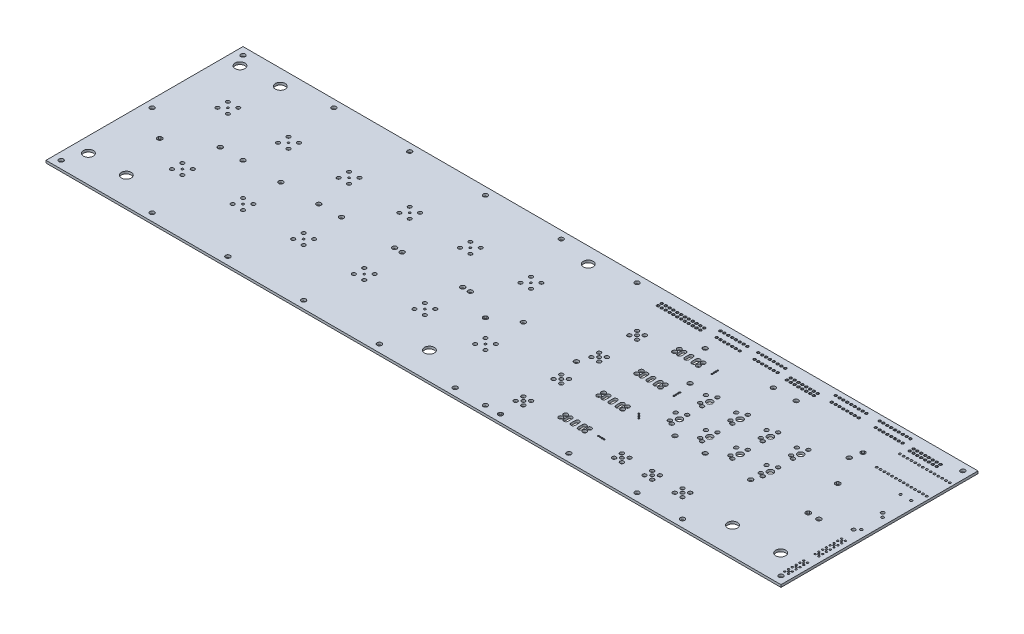
SolidWorks part; units mm, degrees
ref_plane "Front Plane" through (0, 0, 0) normal (0, 0, 1) x (1, 0, 0)
ref_plane "Top Plane" through (0, 0, 0) normal (0, 1, 0) x (1, 0, 0)
ref_plane "Right Plane" through (0, 0, 0) normal (1, 0, 0) x (0, 0, -1)
sketch "Sketch1" plane through (0, 0, 0) normal (0, 1, 0) x (1, 0, 0)
  line L0 (485, 0) -> (485, 130)
  line L1 (485, 130) -> (0, 130)
  line L2 (0, 130) -> (0, 0)
  line L3 (0, 0) -> (485, 0)
  line L4 (342.2875, 97.7969) -> (342.2875, 97.3931)
  line L5 (342.2875, 97.3931) -> (342.0019, 97.1075)
  line L6 (342.0019, 97.1075) -> (341.5981, 97.1075)
  line L7 (341.5981, 97.1075) -> (341.3125, 97.3931)
  line L8 (341.3125, 97.3931) -> (341.3125, 97.7969)
  line L9 (341.3125, 97.7969) -> (341.5981, 98.0825)
  line L10 (341.5981, 98.0825) -> (342.0019, 98.0825)
  line L11 (342.0019, 98.0825) -> (342.2875, 97.7969)
  line L12 (342.2875, 97.7969) -> (342.2875, 97.3931)
  line L13 (342.2875, 97.3931) -> (342.0019, 97.1075)
  line L14 (342.0019, 97.1075) -> (341.5981, 97.1075)
  line L15 (341.5981, 97.1075) -> (341.3125, 97.3931)
  line L16 (341.3125, 97.3931) -> (341.3125, 97.7969)
  line L17 (341.3125, 97.7969) -> (341.5981, 98.0825)
  line L18 (341.5981, 98.0825) -> (342.0019, 98.0825)
  line L19 (342.0019, 98.0825) -> (342.2875, 97.7969)
  line L20 (342.2875, 99.0669) -> (342.2875, 98.6631)
  line L21 (342.2875, 98.6631) -> (342.0019, 98.3775)
  line L22 (342.0019, 98.3775) -> (341.5981, 98.3775)
  line L23 (341.5981, 98.3775) -> (341.3125, 98.6631)
  line L24 (341.3125, 98.6631) -> (341.3125, 99.0669)
  line L25 (341.3125, 99.0669) -> (341.5981, 99.3525)
  line L26 (341.5981, 99.3525) -> (342.0019, 99.3525)
  line L27 (342.0019, 99.3525) -> (342.2875, 99.0669)
  line L28 (342.2875, 99.0669) -> (342.2875, 98.6631)
  line L29 (342.2875, 98.6631) -> (342.0019, 98.3775)
  line L30 (342.0019, 98.3775) -> (341.5981, 98.3775)
  line L31 (341.5981, 98.3775) -> (341.3125, 98.6631)
  line L32 (341.3125, 98.6631) -> (341.3125, 99.0669)
  line L33 (341.3125, 99.0669) -> (341.5981, 99.3525)
  line L34 (341.5981, 99.3525) -> (342.0019, 99.3525)
  line L35 (342.0019, 99.3525) -> (342.2875, 99.0669)
  line L36 (342.2875, 100.3369) -> (342.2875, 99.9331)
  line L37 (342.2875, 99.9331) -> (342.0019, 99.6475)
  line L38 (342.0019, 99.6475) -> (341.5981, 99.6475)
  line L39 (341.5981, 99.6475) -> (341.3125, 99.9331)
  line L40 (341.3125, 99.9331) -> (341.3125, 100.3369)
  line L41 (341.3125, 100.3369) -> (341.5981, 100.6225)
  line L42 (341.5981, 100.6225) -> (342.0019, 100.6225)
  line L43 (342.0019, 100.6225) -> (342.2875, 100.3369)
  line L44 (342.2875, 100.3369) -> (342.2875, 99.9331)
  line L45 (342.2875, 99.9331) -> (342.0019, 99.6475)
  line L46 (342.0019, 99.6475) -> (341.5981, 99.6475)
  line L47 (341.5981, 99.6475) -> (341.3125, 99.9331)
  line L48 (341.3125, 99.9331) -> (341.3125, 100.3369)
  line L49 (341.3125, 100.3369) -> (341.5981, 100.6225)
  line L50 (341.5981, 100.6225) -> (342.0019, 100.6225)
  line L51 (342.0019, 100.6225) -> (342.2875, 100.3369)
  line L52 (342.2875, 101.6069) -> (342.2875, 101.2031)
  line L53 (342.2875, 101.2031) -> (342.0019, 100.9175)
  line L54 (342.0019, 100.9175) -> (341.5981, 100.9175)
  line L55 (341.5981, 100.9175) -> (341.3125, 101.2031)
  line L56 (341.3125, 101.2031) -> (341.3125, 101.6069)
  line L57 (341.3125, 101.6069) -> (341.5981, 101.8925)
  line L58 (341.5981, 101.8925) -> (342.0019, 101.8925)
  line L59 (342.0019, 101.8925) -> (342.2875, 101.6069)
  line L60 (342.2875, 101.6069) -> (342.2875, 101.2031)
  line L61 (342.2875, 101.2031) -> (342.0019, 100.9175)
  line L62 (342.0019, 100.9175) -> (341.5981, 100.9175)
  line L63 (341.5981, 100.9175) -> (341.3125, 101.2031)
  line L64 (341.3125, 101.2031) -> (341.3125, 101.6069)
  line L65 (341.3125, 101.6069) -> (341.5981, 101.8925)
  line L66 (341.5981, 101.8925) -> (342.0019, 101.8925)
  line L67 (342.0019, 101.8925) -> (342.2875, 101.6069)
  line L68 (342.2875, 72.7969) -> (342.2875, 72.3931)
  line L69 (342.2875, 72.3931) -> (342.0019, 72.1075)
  line L70 (342.0019, 72.1075) -> (341.5981, 72.1075)
  line L71 (341.5981, 72.1075) -> (341.3125, 72.3931)
  line L72 (341.3125, 72.3931) -> (341.3125, 72.7969)
  line L73 (341.3125, 72.7969) -> (341.5981, 73.0825)
  line L74 (341.5981, 73.0825) -> (342.0019, 73.0825)
  line L75 (342.0019, 73.0825) -> (342.2875, 72.7969)
  line L76 (342.2875, 72.7969) -> (342.2875, 72.3931)
  line L77 (342.2875, 72.3931) -> (342.0019, 72.1075)
  line L78 (342.0019, 72.1075) -> (341.5981, 72.1075)
  line L79 (341.5981, 72.1075) -> (341.3125, 72.3931)
  line L80 (341.3125, 72.3931) -> (341.3125, 72.7969)
  line L81 (341.3125, 72.7969) -> (341.5981, 73.0825)
  line L82 (341.5981, 73.0825) -> (342.0019, 73.0825)
  line L83 (342.0019, 73.0825) -> (342.2875, 72.7969)
  line L84 (342.2875, 74.0669) -> (342.2875, 73.6631)
  line L85 (342.2875, 73.6631) -> (342.0019, 73.3775)
  line L86 (342.0019, 73.3775) -> (341.5981, 73.3775)
  line L87 (341.5981, 73.3775) -> (341.3125, 73.6631)
  line L88 (341.3125, 73.6631) -> (341.3125, 74.0669)
  line L89 (341.3125, 74.0669) -> (341.5981, 74.3525)
  line L90 (341.5981, 74.3525) -> (342.0019, 74.3525)
  line L91 (342.0019, 74.3525) -> (342.2875, 74.0669)
  line L92 (342.2875, 74.0669) -> (342.2875, 73.6631)
  line L93 (342.2875, 73.6631) -> (342.0019, 73.3775)
  line L94 (342.0019, 73.3775) -> (341.5981, 73.3775)
  line L95 (341.5981, 73.3775) -> (341.3125, 73.6631)
  line L96 (341.3125, 73.6631) -> (341.3125, 74.0669)
  line L97 (341.3125, 74.0669) -> (341.5981, 74.3525)
  line L98 (341.5981, 74.3525) -> (342.0019, 74.3525)
  line L99 (342.0019, 74.3525) -> (342.2875, 74.0669)
  line L100 (342.2875, 75.3369) -> (342.2875, 74.9331)
  line L101 (342.2875, 74.9331) -> (342.0019, 74.6475)
  line L102 (342.0019, 74.6475) -> (341.5981, 74.6475)
  line L103 (341.5981, 74.6475) -> (341.3125, 74.9331)
  line L104 (341.3125, 74.9331) -> (341.3125, 75.3369)
  line L105 (341.3125, 75.3369) -> (341.5981, 75.6225)
  line L106 (341.5981, 75.6225) -> (342.0019, 75.6225)
  line L107 (342.0019, 75.6225) -> (342.2875, 75.3369)
  line L108 (342.2875, 75.3369) -> (342.2875, 74.9331)
  line L109 (342.2875, 74.9331) -> (342.0019, 74.6475)
  line L110 (342.0019, 74.6475) -> (341.5981, 74.6475)
  line L111 (341.5981, 74.6475) -> (341.3125, 74.9331)
  line L112 (341.3125, 74.9331) -> (341.3125, 75.3369)
  line L113 (341.3125, 75.3369) -> (341.5981, 75.6225)
  line L114 (341.5981, 75.6225) -> (342.0019, 75.6225)
  line L115 (342.0019, 75.6225) -> (342.2875, 75.3369)
  line L116 (342.2875, 76.6069) -> (342.2875, 76.2031)
  line L117 (342.2875, 76.2031) -> (342.0019, 75.9175)
  line L118 (342.0019, 75.9175) -> (341.5981, 75.9175)
  line L119 (341.5981, 75.9175) -> (341.3125, 76.2031)
  line L120 (341.3125, 76.2031) -> (341.3125, 76.6069)
  line L121 (341.3125, 76.6069) -> (341.5981, 76.8925)
  line L122 (341.5981, 76.8925) -> (342.0019, 76.8925)
  line L123 (342.0019, 76.8925) -> (342.2875, 76.6069)
  line L124 (342.2875, 76.6069) -> (342.2875, 76.2031)
  line L125 (342.2875, 76.2031) -> (342.0019, 75.9175)
  line L126 (342.0019, 75.9175) -> (341.5981, 75.9175)
  line L127 (341.5981, 75.9175) -> (341.3125, 76.2031)
  line L128 (341.3125, 76.2031) -> (341.3125, 76.6069)
  line L129 (341.3125, 76.6069) -> (341.5981, 76.8925)
  line L130 (341.5981, 76.8925) -> (342.0019, 76.8925)
  line L131 (342.0019, 76.8925) -> (342.2875, 76.6069)
  line L132 (343.4031, 25.1875) -> (343.8069, 25.1875)
  line L133 (343.8069, 25.1875) -> (344.0925, 24.9019)
  line L134 (344.0925, 24.9019) -> (344.0925, 24.4981)
  line L135 (344.0925, 24.4981) -> (343.8069, 24.2125)
  line L136 (343.8069, 24.2125) -> (343.4031, 24.2125)
  line L137 (343.4031, 24.2125) -> (343.1175, 24.4981)
  line L138 (343.1175, 24.4981) -> (343.1175, 24.9019)
  line L139 (343.1175, 24.9019) -> (343.4031, 25.1875)
  line L140 (343.4031, 25.1875) -> (343.8069, 25.1875)
  line L141 (343.8069, 25.1875) -> (344.0925, 24.9019)
  line L142 (344.0925, 24.9019) -> (344.0925, 24.4981)
  line L143 (344.0925, 24.4981) -> (343.8069, 24.2125)
  line L144 (343.8069, 24.2125) -> (343.4031, 24.2125)
  line L145 (343.4031, 24.2125) -> (343.1175, 24.4981)
  line L146 (343.1175, 24.4981) -> (343.1175, 24.9019)
  line L147 (343.1175, 24.9019) -> (343.4031, 25.1875)
  line L148 (342.1331, 25.1875) -> (342.5369, 25.1875)
  line L149 (342.5369, 25.1875) -> (342.8225, 24.9019)
  line L150 (342.8225, 24.9019) -> (342.8225, 24.4981)
  line L151 (342.8225, 24.4981) -> (342.5369, 24.2125)
  line L152 (342.5369, 24.2125) -> (342.1331, 24.2125)
  line L153 (342.1331, 24.2125) -> (341.8475, 24.4981)
  line L154 (341.8475, 24.4981) -> (341.8475, 24.9019)
  line L155 (341.8475, 24.9019) -> (342.1331, 25.1875)
  line L156 (342.1331, 25.1875) -> (342.5369, 25.1875)
  line L157 (342.5369, 25.1875) -> (342.8225, 24.9019)
  line L158 (342.8225, 24.9019) -> (342.8225, 24.4981)
  line L159 (342.8225, 24.4981) -> (342.5369, 24.2125)
  line L160 (342.5369, 24.2125) -> (342.1331, 24.2125)
  line L161 (342.1331, 24.2125) -> (341.8475, 24.4981)
  line L162 (341.8475, 24.4981) -> (341.8475, 24.9019)
  line L163 (341.8475, 24.9019) -> (342.1331, 25.1875)
  line L164 (340.8631, 25.1875) -> (341.2669, 25.1875)
  line L165 (341.2669, 25.1875) -> (341.5525, 24.9019)
  line L166 (341.5525, 24.9019) -> (341.5525, 24.4981)
  line L167 (341.5525, 24.4981) -> (341.2669, 24.2125)
  line L168 (341.2669, 24.2125) -> (340.8631, 24.2125)
  line L169 (340.8631, 24.2125) -> (340.5775, 24.4981)
  line L170 (340.5775, 24.4981) -> (340.5775, 24.9019)
  line L171 (340.5775, 24.9019) -> (340.8631, 25.1875)
  line L172 (340.8631, 25.1875) -> (341.2669, 25.1875)
  line L173 (341.2669, 25.1875) -> (341.5525, 24.9019)
  line L174 (341.5525, 24.9019) -> (341.5525, 24.4981)
  line L175 (341.5525, 24.4981) -> (341.2669, 24.2125)
  line L176 (341.2669, 24.2125) -> (340.8631, 24.2125)
  line L177 (340.8631, 24.2125) -> (340.5775, 24.4981)
  line L178 (340.5775, 24.4981) -> (340.5775, 24.9019)
  line L179 (340.5775, 24.9019) -> (340.8631, 25.1875)
  line L180 (339.5931, 25.1875) -> (339.9969, 25.1875)
  line L181 (339.9969, 25.1875) -> (340.2825, 24.9019)
  line L182 (340.2825, 24.9019) -> (340.2825, 24.4981)
  line L183 (340.2825, 24.4981) -> (339.9969, 24.2125)
  line L184 (339.9969, 24.2125) -> (339.5931, 24.2125)
  line L185 (339.5931, 24.2125) -> (339.3075, 24.4981)
  line L186 (339.3075, 24.4981) -> (339.3075, 24.9019)
  line L187 (339.3075, 24.9019) -> (339.5931, 25.1875)
  line L188 (339.5931, 25.1875) -> (339.9969, 25.1875)
  line L189 (339.9969, 25.1875) -> (340.2825, 24.9019)
  line L190 (340.2825, 24.9019) -> (340.2825, 24.4981)
  line L191 (340.2825, 24.4981) -> (339.9969, 24.2125)
  line L192 (339.9969, 24.2125) -> (339.5931, 24.2125)
  line L193 (339.5931, 24.2125) -> (339.3075, 24.4981)
  line L194 (339.3075, 24.4981) -> (339.3075, 24.9019)
  line L195 (339.3075, 24.9019) -> (339.5931, 25.1875)
  line L196 (343.2489, 48.6405) -> (343.5345, 48.3549)
  line L197 (343.5345, 48.3549) -> (343.5345, 47.9511)
  line L198 (343.5345, 47.9511) -> (343.2489, 47.6655)
  line L199 (343.2489, 47.6655) -> (342.8451, 47.6655)
  line L200 (342.8451, 47.6655) -> (342.5595, 47.9511)
  line L201 (342.5595, 47.9511) -> (342.5595, 48.3549)
  line L202 (342.5595, 48.3549) -> (342.8451, 48.6405)
  line L203 (342.8451, 48.6405) -> (343.2489, 48.6405)
  line L204 (343.2489, 48.6405) -> (343.5345, 48.3549)
  line L205 (343.5345, 48.3549) -> (343.5345, 47.9511)
  line L206 (343.5345, 47.9511) -> (343.2489, 47.6655)
  line L207 (343.2489, 47.6655) -> (342.8451, 47.6655)
  line L208 (342.8451, 47.6655) -> (342.5595, 47.9511)
  line L209 (342.5595, 47.9511) -> (342.5595, 48.3549)
  line L210 (342.5595, 48.3549) -> (342.8451, 48.6405)
  line L211 (342.8451, 48.6405) -> (343.2489, 48.6405)
  line L212 (342.3509, 49.5385) -> (342.6365, 49.2529)
  line L213 (342.6365, 49.2529) -> (342.6365, 48.8491)
  line L214 (342.6365, 48.8491) -> (342.3509, 48.5635)
  line L215 (342.3509, 48.5635) -> (341.9471, 48.5635)
  line L216 (341.9471, 48.5635) -> (341.6615, 48.8491)
  line L217 (341.6615, 48.8491) -> (341.6615, 49.2529)
  line L218 (341.6615, 49.2529) -> (341.9471, 49.5385)
  line L219 (341.9471, 49.5385) -> (342.3509, 49.5385)
  line L220 (342.3509, 49.5385) -> (342.6365, 49.2529)
  line L221 (342.6365, 49.2529) -> (342.6365, 48.8491)
  line L222 (342.6365, 48.8491) -> (342.3509, 48.5635)
  line L223 (342.3509, 48.5635) -> (341.9471, 48.5635)
  line L224 (341.9471, 48.5635) -> (341.6615, 48.8491)
  line L225 (341.6615, 48.8491) -> (341.6615, 49.2529)
  line L226 (341.6615, 49.2529) -> (341.9471, 49.5385)
  line L227 (341.9471, 49.5385) -> (342.3509, 49.5385)
  line L228 (341.4529, 50.4365) -> (341.7385, 50.1509)
  line L229 (341.7385, 50.1509) -> (341.7385, 49.7471)
  line L230 (341.7385, 49.7471) -> (341.4529, 49.4615)
  line L231 (341.4529, 49.4615) -> (341.0491, 49.4615)
  line L232 (341.0491, 49.4615) -> (340.7635, 49.7471)
  line L233 (340.7635, 49.7471) -> (340.7635, 50.1509)
  line L234 (340.7635, 50.1509) -> (341.0491, 50.4365)
  line L235 (341.0491, 50.4365) -> (341.4529, 50.4365)
  line L236 (341.4529, 50.4365) -> (341.7385, 50.1509)
  line L237 (341.7385, 50.1509) -> (341.7385, 49.7471)
  line L238 (341.7385, 49.7471) -> (341.4529, 49.4615)
  line L239 (341.4529, 49.4615) -> (341.0491, 49.4615)
  line L240 (341.0491, 49.4615) -> (340.7635, 49.7471)
  line L241 (340.7635, 49.7471) -> (340.7635, 50.1509)
  line L242 (340.7635, 50.1509) -> (341.0491, 50.4365)
  line L243 (341.0491, 50.4365) -> (341.4529, 50.4365)
  line L244 (340.5549, 51.3345) -> (340.8405, 51.0489)
  line L245 (340.8405, 51.0489) -> (340.8405, 50.6451)
  line L246 (340.8405, 50.6451) -> (340.5549, 50.3595)
  line L247 (340.5549, 50.3595) -> (340.1511, 50.3595)
  line L248 (340.1511, 50.3595) -> (339.8655, 50.6451)
  line L249 (339.8655, 50.6451) -> (339.8655, 51.0489)
  line L250 (339.8655, 51.0489) -> (340.1511, 51.3345)
  line L251 (340.1511, 51.3345) -> (340.5549, 51.3345)
  line L252 (340.5549, 51.3345) -> (340.8405, 51.0489)
  line L253 (340.8405, 51.0489) -> (340.8405, 50.6451)
  line L254 (340.8405, 50.6451) -> (340.5549, 50.3595)
  line L255 (340.5549, 50.3595) -> (340.1511, 50.3595)
  line L256 (340.1511, 50.3595) -> (339.8655, 50.6451)
  line L257 (339.8655, 50.6451) -> (339.8655, 51.0489)
  line L258 (339.8655, 51.0489) -> (340.1511, 51.3345)
  line L259 (340.1511, 51.3345) -> (340.5549, 51.3345)
  line L260 (321.715, 119.6583) -> (321.715, 120.3417)
  line L261 (321.715, 120.3417) -> (322.1983, 120.825)
  line L262 (322.1983, 120.825) -> (322.8817, 120.825)
  line L263 (322.8817, 120.825) -> (323.365, 120.3417)
  line L264 (323.365, 120.3417) -> (323.365, 119.6583)
  line L265 (323.365, 119.6583) -> (322.8817, 119.175)
  line L266 (322.8817, 119.175) -> (322.1983, 119.175)
  line L267 (322.1983, 119.175) -> (321.715, 119.6583)
  line L268 (321.715, 119.6583) -> (321.715, 120.3417)
  line L269 (321.715, 120.3417) -> (322.1983, 120.825)
  line L270 (322.1983, 120.825) -> (322.8817, 120.825)
  line L271 (322.8817, 120.825) -> (323.365, 120.3417)
  line L272 (323.365, 120.3417) -> (323.365, 119.6583)
  line L273 (323.365, 119.6583) -> (322.8817, 119.175)
  line L274 (322.8817, 119.175) -> (322.1983, 119.175)
  line L275 (322.1983, 119.175) -> (321.715, 119.6583)
  line L276 (324.255, 119.6583) -> (324.255, 120.3417)
  line L277 (324.255, 120.3417) -> (324.7383, 120.825)
  line L278 (324.7383, 120.825) -> (325.4217, 120.825)
  line L279 (325.4217, 120.825) -> (325.905, 120.3417)
  line L280 (325.905, 120.3417) -> (325.905, 119.6583)
  line L281 (325.905, 119.6583) -> (325.4217, 119.175)
  line L282 (325.4217, 119.175) -> (324.7383, 119.175)
  line L283 (324.7383, 119.175) -> (324.255, 119.6583)
  line L284 (324.255, 119.6583) -> (324.255, 120.3417)
  line L285 (324.255, 120.3417) -> (324.7383, 120.825)
  line L286 (324.7383, 120.825) -> (325.4217, 120.825)
  line L287 (325.4217, 120.825) -> (325.905, 120.3417)
  line L288 (325.905, 120.3417) -> (325.905, 119.6583)
  line L289 (325.905, 119.6583) -> (325.4217, 119.175)
  line L290 (325.4217, 119.175) -> (324.7383, 119.175)
  line L291 (324.7383, 119.175) -> (324.255, 119.6583)
  line L292 (326.795, 119.6583) -> (326.795, 120.3417)
  line L293 (326.795, 120.3417) -> (327.2783, 120.825)
  line L294 (327.2783, 120.825) -> (327.9617, 120.825)
  line L295 (327.9617, 120.825) -> (328.445, 120.3417)
  line L296 (328.445, 120.3417) -> (328.445, 119.6583)
  line L297 (328.445, 119.6583) -> (327.9617, 119.175)
  line L298 (327.9617, 119.175) -> (327.2783, 119.175)
  line L299 (327.2783, 119.175) -> (326.795, 119.6583)
  line L300 (326.795, 119.6583) -> (326.795, 120.3417)
  line L301 (326.795, 120.3417) -> (327.2783, 120.825)
  line L302 (327.2783, 120.825) -> (327.9617, 120.825)
  line L303 (327.9617, 120.825) -> (328.445, 120.3417)
  line L304 (328.445, 120.3417) -> (328.445, 119.6583)
  line L305 (328.445, 119.6583) -> (327.9617, 119.175)
  line L306 (327.9617, 119.175) -> (327.2783, 119.175)
  line L307 (327.2783, 119.175) -> (326.795, 119.6583)
  line L308 (329.335, 119.6583) -> (329.335, 120.3417)
  line L309 (329.335, 120.3417) -> (329.8183, 120.825)
  line L310 (329.8183, 120.825) -> (330.5017, 120.825)
  line L311 (330.5017, 120.825) -> (330.985, 120.3417)
  line L312 (330.985, 120.3417) -> (330.985, 119.6583)
  line L313 (330.985, 119.6583) -> (330.5017, 119.175)
  line L314 (330.5017, 119.175) -> (329.8183, 119.175)
  line L315 (329.8183, 119.175) -> (329.335, 119.6583)
  line L316 (329.335, 119.6583) -> (329.335, 120.3417)
  line L317 (329.335, 120.3417) -> (329.8183, 120.825)
  line L318 (329.8183, 120.825) -> (330.5017, 120.825)
  line L319 (330.5017, 120.825) -> (330.985, 120.3417)
  line L320 (330.985, 120.3417) -> (330.985, 119.6583)
  line L321 (330.985, 119.6583) -> (330.5017, 119.175)
  line L322 (330.5017, 119.175) -> (329.8183, 119.175)
  line L323 (329.8183, 119.175) -> (329.335, 119.6583)
  line L324 (331.875, 119.6583) -> (331.875, 120.3417)
  line L325 (331.875, 120.3417) -> (332.3583, 120.825)
  line L326 (332.3583, 120.825) -> (333.0417, 120.825)
  line L327 (333.0417, 120.825) -> (333.525, 120.3417)
  line L328 (333.525, 120.3417) -> (333.525, 119.6583)
  line L329 (333.525, 119.6583) -> (333.0417, 119.175)
  line L330 (333.0417, 119.175) -> (332.3583, 119.175)
  line L331 (332.3583, 119.175) -> (331.875, 119.6583)
  line L332 (331.875, 119.6583) -> (331.875, 120.3417)
  line L333 (331.875, 120.3417) -> (332.3583, 120.825)
  line L334 (332.3583, 120.825) -> (333.0417, 120.825)
  line L335 (333.0417, 120.825) -> (333.525, 120.3417)
  line L336 (333.525, 120.3417) -> (333.525, 119.6583)
  line L337 (333.525, 119.6583) -> (333.0417, 119.175)
  line L338 (333.0417, 119.175) -> (332.3583, 119.175)
  line L339 (332.3583, 119.175) -> (331.875, 119.6583)
  line L340 (334.415, 119.6583) -> (334.415, 120.3417)
  line L341 (334.415, 120.3417) -> (334.8983, 120.825)
  line L342 (334.8983, 120.825) -> (335.5817, 120.825)
  line L343 (335.5817, 120.825) -> (336.065, 120.3417)
  line L344 (336.065, 120.3417) -> (336.065, 119.6583)
  line L345 (336.065, 119.6583) -> (335.5817, 119.175)
  line L346 (335.5817, 119.175) -> (334.8983, 119.175)
  line L347 (334.8983, 119.175) -> (334.415, 119.6583)
  line L348 (334.415, 119.6583) -> (334.415, 120.3417)
  line L349 (334.415, 120.3417) -> (334.8983, 120.825)
  line L350 (334.8983, 120.825) -> (335.5817, 120.825)
  line L351 (335.5817, 120.825) -> (336.065, 120.3417)
  line L352 (336.065, 120.3417) -> (336.065, 119.6583)
  line L353 (336.065, 119.6583) -> (335.5817, 119.175)
  line L354 (335.5817, 119.175) -> (334.8983, 119.175)
  line L355 (334.8983, 119.175) -> (334.415, 119.6583)
  line L356 (336.955, 119.6583) -> (336.955, 120.3417)
  line L357 (336.955, 120.3417) -> (337.4383, 120.825)
  line L358 (337.4383, 120.825) -> (338.1217, 120.825)
  line L359 (338.1217, 120.825) -> (338.605, 120.3417)
  line L360 (338.605, 120.3417) -> (338.605, 119.6583)
  line L361 (338.605, 119.6583) -> (338.1217, 119.175)
  line L362 (338.1217, 119.175) -> (337.4383, 119.175)
  line L363 (337.4383, 119.175) -> (336.955, 119.6583)
  line L364 (336.955, 119.6583) -> (336.955, 120.3417)
  line L365 (336.955, 120.3417) -> (337.4383, 120.825)
  line L366 (337.4383, 120.825) -> (338.1217, 120.825)
  line L367 (338.1217, 120.825) -> (338.605, 120.3417)
  line L368 (338.605, 120.3417) -> (338.605, 119.6583)
  line L369 (338.605, 119.6583) -> (338.1217, 119.175)
  line L370 (338.1217, 119.175) -> (337.4383, 119.175)
  line L371 (337.4383, 119.175) -> (336.955, 119.6583)
  line L372 (319.175, 124.7383) -> (319.175, 125.4217)
  line L373 (319.175, 125.4217) -> (319.6583, 125.905)
  line L374 (319.6583, 125.905) -> (320.3417, 125.905)
  line L375 (320.3417, 125.905) -> (320.825, 125.4217)
  line L376 (320.825, 125.4217) -> (320.825, 124.7383)
  line L377 (320.825, 124.7383) -> (320.3417, 124.255)
  line L378 (320.3417, 124.255) -> (319.6583, 124.255)
  line L379 (319.6583, 124.255) -> (319.175, 124.7383)
  line L380 (319.175, 124.7383) -> (319.175, 125.4217)
  line L381 (319.175, 125.4217) -> (319.6583, 125.905)
  line L382 (319.6583, 125.905) -> (320.3417, 125.905)
  line L383 (320.3417, 125.905) -> (320.825, 125.4217)
  line L384 (320.825, 125.4217) -> (320.825, 124.7383)
  line L385 (320.825, 124.7383) -> (320.3417, 124.255)
  line L386 (320.3417, 124.255) -> (319.6583, 124.255)
  line L387 (319.6583, 124.255) -> (319.175, 124.7383)
  line L388 (321.715, 124.7383) -> (321.715, 125.4217)
  line L389 (321.715, 125.4217) -> (322.1983, 125.905)
  line L390 (322.1983, 125.905) -> (322.8817, 125.905)
  line L391 (322.8817, 125.905) -> (323.365, 125.4217)
  line L392 (323.365, 125.4217) -> (323.365, 124.7383)
  line L393 (323.365, 124.7383) -> (322.8817, 124.255)
  line L394 (322.8817, 124.255) -> (322.1983, 124.255)
  line L395 (322.1983, 124.255) -> (321.715, 124.7383)
  line L396 (321.715, 124.7383) -> (321.715, 125.4217)
  line L397 (321.715, 125.4217) -> (322.1983, 125.905)
  line L398 (322.1983, 125.905) -> (322.8817, 125.905)
  line L399 (322.8817, 125.905) -> (323.365, 125.4217)
  line L400 (323.365, 125.4217) -> (323.365, 124.7383)
  line L401 (323.365, 124.7383) -> (322.8817, 124.255)
  line L402 (322.8817, 124.255) -> (322.1983, 124.255)
  line L403 (322.1983, 124.255) -> (321.715, 124.7383)
  line L404 (324.255, 124.7383) -> (324.255, 125.4217)
  line L405 (324.255, 125.4217) -> (324.7383, 125.905)
  line L406 (324.7383, 125.905) -> (325.4217, 125.905)
  line L407 (325.4217, 125.905) -> (325.905, 125.4217)
  line L408 (325.905, 125.4217) -> (325.905, 124.7383)
  line L409 (325.905, 124.7383) -> (325.4217, 124.255)
  line L410 (325.4217, 124.255) -> (324.7383, 124.255)
  line L411 (324.7383, 124.255) -> (324.255, 124.7383)
  line L412 (324.255, 124.7383) -> (324.255, 125.4217)
  line L413 (324.255, 125.4217) -> (324.7383, 125.905)
  line L414 (324.7383, 125.905) -> (325.4217, 125.905)
  line L415 (325.4217, 125.905) -> (325.905, 125.4217)
  line L416 (325.905, 125.4217) -> (325.905, 124.7383)
  line L417 (325.905, 124.7383) -> (325.4217, 124.255)
  line L418 (325.4217, 124.255) -> (324.7383, 124.255)
  line L419 (324.7383, 124.255) -> (324.255, 124.7383)
  line L420 (326.795, 124.7383) -> (326.795, 125.4217)
  line L421 (326.795, 125.4217) -> (327.2783, 125.905)
  line L422 (327.2783, 125.905) -> (327.9617, 125.905)
  line L423 (327.9617, 125.905) -> (328.445, 125.4217)
  line L424 (328.445, 125.4217) -> (328.445, 124.7383)
  line L425 (328.445, 124.7383) -> (327.9617, 124.255)
  line L426 (327.9617, 124.255) -> (327.2783, 124.255)
  line L427 (327.2783, 124.255) -> (326.795, 124.7383)
  line L428 (326.795, 124.7383) -> (326.795, 125.4217)
  line L429 (326.795, 125.4217) -> (327.2783, 125.905)
  line L430 (327.2783, 125.905) -> (327.9617, 125.905)
  line L431 (327.9617, 125.905) -> (328.445, 125.4217)
  line L432 (328.445, 125.4217) -> (328.445, 124.7383)
  line L433 (328.445, 124.7383) -> (327.9617, 124.255)
  line L434 (327.9617, 124.255) -> (327.2783, 124.255)
  line L435 (327.2783, 124.255) -> (326.795, 124.7383)
  line L436 (329.335, 124.7383) -> (329.335, 125.4217)
  line L437 (329.335, 125.4217) -> (329.8183, 125.905)
  line L438 (329.8183, 125.905) -> (330.5017, 125.905)
  line L439 (330.5017, 125.905) -> (330.985, 125.4217)
  line L440 (330.985, 125.4217) -> (330.985, 124.7383)
  line L441 (330.985, 124.7383) -> (330.5017, 124.255)
  line L442 (330.5017, 124.255) -> (329.8183, 124.255)
  line L443 (329.8183, 124.255) -> (329.335, 124.7383)
  line L444 (329.335, 124.7383) -> (329.335, 125.4217)
  line L445 (329.335, 125.4217) -> (329.8183, 125.905)
  line L446 (329.8183, 125.905) -> (330.5017, 125.905)
  line L447 (330.5017, 125.905) -> (330.985, 125.4217)
  line L448 (330.985, 125.4217) -> (330.985, 124.7383)
  line L449 (330.985, 124.7383) -> (330.5017, 124.255)
  line L450 (330.5017, 124.255) -> (329.8183, 124.255)
  line L451 (329.8183, 124.255) -> (329.335, 124.7383)
  line L452 (331.875, 124.7383) -> (331.875, 125.4217)
  line L453 (331.875, 125.4217) -> (332.3583, 125.905)
  line L454 (332.3583, 125.905) -> (333.0417, 125.905)
  line L455 (333.0417, 125.905) -> (333.525, 125.4217)
  line L456 (333.525, 125.4217) -> (333.525, 124.7383)
  line L457 (333.525, 124.7383) -> (333.0417, 124.255)
  line L458 (333.0417, 124.255) -> (332.3583, 124.255)
  line L459 (332.3583, 124.255) -> (331.875, 124.7383)
  line L460 (331.875, 124.7383) -> (331.875, 125.4217)
  line L461 (331.875, 125.4217) -> (332.3583, 125.905)
  line L462 (332.3583, 125.905) -> (333.0417, 125.905)
  line L463 (333.0417, 125.905) -> (333.525, 125.4217)
  line L464 (333.525, 125.4217) -> (333.525, 124.7383)
  line L465 (333.525, 124.7383) -> (333.0417, 124.255)
  line L466 (333.0417, 124.255) -> (332.3583, 124.255)
  line L467 (332.3583, 124.255) -> (331.875, 124.7383)
  line L468 (334.415, 124.7383) -> (334.415, 125.4217)
  line L469 (334.415, 125.4217) -> (334.8983, 125.905)
  line L470 (334.8983, 125.905) -> (335.5817, 125.905)
  line L471 (335.5817, 125.905) -> (336.065, 125.4217)
  line L472 (336.065, 125.4217) -> (336.065, 124.7383)
  line L473 (336.065, 124.7383) -> (335.5817, 124.255)
  line L474 (335.5817, 124.255) -> (334.8983, 124.255)
  line L475 (334.8983, 124.255) -> (334.415, 124.7383)
  line L476 (334.415, 124.7383) -> (334.415, 125.4217)
  line L477 (334.415, 125.4217) -> (334.8983, 125.905)
  line L478 (334.8983, 125.905) -> (335.5817, 125.905)
  line L479 (335.5817, 125.905) -> (336.065, 125.4217)
  line L480 (336.065, 125.4217) -> (336.065, 124.7383)
  line L481 (336.065, 124.7383) -> (335.5817, 124.255)
  line L482 (335.5817, 124.255) -> (334.8983, 124.255)
  line L483 (334.8983, 124.255) -> (334.415, 124.7383)
  line L484 (336.955, 124.7383) -> (336.955, 125.4217)
  line L485 (336.955, 125.4217) -> (337.4383, 125.905)
  line L486 (337.4383, 125.905) -> (338.1217, 125.905)
  line L487 (338.1217, 125.905) -> (338.605, 125.4217)
  line L488 (338.605, 125.4217) -> (338.605, 124.7383)
  line L489 (338.605, 124.7383) -> (338.1217, 124.255)
  line L490 (338.1217, 124.255) -> (337.4383, 124.255)
  line L491 (337.4383, 124.255) -> (336.955, 124.7383)
  line L492 (336.955, 124.7383) -> (336.955, 125.4217)
  line L493 (336.955, 125.4217) -> (337.4383, 125.905)
  line L494 (337.4383, 125.905) -> (338.1217, 125.905)
  line L495 (338.1217, 125.905) -> (338.605, 125.4217)
  line L496 (338.605, 125.4217) -> (338.605, 124.7383)
  line L497 (338.605, 124.7383) -> (338.1217, 124.255)
  line L498 (338.1217, 124.255) -> (337.4383, 124.255)
  line L499 (337.4383, 124.255) -> (336.955, 124.7383)
  line L500 (346.715, 119.6583) -> (346.715, 120.3417)
  line L501 (346.715, 120.3417) -> (347.1983, 120.825)
  line L502 (347.1983, 120.825) -> (347.8817, 120.825)
  line L503 (347.8817, 120.825) -> (348.365, 120.3417)
  line L504 (348.365, 120.3417) -> (348.365, 119.6583)
  line L505 (348.365, 119.6583) -> (347.8817, 119.175)
  line L506 (347.8817, 119.175) -> (347.1983, 119.175)
  line L507 (347.1983, 119.175) -> (346.715, 119.6583)
  line L508 (346.715, 119.6583) -> (346.715, 120.3417)
  line L509 (346.715, 120.3417) -> (347.1983, 120.825)
  line L510 (347.1983, 120.825) -> (347.8817, 120.825)
  line L511 (347.8817, 120.825) -> (348.365, 120.3417)
  line L512 (348.365, 120.3417) -> (348.365, 119.6583)
  line L513 (348.365, 119.6583) -> (347.8817, 119.175)
  line L514 (347.8817, 119.175) -> (347.1983, 119.175)
  line L515 (347.1983, 119.175) -> (346.715, 119.6583)
  line L516 (349.255, 119.6583) -> (349.255, 120.3417)
  line L517 (349.255, 120.3417) -> (349.7383, 120.825)
  line L518 (349.7383, 120.825) -> (350.4217, 120.825)
  line L519 (350.4217, 120.825) -> (350.905, 120.3417)
  line L520 (350.905, 120.3417) -> (350.905, 119.6583)
  line L521 (350.905, 119.6583) -> (350.4217, 119.175)
  line L522 (350.4217, 119.175) -> (349.7383, 119.175)
  line L523 (349.7383, 119.175) -> (349.255, 119.6583)
  line L524 (349.255, 119.6583) -> (349.255, 120.3417)
  line L525 (349.255, 120.3417) -> (349.7383, 120.825)
  line L526 (349.7383, 120.825) -> (350.4217, 120.825)
  line L527 (350.4217, 120.825) -> (350.905, 120.3417)
  line L528 (350.905, 120.3417) -> (350.905, 119.6583)
  line L529 (350.905, 119.6583) -> (350.4217, 119.175)
  line L530 (350.4217, 119.175) -> (349.7383, 119.175)
  line L531 (349.7383, 119.175) -> (349.255, 119.6583)
  line L532 (351.795, 119.6583) -> (351.795, 120.3417)
  line L533 (351.795, 120.3417) -> (352.2783, 120.825)
  line L534 (352.2783, 120.825) -> (352.9617, 120.825)
  line L535 (352.9617, 120.825) -> (353.445, 120.3417)
  line L536 (353.445, 120.3417) -> (353.445, 119.6583)
  line L537 (353.445, 119.6583) -> (352.9617, 119.175)
  line L538 (352.9617, 119.175) -> (352.2783, 119.175)
  line L539 (352.2783, 119.175) -> (351.795, 119.6583)
  line L540 (351.795, 119.6583) -> (351.795, 120.3417)
  line L541 (351.795, 120.3417) -> (352.2783, 120.825)
  line L542 (352.2783, 120.825) -> (352.9617, 120.825)
  line L543 (352.9617, 120.825) -> (353.445, 120.3417)
  line L544 (353.445, 120.3417) -> (353.445, 119.6583)
  line L545 (353.445, 119.6583) -> (352.9617, 119.175)
  line L546 (352.9617, 119.175) -> (352.2783, 119.175)
  line L547 (352.2783, 119.175) -> (351.795, 119.6583)
  line L548 (354.335, 119.6583) -> (354.335, 120.3417)
  line L549 (354.335, 120.3417) -> (354.8183, 120.825)
  line L550 (354.8183, 120.825) -> (355.5017, 120.825)
  line L551 (355.5017, 120.825) -> (355.985, 120.3417)
  line L552 (355.985, 120.3417) -> (355.985, 119.6583)
  line L553 (355.985, 119.6583) -> (355.5017, 119.175)
  line L554 (355.5017, 119.175) -> (354.8183, 119.175)
  line L555 (354.8183, 119.175) -> (354.335, 119.6583)
  line L556 (354.335, 119.6583) -> (354.335, 120.3417)
  line L557 (354.335, 120.3417) -> (354.8183, 120.825)
  line L558 (354.8183, 120.825) -> (355.5017, 120.825)
  line L559 (355.5017, 120.825) -> (355.985, 120.3417)
  line L560 (355.985, 120.3417) -> (355.985, 119.6583)
  line L561 (355.985, 119.6583) -> (355.5017, 119.175)
  line L562 (355.5017, 119.175) -> (354.8183, 119.175)
  line L563 (354.8183, 119.175) -> (354.335, 119.6583)
  line L564 (356.875, 119.6583) -> (356.875, 120.3417)
  line L565 (356.875, 120.3417) -> (357.3583, 120.825)
  line L566 (357.3583, 120.825) -> (358.0417, 120.825)
  line L567 (358.0417, 120.825) -> (358.525, 120.3417)
  line L568 (358.525, 120.3417) -> (358.525, 119.6583)
  line L569 (358.525, 119.6583) -> (358.0417, 119.175)
  line L570 (358.0417, 119.175) -> (357.3583, 119.175)
  line L571 (357.3583, 119.175) -> (356.875, 119.6583)
  line L572 (356.875, 119.6583) -> (356.875, 120.3417)
  line L573 (356.875, 120.3417) -> (357.3583, 120.825)
  line L574 (357.3583, 120.825) -> (358.0417, 120.825)
  line L575 (358.0417, 120.825) -> (358.525, 120.3417)
  line L576 (358.525, 120.3417) -> (358.525, 119.6583)
  line L577 (358.525, 119.6583) -> (358.0417, 119.175)
  line L578 (358.0417, 119.175) -> (357.3583, 119.175)
  line L579 (357.3583, 119.175) -> (356.875, 119.6583)
  line L580 (359.415, 119.6583) -> (359.415, 120.3417)
  line L581 (359.415, 120.3417) -> (359.8983, 120.825)
  line L582 (359.8983, 120.825) -> (360.5817, 120.825)
  line L583 (360.5817, 120.825) -> (361.065, 120.3417)
  line L584 (361.065, 120.3417) -> (361.065, 119.6583)
  line L585 (361.065, 119.6583) -> (360.5817, 119.175)
  line L586 (360.5817, 119.175) -> (359.8983, 119.175)
  line L587 (359.8983, 119.175) -> (359.415, 119.6583)
  line L588 (359.415, 119.6583) -> (359.415, 120.3417)
  line L589 (359.415, 120.3417) -> (359.8983, 120.825)
  line L590 (359.8983, 120.825) -> (360.5817, 120.825)
  line L591 (360.5817, 120.825) -> (361.065, 120.3417)
  line L592 (361.065, 120.3417) -> (361.065, 119.6583)
  line L593 (361.065, 119.6583) -> (360.5817, 119.175)
  line L594 (360.5817, 119.175) -> (359.8983, 119.175)
  line L595 (359.8983, 119.175) -> (359.415, 119.6583)
  line L596 (361.955, 119.6583) -> (361.955, 120.3417)
  line L597 (361.955, 120.3417) -> (362.4383, 120.825)
  line L598 (362.4383, 120.825) -> (363.1217, 120.825)
  line L599 (363.1217, 120.825) -> (363.605, 120.3417)
  line L600 (363.605, 120.3417) -> (363.605, 119.6583)
  line L601 (363.605, 119.6583) -> (363.1217, 119.175)
  line L602 (363.1217, 119.175) -> (362.4383, 119.175)
  line L603 (362.4383, 119.175) -> (361.955, 119.6583)
  line L604 (361.955, 119.6583) -> (361.955, 120.3417)
  line L605 (361.955, 120.3417) -> (362.4383, 120.825)
  line L606 (362.4383, 120.825) -> (363.1217, 120.825)
  line L607 (363.1217, 120.825) -> (363.605, 120.3417)
  line L608 (363.605, 120.3417) -> (363.605, 119.6583)
  line L609 (363.605, 119.6583) -> (363.1217, 119.175)
  line L610 (363.1217, 119.175) -> (362.4383, 119.175)
  line L611 (362.4383, 119.175) -> (361.955, 119.6583)
  line L612 (344.175, 124.7383) -> (344.175, 125.4217)
  line L613 (344.175, 125.4217) -> (344.6583, 125.905)
  line L614 (344.6583, 125.905) -> (345.3417, 125.905)
  line L615 (345.3417, 125.905) -> (345.825, 125.4217)
  line L616 (345.825, 125.4217) -> (345.825, 124.7383)
  line L617 (345.825, 124.7383) -> (345.3417, 124.255)
  line L618 (345.3417, 124.255) -> (344.6583, 124.255)
  line L619 (344.6583, 124.255) -> (344.175, 124.7383)
  line L620 (344.175, 124.7383) -> (344.175, 125.4217)
  line L621 (344.175, 125.4217) -> (344.6583, 125.905)
  line L622 (344.6583, 125.905) -> (345.3417, 125.905)
  line L623 (345.3417, 125.905) -> (345.825, 125.4217)
  line L624 (345.825, 125.4217) -> (345.825, 124.7383)
  line L625 (345.825, 124.7383) -> (345.3417, 124.255)
  line L626 (345.3417, 124.255) -> (344.6583, 124.255)
  line L627 (344.6583, 124.255) -> (344.175, 124.7383)
  line L628 (346.715, 124.7383) -> (346.715, 125.4217)
  line L629 (346.715, 125.4217) -> (347.1983, 125.905)
  line L630 (347.1983, 125.905) -> (347.8817, 125.905)
  line L631 (347.8817, 125.905) -> (348.365, 125.4217)
  line L632 (348.365, 125.4217) -> (348.365, 124.7383)
  line L633 (348.365, 124.7383) -> (347.8817, 124.255)
  line L634 (347.8817, 124.255) -> (347.1983, 124.255)
  line L635 (347.1983, 124.255) -> (346.715, 124.7383)
  line L636 (346.715, 124.7383) -> (346.715, 125.4217)
  line L637 (346.715, 125.4217) -> (347.1983, 125.905)
  line L638 (347.1983, 125.905) -> (347.8817, 125.905)
  line L639 (347.8817, 125.905) -> (348.365, 125.4217)
  line L640 (348.365, 125.4217) -> (348.365, 124.7383)
  line L641 (348.365, 124.7383) -> (347.8817, 124.255)
  line L642 (347.8817, 124.255) -> (347.1983, 124.255)
  line L643 (347.1983, 124.255) -> (346.715, 124.7383)
  line L644 (349.255, 124.7383) -> (349.255, 125.4217)
  line L645 (349.255, 125.4217) -> (349.7383, 125.905)
  line L646 (349.7383, 125.905) -> (350.4217, 125.905)
  line L647 (350.4217, 125.905) -> (350.905, 125.4217)
  line L648 (350.905, 125.4217) -> (350.905, 124.7383)
  line L649 (350.905, 124.7383) -> (350.4217, 124.255)
  line L650 (350.4217, 124.255) -> (349.7383, 124.255)
  line L651 (349.7383, 124.255) -> (349.255, 124.7383)
  line L652 (349.255, 124.7383) -> (349.255, 125.4217)
  line L653 (349.255, 125.4217) -> (349.7383, 125.905)
  line L654 (349.7383, 125.905) -> (350.4217, 125.905)
  line L655 (350.4217, 125.905) -> (350.905, 125.4217)
  line L656 (350.905, 125.4217) -> (350.905, 124.7383)
  line L657 (350.905, 124.7383) -> (350.4217, 124.255)
  line L658 (350.4217, 124.255) -> (349.7383, 124.255)
  line L659 (349.7383, 124.255) -> (349.255, 124.7383)
  line L660 (351.795, 124.7383) -> (351.795, 125.4217)
  line L661 (351.795, 125.4217) -> (352.2783, 125.905)
  line L662 (352.2783, 125.905) -> (352.9617, 125.905)
  line L663 (352.9617, 125.905) -> (353.445, 125.4217)
  line L664 (353.445, 125.4217) -> (353.445, 124.7383)
  line L665 (353.445, 124.7383) -> (352.9617, 124.255)
  line L666 (352.9617, 124.255) -> (352.2783, 124.255)
  line L667 (352.2783, 124.255) -> (351.795, 124.7383)
  line L668 (351.795, 124.7383) -> (351.795, 125.4217)
  line L669 (351.795, 125.4217) -> (352.2783, 125.905)
  line L670 (352.2783, 125.905) -> (352.9617, 125.905)
  line L671 (352.9617, 125.905) -> (353.445, 125.4217)
  line L672 (353.445, 125.4217) -> (353.445, 124.7383)
  line L673 (353.445, 124.7383) -> (352.9617, 124.255)
  line L674 (352.9617, 124.255) -> (352.2783, 124.255)
  line L675 (352.2783, 124.255) -> (351.795, 124.7383)
  line L676 (354.335, 124.7383) -> (354.335, 125.4217)
  line L677 (354.335, 125.4217) -> (354.8183, 125.905)
  line L678 (354.8183, 125.905) -> (355.5017, 125.905)
  line L679 (355.5017, 125.905) -> (355.985, 125.4217)
  line L680 (355.985, 125.4217) -> (355.985, 124.7383)
  line L681 (355.985, 124.7383) -> (355.5017, 124.255)
  line L682 (355.5017, 124.255) -> (354.8183, 124.255)
  line L683 (354.8183, 124.255) -> (354.335, 124.7383)
  line L684 (354.335, 124.7383) -> (354.335, 125.4217)
  line L685 (354.335, 125.4217) -> (354.8183, 125.905)
  line L686 (354.8183, 125.905) -> (355.5017, 125.905)
  line L687 (355.5017, 125.905) -> (355.985, 125.4217)
  line L688 (355.985, 125.4217) -> (355.985, 124.7383)
  line L689 (355.985, 124.7383) -> (355.5017, 124.255)
  line L690 (355.5017, 124.255) -> (354.8183, 124.255)
  line L691 (354.8183, 124.255) -> (354.335, 124.7383)
  line L692 (356.875, 124.7383) -> (356.875, 125.4217)
  line L693 (356.875, 125.4217) -> (357.3583, 125.905)
  line L694 (357.3583, 125.905) -> (358.0417, 125.905)
  line L695 (358.0417, 125.905) -> (358.525, 125.4217)
  line L696 (358.525, 125.4217) -> (358.525, 124.7383)
  line L697 (358.525, 124.7383) -> (358.0417, 124.255)
  line L698 (358.0417, 124.255) -> (357.3583, 124.255)
  line L699 (357.3583, 124.255) -> (356.875, 124.7383)
  line L700 (356.875, 124.7383) -> (356.875, 125.4217)
  line L701 (356.875, 125.4217) -> (357.3583, 125.905)
  line L702 (357.3583, 125.905) -> (358.0417, 125.905)
  line L703 (358.0417, 125.905) -> (358.525, 125.4217)
  line L704 (358.525, 125.4217) -> (358.525, 124.7383)
  line L705 (358.525, 124.7383) -> (358.0417, 124.255)
  line L706 (358.0417, 124.255) -> (357.3583, 124.255)
  line L707 (357.3583, 124.255) -> (356.875, 124.7383)
  line L708 (359.415, 124.7383) -> (359.415, 125.4217)
  line L709 (359.415, 125.4217) -> (359.8983, 125.905)
  line L710 (359.8983, 125.905) -> (360.5817, 125.905)
  line L711 (360.5817, 125.905) -> (361.065, 125.4217)
  line L712 (361.065, 125.4217) -> (361.065, 124.7383)
  line L713 (361.065, 124.7383) -> (360.5817, 124.255)
  line L714 (360.5817, 124.255) -> (359.8983, 124.255)
  line L715 (359.8983, 124.255) -> (359.415, 124.7383)
  line L716 (359.415, 124.7383) -> (359.415, 125.4217)
  line L717 (359.415, 125.4217) -> (359.8983, 125.905)
  line L718 (359.8983, 125.905) -> (360.5817, 125.905)
  line L719 (360.5817, 125.905) -> (361.065, 125.4217)
  line L720 (361.065, 125.4217) -> (361.065, 124.7383)
  line L721 (361.065, 124.7383) -> (360.5817, 124.255)
  line L722 (360.5817, 124.255) -> (359.8983, 124.255)
  line L723 (359.8983, 124.255) -> (359.415, 124.7383)
  line L724 (361.955, 124.7383) -> (361.955, 125.4217)
  line L725 (361.955, 125.4217) -> (362.4383, 125.905)
  line L726 (362.4383, 125.905) -> (363.1217, 125.905)
  line L727 (363.1217, 125.905) -> (363.605, 125.4217)
  line L728 (363.605, 125.4217) -> (363.605, 124.7383)
  line L729 (363.605, 124.7383) -> (363.1217, 124.255)
  line L730 (363.1217, 124.255) -> (362.4383, 124.255)
  line L731 (362.4383, 124.255) -> (361.955, 124.7383)
  line L732 (361.955, 124.7383) -> (361.955, 125.4217)
  line L733 (361.955, 125.4217) -> (362.4383, 125.905)
  line L734 (362.4383, 125.905) -> (363.1217, 125.905)
  line L735 (363.1217, 125.905) -> (363.605, 125.4217)
  line L736 (363.605, 125.4217) -> (363.605, 124.7383)
  line L737 (363.605, 124.7383) -> (363.1217, 124.255)
  line L738 (363.1217, 124.255) -> (362.4383, 124.255)
  line L739 (362.4383, 124.255) -> (361.955, 124.7383)
  line L740 (284.1918, 118.4828) -> (284.1918, 119.1772)
  line L741 (284.1918, 119.1772) -> (284.6828, 119.6682)
  line L742 (284.6828, 119.6682) -> (285.3772, 119.6682)
  line L743 (285.3772, 119.6682) -> (285.8682, 119.1772)
  line L744 (285.8682, 119.1772) -> (285.8682, 118.4828)
  line L745 (285.8682, 118.4828) -> (285.3772, 117.9918)
  line L746 (285.3772, 117.9918) -> (284.6828, 117.9918)
  line L747 (284.6828, 117.9918) -> (284.1918, 118.4828)
  line L748 (284.1918, 118.4828) -> (284.1918, 119.1772)
  line L749 (284.1918, 119.1772) -> (284.6828, 119.6682)
  line L750 (284.6828, 119.6682) -> (285.3772, 119.6682)
  line L751 (285.3772, 119.6682) -> (285.8682, 119.1772)
  line L752 (285.8682, 119.1772) -> (285.8682, 118.4828)
  line L753 (285.8682, 118.4828) -> (285.3772, 117.9918)
  line L754 (285.3772, 117.9918) -> (284.6828, 117.9918)
  line L755 (284.6828, 117.9918) -> (284.1918, 118.4828)
  line L756 (284.1918, 121.0228) -> (284.1918, 121.7172)
  line L757 (284.1918, 121.7172) -> (284.6828, 122.2082)
  line L758 (284.6828, 122.2082) -> (285.3772, 122.2082)
  line L759 (285.3772, 122.2082) -> (285.8682, 121.7172)
  line L760 (285.8682, 121.7172) -> (285.8682, 121.0228)
  line L761 (285.8682, 121.0228) -> (285.3772, 120.5318)
  line L762 (285.3772, 120.5318) -> (284.6828, 120.5318)
  line L763 (284.6828, 120.5318) -> (284.1918, 121.0228)
  line L764 (284.1918, 121.0228) -> (284.1918, 121.7172)
  line L765 (284.1918, 121.7172) -> (284.6828, 122.2082)
  line L766 (284.6828, 122.2082) -> (285.3772, 122.2082)
  line L767 (285.3772, 122.2082) -> (285.8682, 121.7172)
  line L768 (285.8682, 121.7172) -> (285.8682, 121.0228)
  line L769 (285.8682, 121.0228) -> (285.3772, 120.5318)
  line L770 (285.3772, 120.5318) -> (284.6828, 120.5318)
  line L771 (284.6828, 120.5318) -> (284.1918, 121.0228)
  line L772 (286.7318, 118.4828) -> (286.7318, 119.1772)
  line L773 (286.7318, 119.1772) -> (287.2228, 119.6682)
  line L774 (287.2228, 119.6682) -> (287.9172, 119.6682)
  line L775 (287.9172, 119.6682) -> (288.4082, 119.1772)
  line L776 (288.4082, 119.1772) -> (288.4082, 118.4828)
  line L777 (288.4082, 118.4828) -> (287.9172, 117.9918)
  line L778 (287.9172, 117.9918) -> (287.2228, 117.9918)
  line L779 (287.2228, 117.9918) -> (286.7318, 118.4828)
  line L780 (286.7318, 118.4828) -> (286.7318, 119.1772)
  line L781 (286.7318, 119.1772) -> (287.2228, 119.6682)
  line L782 (287.2228, 119.6682) -> (287.9172, 119.6682)
  line L783 (287.9172, 119.6682) -> (288.4082, 119.1772)
  line L784 (288.4082, 119.1772) -> (288.4082, 118.4828)
  line L785 (288.4082, 118.4828) -> (287.9172, 117.9918)
  line L786 (287.9172, 117.9918) -> (287.2228, 117.9918)
  line L787 (287.2228, 117.9918) -> (286.7318, 118.4828)
  line L788 (286.7318, 121.0228) -> (286.7318, 121.7172)
  line L789 (286.7318, 121.7172) -> (287.2228, 122.2082)
  line L790 (287.2228, 122.2082) -> (287.9172, 122.2082)
  line L791 (287.9172, 122.2082) -> (288.4082, 121.7172)
  line L792 (288.4082, 121.7172) -> (288.4082, 121.0228)
  line L793 (288.4082, 121.0228) -> (287.9172, 120.5318)
  line L794 (287.9172, 120.5318) -> (287.2228, 120.5318)
  line L795 (287.2228, 120.5318) -> (286.7318, 121.0228)
  line L796 (286.7318, 121.0228) -> (286.7318, 121.7172)
  line L797 (286.7318, 121.7172) -> (287.2228, 122.2082)
  line L798 (287.2228, 122.2082) -> (287.9172, 122.2082)
  line L799 (287.9172, 122.2082) -> (288.4082, 121.7172)
  line L800 (288.4082, 121.7172) -> (288.4082, 121.0228)
  line L801 (288.4082, 121.0228) -> (287.9172, 120.5318)
  line L802 (287.9172, 120.5318) -> (287.2228, 120.5318)
  line L803 (287.2228, 120.5318) -> (286.7318, 121.0228)
  line L804 (289.2718, 118.4828) -> (289.2718, 119.1772)
  line L805 (289.2718, 119.1772) -> (289.7628, 119.6682)
  line L806 (289.7628, 119.6682) -> (290.4572, 119.6682)
  line L807 (290.4572, 119.6682) -> (290.9482, 119.1772)
  line L808 (290.9482, 119.1772) -> (290.9482, 118.4828)
  line L809 (290.9482, 118.4828) -> (290.4572, 117.9918)
  line L810 (290.4572, 117.9918) -> (289.7628, 117.9918)
  line L811 (289.7628, 117.9918) -> (289.2718, 118.4828)
  line L812 (289.2718, 118.4828) -> (289.2718, 119.1772)
  line L813 (289.2718, 119.1772) -> (289.7628, 119.6682)
  line L814 (289.7628, 119.6682) -> (290.4572, 119.6682)
  line L815 (290.4572, 119.6682) -> (290.9482, 119.1772)
  line L816 (290.9482, 119.1772) -> (290.9482, 118.4828)
  line L817 (290.9482, 118.4828) -> (290.4572, 117.9918)
  line L818 (290.4572, 117.9918) -> (289.7628, 117.9918)
  line L819 (289.7628, 117.9918) -> (289.2718, 118.4828)
  line L820 (289.2718, 121.0228) -> (289.2718, 121.7172)
  line L821 (289.2718, 121.7172) -> (289.7628, 122.2082)
  line L822 (289.7628, 122.2082) -> (290.4572, 122.2082)
  line L823 (290.4572, 122.2082) -> (290.9482, 121.7172)
  line L824 (290.9482, 121.7172) -> (290.9482, 121.0228)
  line L825 (290.9482, 121.0228) -> (290.4572, 120.5318)
  line L826 (290.4572, 120.5318) -> (289.7628, 120.5318)
  line L827 (289.7628, 120.5318) -> (289.2718, 121.0228)
  line L828 (289.2718, 121.0228) -> (289.2718, 121.7172)
  line L829 (289.2718, 121.7172) -> (289.7628, 122.2082)
  line L830 (289.7628, 122.2082) -> (290.4572, 122.2082)
  line L831 (290.4572, 122.2082) -> (290.9482, 121.7172)
  line L832 (290.9482, 121.7172) -> (290.9482, 121.0228)
  line L833 (290.9482, 121.0228) -> (290.4572, 120.5318)
  line L834 (290.4572, 120.5318) -> (289.7628, 120.5318)
  line L835 (289.7628, 120.5318) -> (289.2718, 121.0228)
  line L836 (291.8118, 118.4828) -> (291.8118, 119.1772)
  line L837 (291.8118, 119.1772) -> (292.3028, 119.6682)
  line L838 (292.3028, 119.6682) -> (292.9972, 119.6682)
  line L839 (292.9972, 119.6682) -> (293.4882, 119.1772)
  line L840 (293.4882, 119.1772) -> (293.4882, 118.4828)
  line L841 (293.4882, 118.4828) -> (292.9972, 117.9918)
  line L842 (292.9972, 117.9918) -> (292.3028, 117.9918)
  line L843 (292.3028, 117.9918) -> (291.8118, 118.4828)
  line L844 (291.8118, 118.4828) -> (291.8118, 119.1772)
  line L845 (291.8118, 119.1772) -> (292.3028, 119.6682)
  line L846 (292.3028, 119.6682) -> (292.9972, 119.6682)
  line L847 (292.9972, 119.6682) -> (293.4882, 119.1772)
  line L848 (293.4882, 119.1772) -> (293.4882, 118.4828)
  line L849 (293.4882, 118.4828) -> (292.9972, 117.9918)
  line L850 (292.9972, 117.9918) -> (292.3028, 117.9918)
  line L851 (292.3028, 117.9918) -> (291.8118, 118.4828)
  line L852 (291.8118, 121.0228) -> (291.8118, 121.7172)
  line L853 (291.8118, 121.7172) -> (292.3028, 122.2082)
  line L854 (292.3028, 122.2082) -> (292.9972, 122.2082)
  line L855 (292.9972, 122.2082) -> (293.4882, 121.7172)
  line L856 (293.4882, 121.7172) -> (293.4882, 121.0228)
  line L857 (293.4882, 121.0228) -> (292.9972, 120.5318)
  line L858 (292.9972, 120.5318) -> (292.3028, 120.5318)
  line L859 (292.3028, 120.5318) -> (291.8118, 121.0228)
  line L860 (291.8118, 121.0228) -> (291.8118, 121.7172)
  line L861 (291.8118, 121.7172) -> (292.3028, 122.2082)
  line L862 (292.3028, 122.2082) -> (292.9972, 122.2082)
  line L863 (292.9972, 122.2082) -> (293.4882, 121.7172)
  line L864 (293.4882, 121.7172) -> (293.4882, 121.0228)
  line L865 (293.4882, 121.0228) -> (292.9972, 120.5318)
  line L866 (292.9972, 120.5318) -> (292.3028, 120.5318)
  line L867 (292.3028, 120.5318) -> (291.8118, 121.0228)
  line L868 (294.3518, 118.4828) -> (294.3518, 119.1772)
  line L869 (294.3518, 119.1772) -> (294.8428, 119.6682)
  line L870 (294.8428, 119.6682) -> (295.5372, 119.6682)
  line L871 (295.5372, 119.6682) -> (296.0282, 119.1772)
  line L872 (296.0282, 119.1772) -> (296.0282, 118.4828)
  line L873 (296.0282, 118.4828) -> (295.5372, 117.9918)
  line L874 (295.5372, 117.9918) -> (294.8428, 117.9918)
  line L875 (294.8428, 117.9918) -> (294.3518, 118.4828)
  line L876 (294.3518, 118.4828) -> (294.3518, 119.1772)
  line L877 (294.3518, 119.1772) -> (294.8428, 119.6682)
  line L878 (294.8428, 119.6682) -> (295.5372, 119.6682)
  line L879 (295.5372, 119.6682) -> (296.0282, 119.1772)
  line L880 (296.0282, 119.1772) -> (296.0282, 118.4828)
  line L881 (296.0282, 118.4828) -> (295.5372, 117.9918)
  line L882 (295.5372, 117.9918) -> (294.8428, 117.9918)
  line L883 (294.8428, 117.9918) -> (294.3518, 118.4828)
  line L884 (294.3518, 121.0228) -> (294.3518, 121.7172)
  line L885 (294.3518, 121.7172) -> (294.8428, 122.2082)
  line L886 (294.8428, 122.2082) -> (295.5372, 122.2082)
  line L887 (295.5372, 122.2082) -> (296.0282, 121.7172)
  line L888 (296.0282, 121.7172) -> (296.0282, 121.0228)
  line L889 (296.0282, 121.0228) -> (295.5372, 120.5318)
  line L890 (295.5372, 120.5318) -> (294.8428, 120.5318)
  line L891 (294.8428, 120.5318) -> (294.3518, 121.0228)
  line L892 (294.3518, 121.0228) -> (294.3518, 121.7172)
  line L893 (294.3518, 121.7172) -> (294.8428, 122.2082)
  line L894 (294.8428, 122.2082) -> (295.5372, 122.2082)
  line L895 (295.5372, 122.2082) -> (296.0282, 121.7172)
  line L896 (296.0282, 121.7172) -> (296.0282, 121.0228)
  line L897 (296.0282, 121.0228) -> (295.5372, 120.5318)
  line L898 (295.5372, 120.5318) -> (294.8428, 120.5318)
  line L899 (294.8428, 120.5318) -> (294.3518, 121.0228)
  line L900 (296.8918, 118.4828) -> (296.8918, 119.1772)
  line L901 (296.8918, 119.1772) -> (297.3828, 119.6682)
  line L902 (297.3828, 119.6682) -> (298.0772, 119.6682)
  line L903 (298.0772, 119.6682) -> (298.5682, 119.1772)
  line L904 (298.5682, 119.1772) -> (298.5682, 118.4828)
  line L905 (298.5682, 118.4828) -> (298.0772, 117.9918)
  line L906 (298.0772, 117.9918) -> (297.3828, 117.9918)
  line L907 (297.3828, 117.9918) -> (296.8918, 118.4828)
  line L908 (296.8918, 118.4828) -> (296.8918, 119.1772)
  line L909 (296.8918, 119.1772) -> (297.3828, 119.6682)
  line L910 (297.3828, 119.6682) -> (298.0772, 119.6682)
  line L911 (298.0772, 119.6682) -> (298.5682, 119.1772)
  line L912 (298.5682, 119.1772) -> (298.5682, 118.4828)
  line L913 (298.5682, 118.4828) -> (298.0772, 117.9918)
  line L914 (298.0772, 117.9918) -> (297.3828, 117.9918)
  line L915 (297.3828, 117.9918) -> (296.8918, 118.4828)
  line L916 (296.8918, 121.0228) -> (296.8918, 121.7172)
  line L917 (296.8918, 121.7172) -> (297.3828, 122.2082)
  line L918 (297.3828, 122.2082) -> (298.0772, 122.2082)
  line L919 (298.0772, 122.2082) -> (298.5682, 121.7172)
  line L920 (298.5682, 121.7172) -> (298.5682, 121.0228)
  line L921 (298.5682, 121.0228) -> (298.0772, 120.5318)
  line L922 (298.0772, 120.5318) -> (297.3828, 120.5318)
  line L923 (297.3828, 120.5318) -> (296.8918, 121.0228)
  line L924 (296.8918, 121.0228) -> (296.8918, 121.7172)
  line L925 (296.8918, 121.7172) -> (297.3828, 122.2082)
  line L926 (297.3828, 122.2082) -> (298.0772, 122.2082)
  line L927 (298.0772, 122.2082) -> (298.5682, 121.7172)
  line L928 (298.5682, 121.7172) -> (298.5682, 121.0228)
  line L929 (298.5682, 121.0228) -> (298.0772, 120.5318)
  line L930 (298.0772, 120.5318) -> (297.3828, 120.5318)
  line L931 (297.3828, 120.5318) -> (296.8918, 121.0228)
  line L932 (299.4318, 118.4828) -> (299.4318, 119.1772)
  line L933 (299.4318, 119.1772) -> (299.9228, 119.6682)
  line L934 (299.9228, 119.6682) -> (300.6172, 119.6682)
  line L935 (300.6172, 119.6682) -> (301.1082, 119.1772)
  line L936 (301.1082, 119.1772) -> (301.1082, 118.4828)
  line L937 (301.1082, 118.4828) -> (300.6172, 117.9918)
  line L938 (300.6172, 117.9918) -> (299.9228, 117.9918)
  line L939 (299.9228, 117.9918) -> (299.4318, 118.4828)
  line L940 (299.4318, 118.4828) -> (299.4318, 119.1772)
  line L941 (299.4318, 119.1772) -> (299.9228, 119.6682)
  line L942 (299.9228, 119.6682) -> (300.6172, 119.6682)
  line L943 (300.6172, 119.6682) -> (301.1082, 119.1772)
  line L944 (301.1082, 119.1772) -> (301.1082, 118.4828)
  line L945 (301.1082, 118.4828) -> (300.6172, 117.9918)
  line L946 (300.6172, 117.9918) -> (299.9228, 117.9918)
  line L947 (299.9228, 117.9918) -> (299.4318, 118.4828)
  line L948 (299.4318, 121.0228) -> (299.4318, 121.7172)
  line L949 (299.4318, 121.7172) -> (299.9228, 122.2082)
  line L950 (299.9228, 122.2082) -> (300.6172, 122.2082)
  line L951 (300.6172, 122.2082) -> (301.1082, 121.7172)
  line L952 (301.1082, 121.7172) -> (301.1082, 121.0228)
  line L953 (301.1082, 121.0228) -> (300.6172, 120.5318)
  line L954 (300.6172, 120.5318) -> (299.9228, 120.5318)
  line L955 (299.9228, 120.5318) -> (299.4318, 121.0228)
  line L956 (299.4318, 121.0228) -> (299.4318, 121.7172)
  line L957 (299.4318, 121.7172) -> (299.9228, 122.2082)
  line L958 (299.9228, 122.2082) -> (300.6172, 122.2082)
  line L959 (300.6172, 122.2082) -> (301.1082, 121.7172)
  line L960 (301.1082, 121.7172) -> (301.1082, 121.0228)
  line L961 (301.1082, 121.0228) -> (300.6172, 120.5318)
  line L962 (300.6172, 120.5318) -> (299.9228, 120.5318)
  line L963 (299.9228, 120.5318) -> (299.4318, 121.0228)
  line L964 (301.9718, 118.4828) -> (301.9718, 119.1772)
  line L965 (301.9718, 119.1772) -> (302.4628, 119.6682)
  line L966 (302.4628, 119.6682) -> (303.1572, 119.6682)
  line L967 (303.1572, 119.6682) -> (303.6482, 119.1772)
  line L968 (303.6482, 119.1772) -> (303.6482, 118.4828)
  line L969 (303.6482, 118.4828) -> (303.1572, 117.9918)
  line L970 (303.1572, 117.9918) -> (302.4628, 117.9918)
  line L971 (302.4628, 117.9918) -> (301.9718, 118.4828)
  line L972 (301.9718, 118.4828) -> (301.9718, 119.1772)
  line L973 (301.9718, 119.1772) -> (302.4628, 119.6682)
  line L974 (302.4628, 119.6682) -> (303.1572, 119.6682)
  line L975 (303.1572, 119.6682) -> (303.6482, 119.1772)
  line L976 (303.6482, 119.1772) -> (303.6482, 118.4828)
  line L977 (303.6482, 118.4828) -> (303.1572, 117.9918)
  line L978 (303.1572, 117.9918) -> (302.4628, 117.9918)
  line L979 (302.4628, 117.9918) -> (301.9718, 118.4828)
  line L980 (301.9718, 121.0228) -> (301.9718, 121.7172)
  line L981 (301.9718, 121.7172) -> (302.4628, 122.2082)
  line L982 (302.4628, 122.2082) -> (303.1572, 122.2082)
  line L983 (303.1572, 122.2082) -> (303.6482, 121.7172)
  line L984 (303.6482, 121.7172) -> (303.6482, 121.0228)
  line L985 (303.6482, 121.0228) -> (303.1572, 120.5318)
  line L986 (303.1572, 120.5318) -> (302.4628, 120.5318)
  line L987 (302.4628, 120.5318) -> (301.9718, 121.0228)
  line L988 (301.9718, 121.0228) -> (301.9718, 121.7172)
  line L989 (301.9718, 121.7172) -> (302.4628, 122.2082)
  line L990 (302.4628, 122.2082) -> (303.1572, 122.2082)
  line L991 (303.1572, 122.2082) -> (303.6482, 121.7172)
  line L992 (303.6482, 121.7172) -> (303.6482, 121.0228)
  line L993 (303.6482, 121.0228) -> (303.1572, 120.5318)
  line L994 (303.1572, 120.5318) -> (302.4628, 120.5318)
  line L995 (302.4628, 120.5318) -> (301.9718, 121.0228)
  line L996 (304.5118, 118.4828) -> (304.5118, 119.1772)
  line L997 (304.5118, 119.1772) -> (305.0028, 119.6682)
  line L998 (305.0028, 119.6682) -> (305.6972, 119.6682)
  line L999 (305.6972, 119.6682) -> (306.1882, 119.1772)
  line L1000 (306.1882, 119.1772) -> (306.1882, 118.4828)
  line L1001 (306.1882, 118.4828) -> (305.6972, 117.9918)
  line L1002 (305.6972, 117.9918) -> (305.0028, 117.9918)
  line L1003 (305.0028, 117.9918) -> (304.5118, 118.4828)
  line L1004 (304.5118, 118.4828) -> (304.5118, 119.1772)
  line L1005 (304.5118, 119.1772) -> (305.0028, 119.6682)
  line L1006 (305.0028, 119.6682) -> (305.6972, 119.6682)
  line L1007 (305.6972, 119.6682) -> (306.1882, 119.1772)
  line L1008 (306.1882, 119.1772) -> (306.1882, 118.4828)
  line L1009 (306.1882, 118.4828) -> (305.6972, 117.9918)
  line L1010 (305.6972, 117.9918) -> (305.0028, 117.9918)
  line L1011 (305.0028, 117.9918) -> (304.5118, 118.4828)
  line L1012 (304.5118, 121.0228) -> (304.5118, 121.7172)
  line L1013 (304.5118, 121.7172) -> (305.0028, 122.2082)
  line L1014 (305.0028, 122.2082) -> (305.6972, 122.2082)
  line L1015 (305.6972, 122.2082) -> (306.1882, 121.7172)
  line L1016 (306.1882, 121.7172) -> (306.1882, 121.0228)
  line L1017 (306.1882, 121.0228) -> (305.6972, 120.5318)
  line L1018 (305.6972, 120.5318) -> (305.0028, 120.5318)
  line L1019 (305.0028, 120.5318) -> (304.5118, 121.0228)
  line L1020 (304.5118, 121.0228) -> (304.5118, 121.7172)
  line L1021 (304.5118, 121.7172) -> (305.0028, 122.2082)
  line L1022 (305.0028, 122.2082) -> (305.6972, 122.2082)
  line L1023 (305.6972, 122.2082) -> (306.1882, 121.7172)
  line L1024 (306.1882, 121.7172) -> (306.1882, 121.0228)
  line L1025 (306.1882, 121.0228) -> (305.6972, 120.5318)
  line L1026 (305.6972, 120.5318) -> (305.0028, 120.5318)
  line L1027 (305.0028, 120.5318) -> (304.5118, 121.0228)
  line L1028 (307.0518, 118.4828) -> (307.0518, 119.1772)
  line L1029 (307.0518, 119.1772) -> (307.5428, 119.6682)
  line L1030 (307.5428, 119.6682) -> (308.2372, 119.6682)
  line L1031 (308.2372, 119.6682) -> (308.7282, 119.1772)
  line L1032 (308.7282, 119.1772) -> (308.7282, 118.4828)
  line L1033 (308.7282, 118.4828) -> (308.2372, 117.9918)
  line L1034 (308.2372, 117.9918) -> (307.5428, 117.9918)
  line L1035 (307.5428, 117.9918) -> (307.0518, 118.4828)
  line L1036 (307.0518, 118.4828) -> (307.0518, 119.1772)
  line L1037 (307.0518, 119.1772) -> (307.5428, 119.6682)
  line L1038 (307.5428, 119.6682) -> (308.2372, 119.6682)
  line L1039 (308.2372, 119.6682) -> (308.7282, 119.1772)
  line L1040 (308.7282, 119.1772) -> (308.7282, 118.4828)
  line L1041 (308.7282, 118.4828) -> (308.2372, 117.9918)
  line L1042 (308.2372, 117.9918) -> (307.5428, 117.9918)
  line L1043 (307.5428, 117.9918) -> (307.0518, 118.4828)
  line L1044 (307.0518, 121.0228) -> (307.0518, 121.7172)
  line L1045 (307.0518, 121.7172) -> (307.5428, 122.2082)
  line L1046 (307.5428, 122.2082) -> (308.2372, 122.2082)
  line L1047 (308.2372, 122.2082) -> (308.7282, 121.7172)
  line L1048 (308.7282, 121.7172) -> (308.7282, 121.0228)
  line L1049 (308.7282, 121.0228) -> (308.2372, 120.5318)
  line L1050 (308.2372, 120.5318) -> (307.5428, 120.5318)
  line L1051 (307.5428, 120.5318) -> (307.0518, 121.0228)
  line L1052 (307.0518, 121.0228) -> (307.0518, 121.7172)
  line L1053 (307.0518, 121.7172) -> (307.5428, 122.2082)
  line L1054 (307.5428, 122.2082) -> (308.2372, 122.2082)
  line L1055 (308.2372, 122.2082) -> (308.7282, 121.7172)
  line L1056 (308.7282, 121.7172) -> (308.7282, 121.0228)
  line L1057 (308.7282, 121.0228) -> (308.2372, 120.5318)
  line L1058 (308.2372, 120.5318) -> (307.5428, 120.5318)
  line L1059 (307.5428, 120.5318) -> (307.0518, 121.0228)
  line L1060 (309.5918, 118.4828) -> (309.5918, 119.1772)
  line L1061 (309.5918, 119.1772) -> (310.0828, 119.6682)
  line L1062 (310.0828, 119.6682) -> (310.7772, 119.6682)
  line L1063 (310.7772, 119.6682) -> (311.2682, 119.1772)
  line L1064 (311.2682, 119.1772) -> (311.2682, 118.4828)
  line L1065 (311.2682, 118.4828) -> (310.7772, 117.9918)
  line L1066 (310.7772, 117.9918) -> (310.0828, 117.9918)
  line L1067 (310.0828, 117.9918) -> (309.5918, 118.4828)
  line L1068 (309.5918, 118.4828) -> (309.5918, 119.1772)
  line L1069 (309.5918, 119.1772) -> (310.0828, 119.6682)
  line L1070 (310.0828, 119.6682) -> (310.7772, 119.6682)
  line L1071 (310.7772, 119.6682) -> (311.2682, 119.1772)
  line L1072 (311.2682, 119.1772) -> (311.2682, 118.4828)
  line L1073 (311.2682, 118.4828) -> (310.7772, 117.9918)
  line L1074 (310.7772, 117.9918) -> (310.0828, 117.9918)
  line L1075 (310.0828, 117.9918) -> (309.5918, 118.4828)
  line L1076 (309.5918, 121.0228) -> (309.5918, 121.7172)
  line L1077 (309.5918, 121.7172) -> (310.0828, 122.2082)
  line L1078 (310.0828, 122.2082) -> (310.7772, 122.2082)
  line L1079 (310.7772, 122.2082) -> (311.2682, 121.7172)
  line L1080 (311.2682, 121.7172) -> (311.2682, 121.0228)
  line L1081 (311.2682, 121.0228) -> (310.7772, 120.5318)
  line L1082 (310.7772, 120.5318) -> (310.0828, 120.5318)
  line L1083 (310.0828, 120.5318) -> (309.5918, 121.0228)
  line L1084 (309.5918, 121.0228) -> (309.5918, 121.7172)
  line L1085 (309.5918, 121.7172) -> (310.0828, 122.2082)
  line L1086 (310.0828, 122.2082) -> (310.7772, 122.2082)
  line L1087 (310.7772, 122.2082) -> (311.2682, 121.7172)
  line L1088 (311.2682, 121.7172) -> (311.2682, 121.0228)
  line L1089 (311.2682, 121.0228) -> (310.7772, 120.5318)
  line L1090 (310.7772, 120.5318) -> (310.0828, 120.5318)
  line L1091 (310.0828, 120.5318) -> (309.5918, 121.0228)
  line L1092 (312.1318, 118.4828) -> (312.1318, 119.1772)
  line L1093 (312.1318, 119.1772) -> (312.6228, 119.6682)
  line L1094 (312.6228, 119.6682) -> (313.3172, 119.6682)
  line L1095 (313.3172, 119.6682) -> (313.8082, 119.1772)
  line L1096 (313.8082, 119.1772) -> (313.8082, 118.4828)
  line L1097 (313.8082, 118.4828) -> (313.3172, 117.9918)
  line L1098 (313.3172, 117.9918) -> (312.6228, 117.9918)
  line L1099 (312.6228, 117.9918) -> (312.1318, 118.4828)
  line L1100 (312.1318, 118.4828) -> (312.1318, 119.1772)
  line L1101 (312.1318, 119.1772) -> (312.6228, 119.6682)
  line L1102 (312.6228, 119.6682) -> (313.3172, 119.6682)
  line L1103 (313.3172, 119.6682) -> (313.8082, 119.1772)
  line L1104 (313.8082, 119.1772) -> (313.8082, 118.4828)
  line L1105 (313.8082, 118.4828) -> (313.3172, 117.9918)
  line L1106 (313.3172, 117.9918) -> (312.6228, 117.9918)
  line L1107 (312.6228, 117.9918) -> (312.1318, 118.4828)
  line L1108 (312.1318, 121.0228) -> (312.1318, 121.7172)
  line L1109 (312.1318, 121.7172) -> (312.6228, 122.2082)
  line L1110 (312.6228, 122.2082) -> (313.3172, 122.2082)
  line L1111 (313.3172, 122.2082) -> (313.8082, 121.7172)
  line L1112 (313.8082, 121.7172) -> (313.8082, 121.0228)
  line L1113 (313.8082, 121.0228) -> (313.3172, 120.5318)
  line L1114 (313.3172, 120.5318) -> (312.6228, 120.5318)
  line L1115 (312.6228, 120.5318) -> (312.1318, 121.0228)
  line L1116 (312.1318, 121.0228) -> (312.1318, 121.7172)
  line L1117 (312.1318, 121.7172) -> (312.6228, 122.2082)
  line L1118 (312.6228, 122.2082) -> (313.3172, 122.2082)
  line L1119 (313.3172, 122.2082) -> (313.8082, 121.7172)
  line L1120 (313.8082, 121.7172) -> (313.8082, 121.0228)
  line L1121 (313.8082, 121.0228) -> (313.3172, 120.5318)
  line L1122 (313.3172, 120.5318) -> (312.6228, 120.5318)
  line L1123 (312.6228, 120.5318) -> (312.1318, 121.0228)
  line L1124 (425.715, 120.6583) -> (425.715, 121.3417)
  line L1125 (425.715, 121.3417) -> (426.1983, 121.825)
  line L1126 (426.1983, 121.825) -> (426.8817, 121.825)
  line L1127 (426.8817, 121.825) -> (427.365, 121.3417)
  line L1128 (427.365, 121.3417) -> (427.365, 120.6583)
  line L1129 (427.365, 120.6583) -> (426.8817, 120.175)
  line L1130 (426.8817, 120.175) -> (426.1983, 120.175)
  line L1131 (426.1983, 120.175) -> (425.715, 120.6583)
  line L1132 (425.715, 120.6583) -> (425.715, 121.3417)
  line L1133 (425.715, 121.3417) -> (426.1983, 121.825)
  line L1134 (426.1983, 121.825) -> (426.8817, 121.825)
  line L1135 (426.8817, 121.825) -> (427.365, 121.3417)
  line L1136 (427.365, 121.3417) -> (427.365, 120.6583)
  line L1137 (427.365, 120.6583) -> (426.8817, 120.175)
  line L1138 (426.8817, 120.175) -> (426.1983, 120.175)
  line L1139 (426.1983, 120.175) -> (425.715, 120.6583)
  line L1140 (428.255, 120.6583) -> (428.255, 121.3417)
  line L1141 (428.255, 121.3417) -> (428.7383, 121.825)
  line L1142 (428.7383, 121.825) -> (429.4217, 121.825)
  line L1143 (429.4217, 121.825) -> (429.905, 121.3417)
  line L1144 (429.905, 121.3417) -> (429.905, 120.6583)
  line L1145 (429.905, 120.6583) -> (429.4217, 120.175)
  line L1146 (429.4217, 120.175) -> (428.7383, 120.175)
  line L1147 (428.7383, 120.175) -> (428.255, 120.6583)
  line L1148 (428.255, 120.6583) -> (428.255, 121.3417)
  line L1149 (428.255, 121.3417) -> (428.7383, 121.825)
  line L1150 (428.7383, 121.825) -> (429.4217, 121.825)
  line L1151 (429.4217, 121.825) -> (429.905, 121.3417)
  line L1152 (429.905, 121.3417) -> (429.905, 120.6583)
  line L1153 (429.905, 120.6583) -> (429.4217, 120.175)
  line L1154 (429.4217, 120.175) -> (428.7383, 120.175)
  line L1155 (428.7383, 120.175) -> (428.255, 120.6583)
  line L1156 (430.795, 120.6583) -> (430.795, 121.3417)
  line L1157 (430.795, 121.3417) -> (431.2783, 121.825)
  line L1158 (431.2783, 121.825) -> (431.9617, 121.825)
  line L1159 (431.9617, 121.825) -> (432.445, 121.3417)
  line L1160 (432.445, 121.3417) -> (432.445, 120.6583)
  line L1161 (432.445, 120.6583) -> (431.9617, 120.175)
  line L1162 (431.9617, 120.175) -> (431.2783, 120.175)
  line L1163 (431.2783, 120.175) -> (430.795, 120.6583)
  line L1164 (430.795, 120.6583) -> (430.795, 121.3417)
  line L1165 (430.795, 121.3417) -> (431.2783, 121.825)
  line L1166 (431.2783, 121.825) -> (431.9617, 121.825)
  line L1167 (431.9617, 121.825) -> (432.445, 121.3417)
  line L1168 (432.445, 121.3417) -> (432.445, 120.6583)
  line L1169 (432.445, 120.6583) -> (431.9617, 120.175)
  line L1170 (431.9617, 120.175) -> (431.2783, 120.175)
  line L1171 (431.2783, 120.175) -> (430.795, 120.6583)
  line L1172 (433.335, 120.6583) -> (433.335, 121.3417)
  line L1173 (433.335, 121.3417) -> (433.8183, 121.825)
  line L1174 (433.8183, 121.825) -> (434.5017, 121.825)
  line L1175 (434.5017, 121.825) -> (434.985, 121.3417)
  line L1176 (434.985, 121.3417) -> (434.985, 120.6583)
  line L1177 (434.985, 120.6583) -> (434.5017, 120.175)
  line L1178 (434.5017, 120.175) -> (433.8183, 120.175)
  line L1179 (433.8183, 120.175) -> (433.335, 120.6583)
  line L1180 (433.335, 120.6583) -> (433.335, 121.3417)
  line L1181 (433.335, 121.3417) -> (433.8183, 121.825)
  line L1182 (433.8183, 121.825) -> (434.5017, 121.825)
  line L1183 (434.5017, 121.825) -> (434.985, 121.3417)
  line L1184 (434.985, 121.3417) -> (434.985, 120.6583)
  line L1185 (434.985, 120.6583) -> (434.5017, 120.175)
  line L1186 (434.5017, 120.175) -> (433.8183, 120.175)
  line L1187 (433.8183, 120.175) -> (433.335, 120.6583)
  line L1188 (435.875, 120.6583) -> (435.875, 121.3417)
  line L1189 (435.875, 121.3417) -> (436.3583, 121.825)
  line L1190 (436.3583, 121.825) -> (437.0417, 121.825)
  line L1191 (437.0417, 121.825) -> (437.525, 121.3417)
  line L1192 (437.525, 121.3417) -> (437.525, 120.6583)
  line L1193 (437.525, 120.6583) -> (437.0417, 120.175)
  line L1194 (437.0417, 120.175) -> (436.3583, 120.175)
  line L1195 (436.3583, 120.175) -> (435.875, 120.6583)
  line L1196 (435.875, 120.6583) -> (435.875, 121.3417)
  line L1197 (435.875, 121.3417) -> (436.3583, 121.825)
  line L1198 (436.3583, 121.825) -> (437.0417, 121.825)
  line L1199 (437.0417, 121.825) -> (437.525, 121.3417)
  line L1200 (437.525, 121.3417) -> (437.525, 120.6583)
  line L1201 (437.525, 120.6583) -> (437.0417, 120.175)
  line L1202 (437.0417, 120.175) -> (436.3583, 120.175)
  line L1203 (436.3583, 120.175) -> (435.875, 120.6583)
  line L1204 (438.415, 120.6583) -> (438.415, 121.3417)
  line L1205 (438.415, 121.3417) -> (438.8983, 121.825)
  line L1206 (438.8983, 121.825) -> (439.5817, 121.825)
  line L1207 (439.5817, 121.825) -> (440.065, 121.3417)
  line L1208 (440.065, 121.3417) -> (440.065, 120.6583)
  line L1209 (440.065, 120.6583) -> (439.5817, 120.175)
  line L1210 (439.5817, 120.175) -> (438.8983, 120.175)
  line L1211 (438.8983, 120.175) -> (438.415, 120.6583)
  line L1212 (438.415, 120.6583) -> (438.415, 121.3417)
  line L1213 (438.415, 121.3417) -> (438.8983, 121.825)
  line L1214 (438.8983, 121.825) -> (439.5817, 121.825)
  line L1215 (439.5817, 121.825) -> (440.065, 121.3417)
  line L1216 (440.065, 121.3417) -> (440.065, 120.6583)
  line L1217 (440.065, 120.6583) -> (439.5817, 120.175)
  line L1218 (439.5817, 120.175) -> (438.8983, 120.175)
  line L1219 (438.8983, 120.175) -> (438.415, 120.6583)
  line L1220 (440.955, 120.6583) -> (440.955, 121.3417)
  line L1221 (440.955, 121.3417) -> (441.4383, 121.825)
  line L1222 (441.4383, 121.825) -> (442.1217, 121.825)
  line L1223 (442.1217, 121.825) -> (442.605, 121.3417)
  line L1224 (442.605, 121.3417) -> (442.605, 120.6583)
  line L1225 (442.605, 120.6583) -> (442.1217, 120.175)
  line L1226 (442.1217, 120.175) -> (441.4383, 120.175)
  line L1227 (441.4383, 120.175) -> (440.955, 120.6583)
  line L1228 (440.955, 120.6583) -> (440.955, 121.3417)
  line L1229 (440.955, 121.3417) -> (441.4383, 121.825)
  line L1230 (441.4383, 121.825) -> (442.1217, 121.825)
  line L1231 (442.1217, 121.825) -> (442.605, 121.3417)
  line L1232 (442.605, 121.3417) -> (442.605, 120.6583)
  line L1233 (442.605, 120.6583) -> (442.1217, 120.175)
  line L1234 (442.1217, 120.175) -> (441.4383, 120.175)
  line L1235 (441.4383, 120.175) -> (440.955, 120.6583)
  line L1236 (443.495, 120.6583) -> (443.495, 121.3417)
  line L1237 (443.495, 121.3417) -> (443.9783, 121.825)
  line L1238 (443.9783, 121.825) -> (444.6617, 121.825)
  line L1239 (444.6617, 121.825) -> (445.145, 121.3417)
  line L1240 (445.145, 121.3417) -> (445.145, 120.6583)
  line L1241 (445.145, 120.6583) -> (444.6617, 120.175)
  line L1242 (444.6617, 120.175) -> (443.9783, 120.175)
  line L1243 (443.9783, 120.175) -> (443.495, 120.6583)
  line L1244 (443.495, 120.6583) -> (443.495, 121.3417)
  line L1245 (443.495, 121.3417) -> (443.9783, 121.825)
  line L1246 (443.9783, 121.825) -> (444.6617, 121.825)
  line L1247 (444.6617, 121.825) -> (445.145, 121.3417)
  line L1248 (445.145, 121.3417) -> (445.145, 120.6583)
  line L1249 (445.145, 120.6583) -> (444.6617, 120.175)
  line L1250 (444.6617, 120.175) -> (443.9783, 120.175)
  line L1251 (443.9783, 120.175) -> (443.495, 120.6583)
  line L1252 (423.175, 125.7383) -> (423.175, 126.4217)
  line L1253 (423.175, 126.4217) -> (423.6583, 126.905)
  line L1254 (423.6583, 126.905) -> (424.3417, 126.905)
  line L1255 (424.3417, 126.905) -> (424.825, 126.4217)
  line L1256 (424.825, 126.4217) -> (424.825, 125.7383)
  line L1257 (424.825, 125.7383) -> (424.3417, 125.255)
  line L1258 (424.3417, 125.255) -> (423.6583, 125.255)
  line L1259 (423.6583, 125.255) -> (423.175, 125.7383)
  line L1260 (423.175, 125.7383) -> (423.175, 126.4217)
  line L1261 (423.175, 126.4217) -> (423.6583, 126.905)
  line L1262 (423.6583, 126.905) -> (424.3417, 126.905)
  line L1263 (424.3417, 126.905) -> (424.825, 126.4217)
  line L1264 (424.825, 126.4217) -> (424.825, 125.7383)
  line L1265 (424.825, 125.7383) -> (424.3417, 125.255)
  line L1266 (424.3417, 125.255) -> (423.6583, 125.255)
  line L1267 (423.6583, 125.255) -> (423.175, 125.7383)
  line L1268 (425.715, 125.7383) -> (425.715, 126.4217)
  line L1269 (425.715, 126.4217) -> (426.1983, 126.905)
  line L1270 (426.1983, 126.905) -> (426.8817, 126.905)
  line L1271 (426.8817, 126.905) -> (427.365, 126.4217)
  line L1272 (427.365, 126.4217) -> (427.365, 125.7383)
  line L1273 (427.365, 125.7383) -> (426.8817, 125.255)
  line L1274 (426.8817, 125.255) -> (426.1983, 125.255)
  line L1275 (426.1983, 125.255) -> (425.715, 125.7383)
  line L1276 (425.715, 125.7383) -> (425.715, 126.4217)
  line L1277 (425.715, 126.4217) -> (426.1983, 126.905)
  line L1278 (426.1983, 126.905) -> (426.8817, 126.905)
  line L1279 (426.8817, 126.905) -> (427.365, 126.4217)
  line L1280 (427.365, 126.4217) -> (427.365, 125.7383)
  line L1281 (427.365, 125.7383) -> (426.8817, 125.255)
  line L1282 (426.8817, 125.255) -> (426.1983, 125.255)
  line L1283 (426.1983, 125.255) -> (425.715, 125.7383)
  line L1284 (428.255, 125.7383) -> (428.255, 126.4217)
  line L1285 (428.255, 126.4217) -> (428.7383, 126.905)
  line L1286 (428.7383, 126.905) -> (429.4217, 126.905)
  line L1287 (429.4217, 126.905) -> (429.905, 126.4217)
  line L1288 (429.905, 126.4217) -> (429.905, 125.7383)
  line L1289 (429.905, 125.7383) -> (429.4217, 125.255)
  line L1290 (429.4217, 125.255) -> (428.7383, 125.255)
  line L1291 (428.7383, 125.255) -> (428.255, 125.7383)
  line L1292 (428.255, 125.7383) -> (428.255, 126.4217)
  line L1293 (428.255, 126.4217) -> (428.7383, 126.905)
  line L1294 (428.7383, 126.905) -> (429.4217, 126.905)
  line L1295 (429.4217, 126.905) -> (429.905, 126.4217)
  line L1296 (429.905, 126.4217) -> (429.905, 125.7383)
  line L1297 (429.905, 125.7383) -> (429.4217, 125.255)
  line L1298 (429.4217, 125.255) -> (428.7383, 125.255)
  line L1299 (428.7383, 125.255) -> (428.255, 125.7383)
  line L1300 (430.795, 125.7383) -> (430.795, 126.4217)
  line L1301 (430.795, 126.4217) -> (431.2783, 126.905)
  line L1302 (431.2783, 126.905) -> (431.9617, 126.905)
  line L1303 (431.9617, 126.905) -> (432.445, 126.4217)
  line L1304 (432.445, 126.4217) -> (432.445, 125.7383)
  line L1305 (432.445, 125.7383) -> (431.9617, 125.255)
  line L1306 (431.9617, 125.255) -> (431.2783, 125.255)
  line L1307 (431.2783, 125.255) -> (430.795, 125.7383)
  line L1308 (430.795, 125.7383) -> (430.795, 126.4217)
  line L1309 (430.795, 126.4217) -> (431.2783, 126.905)
  line L1310 (431.2783, 126.905) -> (431.9617, 126.905)
  line L1311 (431.9617, 126.905) -> (432.445, 126.4217)
  line L1312 (432.445, 126.4217) -> (432.445, 125.7383)
  line L1313 (432.445, 125.7383) -> (431.9617, 125.255)
  line L1314 (431.9617, 125.255) -> (431.2783, 125.255)
  line L1315 (431.2783, 125.255) -> (430.795, 125.7383)
  line L1316 (433.335, 125.7383) -> (433.335, 126.4217)
  line L1317 (433.335, 126.4217) -> (433.8183, 126.905)
  line L1318 (433.8183, 126.905) -> (434.5017, 126.905)
  line L1319 (434.5017, 126.905) -> (434.985, 126.4217)
  line L1320 (434.985, 126.4217) -> (434.985, 125.7383)
  line L1321 (434.985, 125.7383) -> (434.5017, 125.255)
  line L1322 (434.5017, 125.255) -> (433.8183, 125.255)
  line L1323 (433.8183, 125.255) -> (433.335, 125.7383)
  line L1324 (433.335, 125.7383) -> (433.335, 126.4217)
  line L1325 (433.335, 126.4217) -> (433.8183, 126.905)
  line L1326 (433.8183, 126.905) -> (434.5017, 126.905)
  line L1327 (434.5017, 126.905) -> (434.985, 126.4217)
  line L1328 (434.985, 126.4217) -> (434.985, 125.7383)
  line L1329 (434.985, 125.7383) -> (434.5017, 125.255)
  line L1330 (434.5017, 125.255) -> (433.8183, 125.255)
  line L1331 (433.8183, 125.255) -> (433.335, 125.7383)
  line L1332 (435.875, 125.7383) -> (435.875, 126.4217)
  line L1333 (435.875, 126.4217) -> (436.3583, 126.905)
  line L1334 (436.3583, 126.905) -> (437.0417, 126.905)
  line L1335 (437.0417, 126.905) -> (437.525, 126.4217)
  line L1336 (437.525, 126.4217) -> (437.525, 125.7383)
  line L1337 (437.525, 125.7383) -> (437.0417, 125.255)
  line L1338 (437.0417, 125.255) -> (436.3583, 125.255)
  line L1339 (436.3583, 125.255) -> (435.875, 125.7383)
  line L1340 (435.875, 125.7383) -> (435.875, 126.4217)
  line L1341 (435.875, 126.4217) -> (436.3583, 126.905)
  line L1342 (436.3583, 126.905) -> (437.0417, 126.905)
  line L1343 (437.0417, 126.905) -> (437.525, 126.4217)
  line L1344 (437.525, 126.4217) -> (437.525, 125.7383)
  line L1345 (437.525, 125.7383) -> (437.0417, 125.255)
  line L1346 (437.0417, 125.255) -> (436.3583, 125.255)
  line L1347 (436.3583, 125.255) -> (435.875, 125.7383)
  line L1348 (438.415, 125.7383) -> (438.415, 126.4217)
  line L1349 (438.415, 126.4217) -> (438.8983, 126.905)
  line L1350 (438.8983, 126.905) -> (439.5817, 126.905)
  line L1351 (439.5817, 126.905) -> (440.065, 126.4217)
  line L1352 (440.065, 126.4217) -> (440.065, 125.7383)
  line L1353 (440.065, 125.7383) -> (439.5817, 125.255)
  line L1354 (439.5817, 125.255) -> (438.8983, 125.255)
  line L1355 (438.8983, 125.255) -> (438.415, 125.7383)
  line L1356 (438.415, 125.7383) -> (438.415, 126.4217)
  line L1357 (438.415, 126.4217) -> (438.8983, 126.905)
  line L1358 (438.8983, 126.905) -> (439.5817, 126.905)
  line L1359 (439.5817, 126.905) -> (440.065, 126.4217)
  line L1360 (440.065, 126.4217) -> (440.065, 125.7383)
  line L1361 (440.065, 125.7383) -> (439.5817, 125.255)
  line L1362 (439.5817, 125.255) -> (438.8983, 125.255)
  line L1363 (438.8983, 125.255) -> (438.415, 125.7383)
  line L1364 (440.955, 125.7383) -> (440.955, 126.4217)
  line L1365 (440.955, 126.4217) -> (441.4383, 126.905)
  line L1366 (441.4383, 126.905) -> (442.1217, 126.905)
  line L1367 (442.1217, 126.905) -> (442.605, 126.4217)
  line L1368 (442.605, 126.4217) -> (442.605, 125.7383)
  line L1369 (442.605, 125.7383) -> (442.1217, 125.255)
  line L1370 (442.1217, 125.255) -> (441.4383, 125.255)
  line L1371 (441.4383, 125.255) -> (440.955, 125.7383)
  line L1372 (440.955, 125.7383) -> (440.955, 126.4217)
  line L1373 (440.955, 126.4217) -> (441.4383, 126.905)
  line L1374 (441.4383, 126.905) -> (442.1217, 126.905)
  line L1375 (442.1217, 126.905) -> (442.605, 126.4217)
  line L1376 (442.605, 126.4217) -> (442.605, 125.7383)
  line L1377 (442.605, 125.7383) -> (442.1217, 125.255)
  line L1378 (442.1217, 125.255) -> (441.4383, 125.255)
  line L1379 (441.4383, 125.255) -> (440.955, 125.7383)
  line L1380 (443.495, 125.7383) -> (443.495, 126.4217)
  line L1381 (443.495, 126.4217) -> (443.9783, 126.905)
  line L1382 (443.9783, 126.905) -> (444.6617, 126.905)
  line L1383 (444.6617, 126.905) -> (445.145, 126.4217)
  line L1384 (445.145, 126.4217) -> (445.145, 125.7383)
  line L1385 (445.145, 125.7383) -> (444.6617, 125.255)
  line L1386 (444.6617, 125.255) -> (443.9783, 125.255)
  line L1387 (443.9783, 125.255) -> (443.495, 125.7383)
  line L1388 (443.495, 125.7383) -> (443.495, 126.4217)
  line L1389 (443.495, 126.4217) -> (443.9783, 126.905)
  line L1390 (443.9783, 126.905) -> (444.6617, 126.905)
  line L1391 (444.6617, 126.905) -> (445.145, 126.4217)
  line L1392 (445.145, 126.4217) -> (445.145, 125.7383)
  line L1393 (445.145, 125.7383) -> (444.6617, 125.255)
  line L1394 (444.6617, 125.255) -> (443.9783, 125.255)
  line L1395 (443.9783, 125.255) -> (443.495, 125.7383)
  line L1396 (450.2718, 118.4828) -> (450.2718, 119.1772)
  line L1397 (450.2718, 119.1772) -> (450.7628, 119.6682)
  line L1398 (450.7628, 119.6682) -> (451.4572, 119.6682)
  line L1399 (451.4572, 119.6682) -> (451.9482, 119.1772)
  line L1400 (451.9482, 119.1772) -> (451.9482, 118.4828)
  line L1401 (451.9482, 118.4828) -> (451.4572, 117.9918)
  line L1402 (451.4572, 117.9918) -> (450.7628, 117.9918)
  line L1403 (450.7628, 117.9918) -> (450.2718, 118.4828)
  line L1404 (450.2718, 118.4828) -> (450.2718, 119.1772)
  line L1405 (450.2718, 119.1772) -> (450.7628, 119.6682)
  line L1406 (450.7628, 119.6682) -> (451.4572, 119.6682)
  line L1407 (451.4572, 119.6682) -> (451.9482, 119.1772)
  line L1408 (451.9482, 119.1772) -> (451.9482, 118.4828)
  line L1409 (451.9482, 118.4828) -> (451.4572, 117.9918)
  line L1410 (451.4572, 117.9918) -> (450.7628, 117.9918)
  line L1411 (450.7628, 117.9918) -> (450.2718, 118.4828)
  line L1412 (450.2718, 121.0228) -> (450.2718, 121.7172)
  line L1413 (450.2718, 121.7172) -> (450.7628, 122.2082)
  line L1414 (450.7628, 122.2082) -> (451.4572, 122.2082)
  line L1415 (451.4572, 122.2082) -> (451.9482, 121.7172)
  line L1416 (451.9482, 121.7172) -> (451.9482, 121.0228)
  line L1417 (451.9482, 121.0228) -> (451.4572, 120.5318)
  line L1418 (451.4572, 120.5318) -> (450.7628, 120.5318)
  line L1419 (450.7628, 120.5318) -> (450.2718, 121.0228)
  line L1420 (450.2718, 121.0228) -> (450.2718, 121.7172)
  line L1421 (450.2718, 121.7172) -> (450.7628, 122.2082)
  line L1422 (450.7628, 122.2082) -> (451.4572, 122.2082)
  line L1423 (451.4572, 122.2082) -> (451.9482, 121.7172)
  line L1424 (451.9482, 121.7172) -> (451.9482, 121.0228)
  line L1425 (451.9482, 121.0228) -> (451.4572, 120.5318)
  line L1426 (451.4572, 120.5318) -> (450.7628, 120.5318)
  line L1427 (450.7628, 120.5318) -> (450.2718, 121.0228)
  line L1428 (452.8118, 118.4828) -> (452.8118, 119.1772)
  line L1429 (452.8118, 119.1772) -> (453.3028, 119.6682)
  line L1430 (453.3028, 119.6682) -> (453.9972, 119.6682)
  line L1431 (453.9972, 119.6682) -> (454.4882, 119.1772)
  line L1432 (454.4882, 119.1772) -> (454.4882, 118.4828)
  line L1433 (454.4882, 118.4828) -> (453.9972, 117.9918)
  line L1434 (453.9972, 117.9918) -> (453.3028, 117.9918)
  line L1435 (453.3028, 117.9918) -> (452.8118, 118.4828)
  line L1436 (452.8118, 118.4828) -> (452.8118, 119.1772)
  line L1437 (452.8118, 119.1772) -> (453.3028, 119.6682)
  line L1438 (453.3028, 119.6682) -> (453.9972, 119.6682)
  line L1439 (453.9972, 119.6682) -> (454.4882, 119.1772)
  line L1440 (454.4882, 119.1772) -> (454.4882, 118.4828)
  line L1441 (454.4882, 118.4828) -> (453.9972, 117.9918)
  line L1442 (453.9972, 117.9918) -> (453.3028, 117.9918)
  line L1443 (453.3028, 117.9918) -> (452.8118, 118.4828)
  line L1444 (452.8118, 121.0228) -> (452.8118, 121.7172)
  line L1445 (452.8118, 121.7172) -> (453.3028, 122.2082)
  line L1446 (453.3028, 122.2082) -> (453.9972, 122.2082)
  line L1447 (453.9972, 122.2082) -> (454.4882, 121.7172)
  line L1448 (454.4882, 121.7172) -> (454.4882, 121.0228)
  line L1449 (454.4882, 121.0228) -> (453.9972, 120.5318)
  line L1450 (453.9972, 120.5318) -> (453.3028, 120.5318)
  line L1451 (453.3028, 120.5318) -> (452.8118, 121.0228)
  line L1452 (452.8118, 121.0228) -> (452.8118, 121.7172)
  line L1453 (452.8118, 121.7172) -> (453.3028, 122.2082)
  line L1454 (453.3028, 122.2082) -> (453.9972, 122.2082)
  line L1455 (453.9972, 122.2082) -> (454.4882, 121.7172)
  line L1456 (454.4882, 121.7172) -> (454.4882, 121.0228)
  line L1457 (454.4882, 121.0228) -> (453.9972, 120.5318)
  line L1458 (453.9972, 120.5318) -> (453.3028, 120.5318)
  line L1459 (453.3028, 120.5318) -> (452.8118, 121.0228)
  line L1460 (455.3518, 118.4828) -> (455.3518, 119.1772)
  line L1461 (455.3518, 119.1772) -> (455.8428, 119.6682)
  line L1462 (455.8428, 119.6682) -> (456.5372, 119.6682)
  line L1463 (456.5372, 119.6682) -> (457.0282, 119.1772)
  line L1464 (457.0282, 119.1772) -> (457.0282, 118.4828)
  line L1465 (457.0282, 118.4828) -> (456.5372, 117.9918)
  line L1466 (456.5372, 117.9918) -> (455.8428, 117.9918)
  line L1467 (455.8428, 117.9918) -> (455.3518, 118.4828)
  line L1468 (455.3518, 118.4828) -> (455.3518, 119.1772)
  line L1469 (455.3518, 119.1772) -> (455.8428, 119.6682)
  line L1470 (455.8428, 119.6682) -> (456.5372, 119.6682)
  line L1471 (456.5372, 119.6682) -> (457.0282, 119.1772)
  line L1472 (457.0282, 119.1772) -> (457.0282, 118.4828)
  line L1473 (457.0282, 118.4828) -> (456.5372, 117.9918)
  line L1474 (456.5372, 117.9918) -> (455.8428, 117.9918)
  line L1475 (455.8428, 117.9918) -> (455.3518, 118.4828)
  line L1476 (455.3518, 121.0228) -> (455.3518, 121.7172)
  line L1477 (455.3518, 121.7172) -> (455.8428, 122.2082)
  line L1478 (455.8428, 122.2082) -> (456.5372, 122.2082)
  line L1479 (456.5372, 122.2082) -> (457.0282, 121.7172)
  line L1480 (457.0282, 121.7172) -> (457.0282, 121.0228)
  line L1481 (457.0282, 121.0228) -> (456.5372, 120.5318)
  line L1482 (456.5372, 120.5318) -> (455.8428, 120.5318)
  line L1483 (455.8428, 120.5318) -> (455.3518, 121.0228)
  line L1484 (455.3518, 121.0228) -> (455.3518, 121.7172)
  line L1485 (455.3518, 121.7172) -> (455.8428, 122.2082)
  line L1486 (455.8428, 122.2082) -> (456.5372, 122.2082)
  line L1487 (456.5372, 122.2082) -> (457.0282, 121.7172)
  line L1488 (457.0282, 121.7172) -> (457.0282, 121.0228)
  line L1489 (457.0282, 121.0228) -> (456.5372, 120.5318)
  line L1490 (456.5372, 120.5318) -> (455.8428, 120.5318)
  line L1491 (455.8428, 120.5318) -> (455.3518, 121.0228)
  line L1492 (457.8918, 118.4828) -> (457.8918, 119.1772)
  line L1493 (457.8918, 119.1772) -> (458.3828, 119.6682)
  line L1494 (458.3828, 119.6682) -> (459.0772, 119.6682)
  line L1495 (459.0772, 119.6682) -> (459.5682, 119.1772)
  line L1496 (459.5682, 119.1772) -> (459.5682, 118.4828)
  line L1497 (459.5682, 118.4828) -> (459.0772, 117.9918)
  line L1498 (459.0772, 117.9918) -> (458.3828, 117.9918)
  line L1499 (458.3828, 117.9918) -> (457.8918, 118.4828)
  line L1500 (457.8918, 118.4828) -> (457.8918, 119.1772)
  line L1501 (457.8918, 119.1772) -> (458.3828, 119.6682)
  line L1502 (458.3828, 119.6682) -> (459.0772, 119.6682)
  line L1503 (459.0772, 119.6682) -> (459.5682, 119.1772)
  line L1504 (459.5682, 119.1772) -> (459.5682, 118.4828)
  line L1505 (459.5682, 118.4828) -> (459.0772, 117.9918)
  line L1506 (459.0772, 117.9918) -> (458.3828, 117.9918)
  line L1507 (458.3828, 117.9918) -> (457.8918, 118.4828)
  line L1508 (457.8918, 121.0228) -> (457.8918, 121.7172)
  line L1509 (457.8918, 121.7172) -> (458.3828, 122.2082)
  line L1510 (458.3828, 122.2082) -> (459.0772, 122.2082)
  line L1511 (459.0772, 122.2082) -> (459.5682, 121.7172)
  line L1512 (459.5682, 121.7172) -> (459.5682, 121.0228)
  line L1513 (459.5682, 121.0228) -> (459.0772, 120.5318)
  line L1514 (459.0772, 120.5318) -> (458.3828, 120.5318)
  line L1515 (458.3828, 120.5318) -> (457.8918, 121.0228)
  line L1516 (457.8918, 121.0228) -> (457.8918, 121.7172)
  line L1517 (457.8918, 121.7172) -> (458.3828, 122.2082)
  line L1518 (458.3828, 122.2082) -> (459.0772, 122.2082)
  line L1519 (459.0772, 122.2082) -> (459.5682, 121.7172)
  line L1520 (459.5682, 121.7172) -> (459.5682, 121.0228)
  line L1521 (459.5682, 121.0228) -> (459.0772, 120.5318)
  line L1522 (459.0772, 120.5318) -> (458.3828, 120.5318)
  line L1523 (458.3828, 120.5318) -> (457.8918, 121.0228)
  line L1524 (460.4318, 118.4828) -> (460.4318, 119.1772)
  line L1525 (460.4318, 119.1772) -> (460.9228, 119.6682)
  line L1526 (460.9228, 119.6682) -> (461.6172, 119.6682)
  line L1527 (461.6172, 119.6682) -> (462.1082, 119.1772)
  line L1528 (462.1082, 119.1772) -> (462.1082, 118.4828)
  line L1529 (462.1082, 118.4828) -> (461.6172, 117.9918)
  line L1530 (461.6172, 117.9918) -> (460.9228, 117.9918)
  line L1531 (460.9228, 117.9918) -> (460.4318, 118.4828)
  line L1532 (460.4318, 118.4828) -> (460.4318, 119.1772)
  line L1533 (460.4318, 119.1772) -> (460.9228, 119.6682)
  line L1534 (460.9228, 119.6682) -> (461.6172, 119.6682)
  line L1535 (461.6172, 119.6682) -> (462.1082, 119.1772)
  line L1536 (462.1082, 119.1772) -> (462.1082, 118.4828)
  line L1537 (462.1082, 118.4828) -> (461.6172, 117.9918)
  line L1538 (461.6172, 117.9918) -> (460.9228, 117.9918)
  line L1539 (460.9228, 117.9918) -> (460.4318, 118.4828)
  line L1540 (460.4318, 121.0228) -> (460.4318, 121.7172)
  line L1541 (460.4318, 121.7172) -> (460.9228, 122.2082)
  line L1542 (460.9228, 122.2082) -> (461.6172, 122.2082)
  line L1543 (461.6172, 122.2082) -> (462.1082, 121.7172)
  line L1544 (462.1082, 121.7172) -> (462.1082, 121.0228)
  line L1545 (462.1082, 121.0228) -> (461.6172, 120.5318)
  line L1546 (461.6172, 120.5318) -> (460.9228, 120.5318)
  line L1547 (460.9228, 120.5318) -> (460.4318, 121.0228)
  line L1548 (460.4318, 121.0228) -> (460.4318, 121.7172)
  line L1549 (460.4318, 121.7172) -> (460.9228, 122.2082)
  line L1550 (460.9228, 122.2082) -> (461.6172, 122.2082)
  line L1551 (461.6172, 122.2082) -> (462.1082, 121.7172)
  line L1552 (462.1082, 121.7172) -> (462.1082, 121.0228)
  line L1553 (462.1082, 121.0228) -> (461.6172, 120.5318)
  line L1554 (461.6172, 120.5318) -> (460.9228, 120.5318)
  line L1555 (460.9228, 120.5318) -> (460.4318, 121.0228)
  line L1556 (462.9718, 118.4828) -> (462.9718, 119.1772)
  line L1557 (462.9718, 119.1772) -> (463.4628, 119.6682)
  line L1558 (463.4628, 119.6682) -> (464.1572, 119.6682)
  line L1559 (464.1572, 119.6682) -> (464.6482, 119.1772)
  line L1560 (464.6482, 119.1772) -> (464.6482, 118.4828)
  line L1561 (464.6482, 118.4828) -> (464.1572, 117.9918)
  line L1562 (464.1572, 117.9918) -> (463.4628, 117.9918)
  line L1563 (463.4628, 117.9918) -> (462.9718, 118.4828)
  line L1564 (462.9718, 118.4828) -> (462.9718, 119.1772)
  line L1565 (462.9718, 119.1772) -> (463.4628, 119.6682)
  line L1566 (463.4628, 119.6682) -> (464.1572, 119.6682)
  line L1567 (464.1572, 119.6682) -> (464.6482, 119.1772)
  line L1568 (464.6482, 119.1772) -> (464.6482, 118.4828)
  line L1569 (464.6482, 118.4828) -> (464.1572, 117.9918)
  line L1570 (464.1572, 117.9918) -> (463.4628, 117.9918)
  line L1571 (463.4628, 117.9918) -> (462.9718, 118.4828)
  line L1572 (462.9718, 121.0228) -> (462.9718, 121.7172)
  line L1573 (462.9718, 121.7172) -> (463.4628, 122.2082)
  line L1574 (463.4628, 122.2082) -> (464.1572, 122.2082)
  line L1575 (464.1572, 122.2082) -> (464.6482, 121.7172)
  line L1576 (464.6482, 121.7172) -> (464.6482, 121.0228)
  line L1577 (464.6482, 121.0228) -> (464.1572, 120.5318)
  line L1578 (464.1572, 120.5318) -> (463.4628, 120.5318)
  line L1579 (463.4628, 120.5318) -> (462.9718, 121.0228)
  line L1580 (462.9718, 121.0228) -> (462.9718, 121.7172)
  line L1581 (462.9718, 121.7172) -> (463.4628, 122.2082)
  line L1582 (463.4628, 122.2082) -> (464.1572, 122.2082)
  line L1583 (464.1572, 122.2082) -> (464.6482, 121.7172)
  line L1584 (464.6482, 121.7172) -> (464.6482, 121.0228)
  line L1585 (464.6482, 121.0228) -> (464.1572, 120.5318)
  line L1586 (464.1572, 120.5318) -> (463.4628, 120.5318)
  line L1587 (463.4628, 120.5318) -> (462.9718, 121.0228)
  line L1588 (465.5118, 118.4828) -> (465.5118, 119.1772)
  line L1589 (465.5118, 119.1772) -> (466.0028, 119.6682)
  line L1590 (466.0028, 119.6682) -> (466.6972, 119.6682)
  line L1591 (466.6972, 119.6682) -> (467.1882, 119.1772)
  line L1592 (467.1882, 119.1772) -> (467.1882, 118.4828)
  line L1593 (467.1882, 118.4828) -> (466.6972, 117.9918)
  line L1594 (466.6972, 117.9918) -> (466.0028, 117.9918)
  line L1595 (466.0028, 117.9918) -> (465.5118, 118.4828)
  line L1596 (465.5118, 118.4828) -> (465.5118, 119.1772)
  line L1597 (465.5118, 119.1772) -> (466.0028, 119.6682)
  line L1598 (466.0028, 119.6682) -> (466.6972, 119.6682)
  line L1599 (466.6972, 119.6682) -> (467.1882, 119.1772)
  line L1600 (467.1882, 119.1772) -> (467.1882, 118.4828)
  line L1601 (467.1882, 118.4828) -> (466.6972, 117.9918)
  line L1602 (466.6972, 117.9918) -> (466.0028, 117.9918)
  line L1603 (466.0028, 117.9918) -> (465.5118, 118.4828)
  line L1604 (465.5118, 121.0228) -> (465.5118, 121.7172)
  line L1605 (465.5118, 121.7172) -> (466.0028, 122.2082)
  line L1606 (466.0028, 122.2082) -> (466.6972, 122.2082)
  line L1607 (466.6972, 122.2082) -> (467.1882, 121.7172)
  line L1608 (467.1882, 121.7172) -> (467.1882, 121.0228)
  line L1609 (467.1882, 121.0228) -> (466.6972, 120.5318)
  line L1610 (466.6972, 120.5318) -> (466.0028, 120.5318)
  line L1611 (466.0028, 120.5318) -> (465.5118, 121.0228)
  line L1612 (465.5118, 121.0228) -> (465.5118, 121.7172)
  line L1613 (465.5118, 121.7172) -> (466.0028, 122.2082)
  line L1614 (466.0028, 122.2082) -> (466.6972, 122.2082)
  line L1615 (466.6972, 122.2082) -> (467.1882, 121.7172)
  line L1616 (467.1882, 121.7172) -> (467.1882, 121.0228)
  line L1617 (467.1882, 121.0228) -> (466.6972, 120.5318)
  line L1618 (466.6972, 120.5318) -> (466.0028, 120.5318)
  line L1619 (466.0028, 120.5318) -> (465.5118, 121.0228)
  line L1620 (468.0518, 118.4828) -> (468.0518, 119.1772)
  line L1621 (468.0518, 119.1772) -> (468.5428, 119.6682)
  line L1622 (468.5428, 119.6682) -> (469.2372, 119.6682)
  line L1623 (469.2372, 119.6682) -> (469.7282, 119.1772)
  line L1624 (469.7282, 119.1772) -> (469.7282, 118.4828)
  line L1625 (469.7282, 118.4828) -> (469.2372, 117.9918)
  line L1626 (469.2372, 117.9918) -> (468.5428, 117.9918)
  line L1627 (468.5428, 117.9918) -> (468.0518, 118.4828)
  line L1628 (468.0518, 118.4828) -> (468.0518, 119.1772)
  line L1629 (468.0518, 119.1772) -> (468.5428, 119.6682)
  line L1630 (468.5428, 119.6682) -> (469.2372, 119.6682)
  line L1631 (469.2372, 119.6682) -> (469.7282, 119.1772)
  line L1632 (469.7282, 119.1772) -> (469.7282, 118.4828)
  line L1633 (469.7282, 118.4828) -> (469.2372, 117.9918)
  line L1634 (469.2372, 117.9918) -> (468.5428, 117.9918)
  line L1635 (468.5428, 117.9918) -> (468.0518, 118.4828)
  line L1636 (468.0518, 121.0228) -> (468.0518, 121.7172)
  line L1637 (468.0518, 121.7172) -> (468.5428, 122.2082)
  line L1638 (468.5428, 122.2082) -> (469.2372, 122.2082)
  line L1639 (469.2372, 122.2082) -> (469.7282, 121.7172)
  line L1640 (469.7282, 121.7172) -> (469.7282, 121.0228)
  line L1641 (469.7282, 121.0228) -> (469.2372, 120.5318)
  line L1642 (469.2372, 120.5318) -> (468.5428, 120.5318)
  line L1643 (468.5428, 120.5318) -> (468.0518, 121.0228)
  line L1644 (468.0518, 121.0228) -> (468.0518, 121.7172)
  line L1645 (468.0518, 121.7172) -> (468.5428, 122.2082)
  line L1646 (468.5428, 122.2082) -> (469.2372, 122.2082)
  line L1647 (469.2372, 122.2082) -> (469.7282, 121.7172)
  line L1648 (469.7282, 121.7172) -> (469.7282, 121.0228)
  line L1649 (469.7282, 121.0228) -> (469.2372, 120.5318)
  line L1650 (469.2372, 120.5318) -> (468.5428, 120.5318)
  line L1651 (468.5428, 120.5318) -> (468.0518, 121.0228)
  line L1652 (396.715, 120.6583) -> (396.715, 121.3417)
  line L1653 (396.715, 121.3417) -> (397.1983, 121.825)
  line L1654 (397.1983, 121.825) -> (397.8817, 121.825)
  line L1655 (397.8817, 121.825) -> (398.365, 121.3417)
  line L1656 (398.365, 121.3417) -> (398.365, 120.6583)
  line L1657 (398.365, 120.6583) -> (397.8817, 120.175)
  line L1658 (397.8817, 120.175) -> (397.1983, 120.175)
  line L1659 (397.1983, 120.175) -> (396.715, 120.6583)
  line L1660 (396.715, 120.6583) -> (396.715, 121.3417)
  line L1661 (396.715, 121.3417) -> (397.1983, 121.825)
  line L1662 (397.1983, 121.825) -> (397.8817, 121.825)
  line L1663 (397.8817, 121.825) -> (398.365, 121.3417)
  line L1664 (398.365, 121.3417) -> (398.365, 120.6583)
  line L1665 (398.365, 120.6583) -> (397.8817, 120.175)
  line L1666 (397.8817, 120.175) -> (397.1983, 120.175)
  line L1667 (397.1983, 120.175) -> (396.715, 120.6583)
  line L1668 (399.255, 120.6583) -> (399.255, 121.3417)
  line L1669 (399.255, 121.3417) -> (399.7383, 121.825)
  line L1670 (399.7383, 121.825) -> (400.4217, 121.825)
  line L1671 (400.4217, 121.825) -> (400.905, 121.3417)
  line L1672 (400.905, 121.3417) -> (400.905, 120.6583)
  line L1673 (400.905, 120.6583) -> (400.4217, 120.175)
  line L1674 (400.4217, 120.175) -> (399.7383, 120.175)
  line L1675 (399.7383, 120.175) -> (399.255, 120.6583)
  line L1676 (399.255, 120.6583) -> (399.255, 121.3417)
  line L1677 (399.255, 121.3417) -> (399.7383, 121.825)
  line L1678 (399.7383, 121.825) -> (400.4217, 121.825)
  line L1679 (400.4217, 121.825) -> (400.905, 121.3417)
  line L1680 (400.905, 121.3417) -> (400.905, 120.6583)
  line L1681 (400.905, 120.6583) -> (400.4217, 120.175)
  line L1682 (400.4217, 120.175) -> (399.7383, 120.175)
  line L1683 (399.7383, 120.175) -> (399.255, 120.6583)
  line L1684 (401.795, 120.6583) -> (401.795, 121.3417)
  line L1685 (401.795, 121.3417) -> (402.2783, 121.825)
  line L1686 (402.2783, 121.825) -> (402.9617, 121.825)
  line L1687 (402.9617, 121.825) -> (403.445, 121.3417)
  line L1688 (403.445, 121.3417) -> (403.445, 120.6583)
  line L1689 (403.445, 120.6583) -> (402.9617, 120.175)
  line L1690 (402.9617, 120.175) -> (402.2783, 120.175)
  line L1691 (402.2783, 120.175) -> (401.795, 120.6583)
  line L1692 (401.795, 120.6583) -> (401.795, 121.3417)
  line L1693 (401.795, 121.3417) -> (402.2783, 121.825)
  line L1694 (402.2783, 121.825) -> (402.9617, 121.825)
  line L1695 (402.9617, 121.825) -> (403.445, 121.3417)
  line L1696 (403.445, 121.3417) -> (403.445, 120.6583)
  line L1697 (403.445, 120.6583) -> (402.9617, 120.175)
  line L1698 (402.9617, 120.175) -> (402.2783, 120.175)
  line L1699 (402.2783, 120.175) -> (401.795, 120.6583)
  line L1700 (404.335, 120.6583) -> (404.335, 121.3417)
  line L1701 (404.335, 121.3417) -> (404.8183, 121.825)
  line L1702 (404.8183, 121.825) -> (405.5017, 121.825)
  line L1703 (405.5017, 121.825) -> (405.985, 121.3417)
  line L1704 (405.985, 121.3417) -> (405.985, 120.6583)
  line L1705 (405.985, 120.6583) -> (405.5017, 120.175)
  line L1706 (405.5017, 120.175) -> (404.8183, 120.175)
  line L1707 (404.8183, 120.175) -> (404.335, 120.6583)
  line L1708 (404.335, 120.6583) -> (404.335, 121.3417)
  line L1709 (404.335, 121.3417) -> (404.8183, 121.825)
  line L1710 (404.8183, 121.825) -> (405.5017, 121.825)
  line L1711 (405.5017, 121.825) -> (405.985, 121.3417)
  line L1712 (405.985, 121.3417) -> (405.985, 120.6583)
  line L1713 (405.985, 120.6583) -> (405.5017, 120.175)
  line L1714 (405.5017, 120.175) -> (404.8183, 120.175)
  line L1715 (404.8183, 120.175) -> (404.335, 120.6583)
  line L1716 (406.875, 120.6583) -> (406.875, 121.3417)
  line L1717 (406.875, 121.3417) -> (407.3583, 121.825)
  line L1718 (407.3583, 121.825) -> (408.0417, 121.825)
  line L1719 (408.0417, 121.825) -> (408.525, 121.3417)
  line L1720 (408.525, 121.3417) -> (408.525, 120.6583)
  line L1721 (408.525, 120.6583) -> (408.0417, 120.175)
  line L1722 (408.0417, 120.175) -> (407.3583, 120.175)
  line L1723 (407.3583, 120.175) -> (406.875, 120.6583)
  line L1724 (406.875, 120.6583) -> (406.875, 121.3417)
  line L1725 (406.875, 121.3417) -> (407.3583, 121.825)
  line L1726 (407.3583, 121.825) -> (408.0417, 121.825)
  line L1727 (408.0417, 121.825) -> (408.525, 121.3417)
  line L1728 (408.525, 121.3417) -> (408.525, 120.6583)
  line L1729 (408.525, 120.6583) -> (408.0417, 120.175)
  line L1730 (408.0417, 120.175) -> (407.3583, 120.175)
  line L1731 (407.3583, 120.175) -> (406.875, 120.6583)
  line L1732 (409.415, 120.6583) -> (409.415, 121.3417)
  line L1733 (409.415, 121.3417) -> (409.8983, 121.825)
  line L1734 (409.8983, 121.825) -> (410.5817, 121.825)
  line L1735 (410.5817, 121.825) -> (411.065, 121.3417)
  line L1736 (411.065, 121.3417) -> (411.065, 120.6583)
  line L1737 (411.065, 120.6583) -> (410.5817, 120.175)
  line L1738 (410.5817, 120.175) -> (409.8983, 120.175)
  line L1739 (409.8983, 120.175) -> (409.415, 120.6583)
  line L1740 (409.415, 120.6583) -> (409.415, 121.3417)
  line L1741 (409.415, 121.3417) -> (409.8983, 121.825)
  line L1742 (409.8983, 121.825) -> (410.5817, 121.825)
  line L1743 (410.5817, 121.825) -> (411.065, 121.3417)
  line L1744 (411.065, 121.3417) -> (411.065, 120.6583)
  line L1745 (411.065, 120.6583) -> (410.5817, 120.175)
  line L1746 (410.5817, 120.175) -> (409.8983, 120.175)
  line L1747 (409.8983, 120.175) -> (409.415, 120.6583)
  line L1748 (411.955, 120.6583) -> (411.955, 121.3417)
  line L1749 (411.955, 121.3417) -> (412.4383, 121.825)
  line L1750 (412.4383, 121.825) -> (413.1217, 121.825)
  line L1751 (413.1217, 121.825) -> (413.605, 121.3417)
  line L1752 (413.605, 121.3417) -> (413.605, 120.6583)
  line L1753 (413.605, 120.6583) -> (413.1217, 120.175)
  line L1754 (413.1217, 120.175) -> (412.4383, 120.175)
  line L1755 (412.4383, 120.175) -> (411.955, 120.6583)
  line L1756 (411.955, 120.6583) -> (411.955, 121.3417)
  line L1757 (411.955, 121.3417) -> (412.4383, 121.825)
  line L1758 (412.4383, 121.825) -> (413.1217, 121.825)
  line L1759 (413.1217, 121.825) -> (413.605, 121.3417)
  line L1760 (413.605, 121.3417) -> (413.605, 120.6583)
  line L1761 (413.605, 120.6583) -> (413.1217, 120.175)
  line L1762 (413.1217, 120.175) -> (412.4383, 120.175)
  line L1763 (412.4383, 120.175) -> (411.955, 120.6583)
  line L1764 (414.495, 120.6583) -> (414.495, 121.3417)
  line L1765 (414.495, 121.3417) -> (414.9783, 121.825)
  line L1766 (414.9783, 121.825) -> (415.6617, 121.825)
  line L1767 (415.6617, 121.825) -> (416.145, 121.3417)
  line L1768 (416.145, 121.3417) -> (416.145, 120.6583)
  line L1769 (416.145, 120.6583) -> (415.6617, 120.175)
  line L1770 (415.6617, 120.175) -> (414.9783, 120.175)
  line L1771 (414.9783, 120.175) -> (414.495, 120.6583)
  line L1772 (414.495, 120.6583) -> (414.495, 121.3417)
  line L1773 (414.495, 121.3417) -> (414.9783, 121.825)
  line L1774 (414.9783, 121.825) -> (415.6617, 121.825)
  line L1775 (415.6617, 121.825) -> (416.145, 121.3417)
  line L1776 (416.145, 121.3417) -> (416.145, 120.6583)
  line L1777 (416.145, 120.6583) -> (415.6617, 120.175)
  line L1778 (415.6617, 120.175) -> (414.9783, 120.175)
  line L1779 (414.9783, 120.175) -> (414.495, 120.6583)
  line L1780 (394.175, 125.7383) -> (394.175, 126.4217)
  line L1781 (394.175, 126.4217) -> (394.6583, 126.905)
  line L1782 (394.6583, 126.905) -> (395.3417, 126.905)
  line L1783 (395.3417, 126.905) -> (395.825, 126.4217)
  line L1784 (395.825, 126.4217) -> (395.825, 125.7383)
  line L1785 (395.825, 125.7383) -> (395.3417, 125.255)
  line L1786 (395.3417, 125.255) -> (394.6583, 125.255)
  line L1787 (394.6583, 125.255) -> (394.175, 125.7383)
  line L1788 (394.175, 125.7383) -> (394.175, 126.4217)
  line L1789 (394.175, 126.4217) -> (394.6583, 126.905)
  line L1790 (394.6583, 126.905) -> (395.3417, 126.905)
  line L1791 (395.3417, 126.905) -> (395.825, 126.4217)
  line L1792 (395.825, 126.4217) -> (395.825, 125.7383)
  line L1793 (395.825, 125.7383) -> (395.3417, 125.255)
  line L1794 (395.3417, 125.255) -> (394.6583, 125.255)
  line L1795 (394.6583, 125.255) -> (394.175, 125.7383)
  line L1796 (396.715, 125.7383) -> (396.715, 126.4217)
  line L1797 (396.715, 126.4217) -> (397.1983, 126.905)
  line L1798 (397.1983, 126.905) -> (397.8817, 126.905)
  line L1799 (397.8817, 126.905) -> (398.365, 126.4217)
  line L1800 (398.365, 126.4217) -> (398.365, 125.7383)
  line L1801 (398.365, 125.7383) -> (397.8817, 125.255)
  line L1802 (397.8817, 125.255) -> (397.1983, 125.255)
  line L1803 (397.1983, 125.255) -> (396.715, 125.7383)
  line L1804 (396.715, 125.7383) -> (396.715, 126.4217)
  line L1805 (396.715, 126.4217) -> (397.1983, 126.905)
  line L1806 (397.1983, 126.905) -> (397.8817, 126.905)
  line L1807 (397.8817, 126.905) -> (398.365, 126.4217)
  line L1808 (398.365, 126.4217) -> (398.365, 125.7383)
  line L1809 (398.365, 125.7383) -> (397.8817, 125.255)
  line L1810 (397.8817, 125.255) -> (397.1983, 125.255)
  line L1811 (397.1983, 125.255) -> (396.715, 125.7383)
  line L1812 (399.255, 125.7383) -> (399.255, 126.4217)
  line L1813 (399.255, 126.4217) -> (399.7383, 126.905)
  line L1814 (399.7383, 126.905) -> (400.4217, 126.905)
  line L1815 (400.4217, 126.905) -> (400.905, 126.4217)
  line L1816 (400.905, 126.4217) -> (400.905, 125.7383)
  line L1817 (400.905, 125.7383) -> (400.4217, 125.255)
  line L1818 (400.4217, 125.255) -> (399.7383, 125.255)
  line L1819 (399.7383, 125.255) -> (399.255, 125.7383)
  line L1820 (399.255, 125.7383) -> (399.255, 126.4217)
  line L1821 (399.255, 126.4217) -> (399.7383, 126.905)
  line L1822 (399.7383, 126.905) -> (400.4217, 126.905)
  line L1823 (400.4217, 126.905) -> (400.905, 126.4217)
  line L1824 (400.905, 126.4217) -> (400.905, 125.7383)
  line L1825 (400.905, 125.7383) -> (400.4217, 125.255)
  line L1826 (400.4217, 125.255) -> (399.7383, 125.255)
  line L1827 (399.7383, 125.255) -> (399.255, 125.7383)
  line L1828 (401.795, 125.7383) -> (401.795, 126.4217)
  line L1829 (401.795, 126.4217) -> (402.2783, 126.905)
  line L1830 (402.2783, 126.905) -> (402.9617, 126.905)
  line L1831 (402.9617, 126.905) -> (403.445, 126.4217)
  line L1832 (403.445, 126.4217) -> (403.445, 125.7383)
  line L1833 (403.445, 125.7383) -> (402.9617, 125.255)
  line L1834 (402.9617, 125.255) -> (402.2783, 125.255)
  line L1835 (402.2783, 125.255) -> (401.795, 125.7383)
  line L1836 (401.795, 125.7383) -> (401.795, 126.4217)
  line L1837 (401.795, 126.4217) -> (402.2783, 126.905)
  line L1838 (402.2783, 126.905) -> (402.9617, 126.905)
  line L1839 (402.9617, 126.905) -> (403.445, 126.4217)
  line L1840 (403.445, 126.4217) -> (403.445, 125.7383)
  line L1841 (403.445, 125.7383) -> (402.9617, 125.255)
  line L1842 (402.9617, 125.255) -> (402.2783, 125.255)
  line L1843 (402.2783, 125.255) -> (401.795, 125.7383)
  line L1844 (404.335, 125.7383) -> (404.335, 126.4217)
  line L1845 (404.335, 126.4217) -> (404.8183, 126.905)
  line L1846 (404.8183, 126.905) -> (405.5017, 126.905)
  line L1847 (405.5017, 126.905) -> (405.985, 126.4217)
  line L1848 (405.985, 126.4217) -> (405.985, 125.7383)
  line L1849 (405.985, 125.7383) -> (405.5017, 125.255)
  line L1850 (405.5017, 125.255) -> (404.8183, 125.255)
  line L1851 (404.8183, 125.255) -> (404.335, 125.7383)
  line L1852 (404.335, 125.7383) -> (404.335, 126.4217)
  line L1853 (404.335, 126.4217) -> (404.8183, 126.905)
  line L1854 (404.8183, 126.905) -> (405.5017, 126.905)
  line L1855 (405.5017, 126.905) -> (405.985, 126.4217)
  line L1856 (405.985, 126.4217) -> (405.985, 125.7383)
  line L1857 (405.985, 125.7383) -> (405.5017, 125.255)
  line L1858 (405.5017, 125.255) -> (404.8183, 125.255)
  line L1859 (404.8183, 125.255) -> (404.335, 125.7383)
  line L1860 (406.875, 125.7383) -> (406.875, 126.4217)
  line L1861 (406.875, 126.4217) -> (407.3583, 126.905)
  line L1862 (407.3583, 126.905) -> (408.0417, 126.905)
  line L1863 (408.0417, 126.905) -> (408.525, 126.4217)
  line L1864 (408.525, 126.4217) -> (408.525, 125.7383)
  line L1865 (408.525, 125.7383) -> (408.0417, 125.255)
  line L1866 (408.0417, 125.255) -> (407.3583, 125.255)
  line L1867 (407.3583, 125.255) -> (406.875, 125.7383)
  line L1868 (406.875, 125.7383) -> (406.875, 126.4217)
  line L1869 (406.875, 126.4217) -> (407.3583, 126.905)
  line L1870 (407.3583, 126.905) -> (408.0417, 126.905)
  line L1871 (408.0417, 126.905) -> (408.525, 126.4217)
  line L1872 (408.525, 126.4217) -> (408.525, 125.7383)
  line L1873 (408.525, 125.7383) -> (408.0417, 125.255)
  line L1874 (408.0417, 125.255) -> (407.3583, 125.255)
  line L1875 (407.3583, 125.255) -> (406.875, 125.7383)
  line L1876 (409.415, 125.7383) -> (409.415, 126.4217)
  line L1877 (409.415, 126.4217) -> (409.8983, 126.905)
  line L1878 (409.8983, 126.905) -> (410.5817, 126.905)
  line L1879 (410.5817, 126.905) -> (411.065, 126.4217)
  line L1880 (411.065, 126.4217) -> (411.065, 125.7383)
  line L1881 (411.065, 125.7383) -> (410.5817, 125.255)
  line L1882 (410.5817, 125.255) -> (409.8983, 125.255)
  line L1883 (409.8983, 125.255) -> (409.415, 125.7383)
  line L1884 (409.415, 125.7383) -> (409.415, 126.4217)
  line L1885 (409.415, 126.4217) -> (409.8983, 126.905)
  line L1886 (409.8983, 126.905) -> (410.5817, 126.905)
  line L1887 (410.5817, 126.905) -> (411.065, 126.4217)
  line L1888 (411.065, 126.4217) -> (411.065, 125.7383)
  line L1889 (411.065, 125.7383) -> (410.5817, 125.255)
  line L1890 (410.5817, 125.255) -> (409.8983, 125.255)
  line L1891 (409.8983, 125.255) -> (409.415, 125.7383)
  line L1892 (411.955, 125.7383) -> (411.955, 126.4217)
  line L1893 (411.955, 126.4217) -> (412.4383, 126.905)
  line L1894 (412.4383, 126.905) -> (413.1217, 126.905)
  line L1895 (413.1217, 126.905) -> (413.605, 126.4217)
  line L1896 (413.605, 126.4217) -> (413.605, 125.7383)
  line L1897 (413.605, 125.7383) -> (413.1217, 125.255)
  line L1898 (413.1217, 125.255) -> (412.4383, 125.255)
  line L1899 (412.4383, 125.255) -> (411.955, 125.7383)
  line L1900 (411.955, 125.7383) -> (411.955, 126.4217)
  line L1901 (411.955, 126.4217) -> (412.4383, 126.905)
  line L1902 (412.4383, 126.905) -> (413.1217, 126.905)
  line L1903 (413.1217, 126.905) -> (413.605, 126.4217)
  line L1904 (413.605, 126.4217) -> (413.605, 125.7383)
  line L1905 (413.605, 125.7383) -> (413.1217, 125.255)
  line L1906 (413.1217, 125.255) -> (412.4383, 125.255)
  line L1907 (412.4383, 125.255) -> (411.955, 125.7383)
  line L1908 (414.495, 125.7383) -> (414.495, 126.4217)
  line L1909 (414.495, 126.4217) -> (414.9783, 126.905)
  line L1910 (414.9783, 126.905) -> (415.6617, 126.905)
  line L1911 (415.6617, 126.905) -> (416.145, 126.4217)
  line L1912 (416.145, 126.4217) -> (416.145, 125.7383)
  line L1913 (416.145, 125.7383) -> (415.6617, 125.255)
  line L1914 (415.6617, 125.255) -> (414.9783, 125.255)
  line L1915 (414.9783, 125.255) -> (414.495, 125.7383)
  line L1916 (414.495, 125.7383) -> (414.495, 126.4217)
  line L1917 (414.495, 126.4217) -> (414.9783, 126.905)
  line L1918 (414.9783, 126.905) -> (415.6617, 126.905)
  line L1919 (415.6617, 126.905) -> (416.145, 126.4217)
  line L1920 (416.145, 126.4217) -> (416.145, 125.7383)
  line L1921 (416.145, 125.7383) -> (415.6617, 125.255)
  line L1922 (415.6617, 125.255) -> (414.9783, 125.255)
  line L1923 (414.9783, 125.255) -> (414.495, 125.7383)
  line L1924 (369.2718, 118.4828) -> (369.2718, 119.1772)
  line L1925 (369.2718, 119.1772) -> (369.7628, 119.6682)
  line L1926 (369.7628, 119.6682) -> (370.4572, 119.6682)
  line L1927 (370.4572, 119.6682) -> (370.9482, 119.1772)
  line L1928 (370.9482, 119.1772) -> (370.9482, 118.4828)
  line L1929 (370.9482, 118.4828) -> (370.4572, 117.9918)
  line L1930 (370.4572, 117.9918) -> (369.7628, 117.9918)
  line L1931 (369.7628, 117.9918) -> (369.2718, 118.4828)
  line L1932 (369.2718, 118.4828) -> (369.2718, 119.1772)
  line L1933 (369.2718, 119.1772) -> (369.7628, 119.6682)
  line L1934 (369.7628, 119.6682) -> (370.4572, 119.6682)
  line L1935 (370.4572, 119.6682) -> (370.9482, 119.1772)
  line L1936 (370.9482, 119.1772) -> (370.9482, 118.4828)
  line L1937 (370.9482, 118.4828) -> (370.4572, 117.9918)
  line L1938 (370.4572, 117.9918) -> (369.7628, 117.9918)
  line L1939 (369.7628, 117.9918) -> (369.2718, 118.4828)
  line L1940 (369.2718, 121.0228) -> (369.2718, 121.7172)
  line L1941 (369.2718, 121.7172) -> (369.7628, 122.2082)
  line L1942 (369.7628, 122.2082) -> (370.4572, 122.2082)
  line L1943 (370.4572, 122.2082) -> (370.9482, 121.7172)
  line L1944 (370.9482, 121.7172) -> (370.9482, 121.0228)
  line L1945 (370.9482, 121.0228) -> (370.4572, 120.5318)
  line L1946 (370.4572, 120.5318) -> (369.7628, 120.5318)
  line L1947 (369.7628, 120.5318) -> (369.2718, 121.0228)
  line L1948 (369.2718, 121.0228) -> (369.2718, 121.7172)
  line L1949 (369.2718, 121.7172) -> (369.7628, 122.2082)
  line L1950 (369.7628, 122.2082) -> (370.4572, 122.2082)
  line L1951 (370.4572, 122.2082) -> (370.9482, 121.7172)
  line L1952 (370.9482, 121.7172) -> (370.9482, 121.0228)
  line L1953 (370.9482, 121.0228) -> (370.4572, 120.5318)
  line L1954 (370.4572, 120.5318) -> (369.7628, 120.5318)
  line L1955 (369.7628, 120.5318) -> (369.2718, 121.0228)
  line L1956 (371.8118, 118.4828) -> (371.8118, 119.1772)
  line L1957 (371.8118, 119.1772) -> (372.3028, 119.6682)
  line L1958 (372.3028, 119.6682) -> (372.9972, 119.6682)
  line L1959 (372.9972, 119.6682) -> (373.4882, 119.1772)
  line L1960 (373.4882, 119.1772) -> (373.4882, 118.4828)
  line L1961 (373.4882, 118.4828) -> (372.9972, 117.9918)
  line L1962 (372.9972, 117.9918) -> (372.3028, 117.9918)
  line L1963 (372.3028, 117.9918) -> (371.8118, 118.4828)
  line L1964 (371.8118, 118.4828) -> (371.8118, 119.1772)
  line L1965 (371.8118, 119.1772) -> (372.3028, 119.6682)
  line L1966 (372.3028, 119.6682) -> (372.9972, 119.6682)
  line L1967 (372.9972, 119.6682) -> (373.4882, 119.1772)
  line L1968 (373.4882, 119.1772) -> (373.4882, 118.4828)
  line L1969 (373.4882, 118.4828) -> (372.9972, 117.9918)
  line L1970 (372.9972, 117.9918) -> (372.3028, 117.9918)
  line L1971 (372.3028, 117.9918) -> (371.8118, 118.4828)
  line L1972 (371.8118, 121.0228) -> (371.8118, 121.7172)
  line L1973 (371.8118, 121.7172) -> (372.3028, 122.2082)
  line L1974 (372.3028, 122.2082) -> (372.9972, 122.2082)
  line L1975 (372.9972, 122.2082) -> (373.4882, 121.7172)
  line L1976 (373.4882, 121.7172) -> (373.4882, 121.0228)
  line L1977 (373.4882, 121.0228) -> (372.9972, 120.5318)
  line L1978 (372.9972, 120.5318) -> (372.3028, 120.5318)
  line L1979 (372.3028, 120.5318) -> (371.8118, 121.0228)
  line L1980 (371.8118, 121.0228) -> (371.8118, 121.7172)
  line L1981 (371.8118, 121.7172) -> (372.3028, 122.2082)
  line L1982 (372.3028, 122.2082) -> (372.9972, 122.2082)
  line L1983 (372.9972, 122.2082) -> (373.4882, 121.7172)
  line L1984 (373.4882, 121.7172) -> (373.4882, 121.0228)
  line L1985 (373.4882, 121.0228) -> (372.9972, 120.5318)
  line L1986 (372.9972, 120.5318) -> (372.3028, 120.5318)
  line L1987 (372.3028, 120.5318) -> (371.8118, 121.0228)
  line L1988 (374.3518, 118.4828) -> (374.3518, 119.1772)
  line L1989 (374.3518, 119.1772) -> (374.8428, 119.6682)
  line L1990 (374.8428, 119.6682) -> (375.5372, 119.6682)
  line L1991 (375.5372, 119.6682) -> (376.0282, 119.1772)
  line L1992 (376.0282, 119.1772) -> (376.0282, 118.4828)
  line L1993 (376.0282, 118.4828) -> (375.5372, 117.9918)
  line L1994 (375.5372, 117.9918) -> (374.8428, 117.9918)
  line L1995 (374.8428, 117.9918) -> (374.3518, 118.4828)
  line L1996 (374.3518, 118.4828) -> (374.3518, 119.1772)
  line L1997 (374.3518, 119.1772) -> (374.8428, 119.6682)
  line L1998 (374.8428, 119.6682) -> (375.5372, 119.6682)
  line L1999 (375.5372, 119.6682) -> (376.0282, 119.1772)
  line L2000 (376.0282, 119.1772) -> (376.0282, 118.4828)
  line L2001 (376.0282, 118.4828) -> (375.5372, 117.9918)
  line L2002 (375.5372, 117.9918) -> (374.8428, 117.9918)
  line L2003 (374.8428, 117.9918) -> (374.3518, 118.4828)
  line L2004 (374.3518, 121.0228) -> (374.3518, 121.7172)
  line L2005 (374.3518, 121.7172) -> (374.8428, 122.2082)
  line L2006 (374.8428, 122.2082) -> (375.5372, 122.2082)
  line L2007 (375.5372, 122.2082) -> (376.0282, 121.7172)
  line L2008 (376.0282, 121.7172) -> (376.0282, 121.0228)
  line L2009 (376.0282, 121.0228) -> (375.5372, 120.5318)
  line L2010 (375.5372, 120.5318) -> (374.8428, 120.5318)
  line L2011 (374.8428, 120.5318) -> (374.3518, 121.0228)
  line L2012 (374.3518, 121.0228) -> (374.3518, 121.7172)
  line L2013 (374.3518, 121.7172) -> (374.8428, 122.2082)
  line L2014 (374.8428, 122.2082) -> (375.5372, 122.2082)
  line L2015 (375.5372, 122.2082) -> (376.0282, 121.7172)
  line L2016 (376.0282, 121.7172) -> (376.0282, 121.0228)
  line L2017 (376.0282, 121.0228) -> (375.5372, 120.5318)
  line L2018 (375.5372, 120.5318) -> (374.8428, 120.5318)
  line L2019 (374.8428, 120.5318) -> (374.3518, 121.0228)
  line L2020 (376.8918, 118.4828) -> (376.8918, 119.1772)
  line L2021 (376.8918, 119.1772) -> (377.3828, 119.6682)
  line L2022 (377.3828, 119.6682) -> (378.0772, 119.6682)
  line L2023 (378.0772, 119.6682) -> (378.5682, 119.1772)
  line L2024 (378.5682, 119.1772) -> (378.5682, 118.4828)
  line L2025 (378.5682, 118.4828) -> (378.0772, 117.9918)
  line L2026 (378.0772, 117.9918) -> (377.3828, 117.9918)
  line L2027 (377.3828, 117.9918) -> (376.8918, 118.4828)
  line L2028 (376.8918, 118.4828) -> (376.8918, 119.1772)
  line L2029 (376.8918, 119.1772) -> (377.3828, 119.6682)
  line L2030 (377.3828, 119.6682) -> (378.0772, 119.6682)
  line L2031 (378.0772, 119.6682) -> (378.5682, 119.1772)
  line L2032 (378.5682, 119.1772) -> (378.5682, 118.4828)
  line L2033 (378.5682, 118.4828) -> (378.0772, 117.9918)
  line L2034 (378.0772, 117.9918) -> (377.3828, 117.9918)
  line L2035 (377.3828, 117.9918) -> (376.8918, 118.4828)
  line L2036 (376.8918, 121.0228) -> (376.8918, 121.7172)
  line L2037 (376.8918, 121.7172) -> (377.3828, 122.2082)
  line L2038 (377.3828, 122.2082) -> (378.0772, 122.2082)
  line L2039 (378.0772, 122.2082) -> (378.5682, 121.7172)
  line L2040 (378.5682, 121.7172) -> (378.5682, 121.0228)
  line L2041 (378.5682, 121.0228) -> (378.0772, 120.5318)
  line L2042 (378.0772, 120.5318) -> (377.3828, 120.5318)
  line L2043 (377.3828, 120.5318) -> (376.8918, 121.0228)
  line L2044 (376.8918, 121.0228) -> (376.8918, 121.7172)
  line L2045 (376.8918, 121.7172) -> (377.3828, 122.2082)
  line L2046 (377.3828, 122.2082) -> (378.0772, 122.2082)
  line L2047 (378.0772, 122.2082) -> (378.5682, 121.7172)
  line L2048 (378.5682, 121.7172) -> (378.5682, 121.0228)
  line L2049 (378.5682, 121.0228) -> (378.0772, 120.5318)
  line L2050 (378.0772, 120.5318) -> (377.3828, 120.5318)
  line L2051 (377.3828, 120.5318) -> (376.8918, 121.0228)
  line L2052 (379.4318, 118.4828) -> (379.4318, 119.1772)
  line L2053 (379.4318, 119.1772) -> (379.9228, 119.6682)
  line L2054 (379.9228, 119.6682) -> (380.6172, 119.6682)
  line L2055 (380.6172, 119.6682) -> (381.1082, 119.1772)
  line L2056 (381.1082, 119.1772) -> (381.1082, 118.4828)
  line L2057 (381.1082, 118.4828) -> (380.6172, 117.9918)
  line L2058 (380.6172, 117.9918) -> (379.9228, 117.9918)
  line L2059 (379.9228, 117.9918) -> (379.4318, 118.4828)
  line L2060 (379.4318, 118.4828) -> (379.4318, 119.1772)
  line L2061 (379.4318, 119.1772) -> (379.9228, 119.6682)
  line L2062 (379.9228, 119.6682) -> (380.6172, 119.6682)
  line L2063 (380.6172, 119.6682) -> (381.1082, 119.1772)
  line L2064 (381.1082, 119.1772) -> (381.1082, 118.4828)
  line L2065 (381.1082, 118.4828) -> (380.6172, 117.9918)
  line L2066 (380.6172, 117.9918) -> (379.9228, 117.9918)
  line L2067 (379.9228, 117.9918) -> (379.4318, 118.4828)
  line L2068 (379.4318, 121.0228) -> (379.4318, 121.7172)
  line L2069 (379.4318, 121.7172) -> (379.9228, 122.2082)
  line L2070 (379.9228, 122.2082) -> (380.6172, 122.2082)
  line L2071 (380.6172, 122.2082) -> (381.1082, 121.7172)
  line L2072 (381.1082, 121.7172) -> (381.1082, 121.0228)
  line L2073 (381.1082, 121.0228) -> (380.6172, 120.5318)
  line L2074 (380.6172, 120.5318) -> (379.9228, 120.5318)
  line L2075 (379.9228, 120.5318) -> (379.4318, 121.0228)
  line L2076 (379.4318, 121.0228) -> (379.4318, 121.7172)
  line L2077 (379.4318, 121.7172) -> (379.9228, 122.2082)
  line L2078 (379.9228, 122.2082) -> (380.6172, 122.2082)
  line L2079 (380.6172, 122.2082) -> (381.1082, 121.7172)
  line L2080 (381.1082, 121.7172) -> (381.1082, 121.0228)
  line L2081 (381.1082, 121.0228) -> (380.6172, 120.5318)
  line L2082 (380.6172, 120.5318) -> (379.9228, 120.5318)
  line L2083 (379.9228, 120.5318) -> (379.4318, 121.0228)
  line L2084 (381.9718, 118.4828) -> (381.9718, 119.1772)
  line L2085 (381.9718, 119.1772) -> (382.4628, 119.6682)
  line L2086 (382.4628, 119.6682) -> (383.1572, 119.6682)
  line L2087 (383.1572, 119.6682) -> (383.6482, 119.1772)
  line L2088 (383.6482, 119.1772) -> (383.6482, 118.4828)
  line L2089 (383.6482, 118.4828) -> (383.1572, 117.9918)
  line L2090 (383.1572, 117.9918) -> (382.4628, 117.9918)
  line L2091 (382.4628, 117.9918) -> (381.9718, 118.4828)
  line L2092 (381.9718, 118.4828) -> (381.9718, 119.1772)
  line L2093 (381.9718, 119.1772) -> (382.4628, 119.6682)
  line L2094 (382.4628, 119.6682) -> (383.1572, 119.6682)
  line L2095 (383.1572, 119.6682) -> (383.6482, 119.1772)
  line L2096 (383.6482, 119.1772) -> (383.6482, 118.4828)
  line L2097 (383.6482, 118.4828) -> (383.1572, 117.9918)
  line L2098 (383.1572, 117.9918) -> (382.4628, 117.9918)
  line L2099 (382.4628, 117.9918) -> (381.9718, 118.4828)
  line L2100 (381.9718, 121.0228) -> (381.9718, 121.7172)
  line L2101 (381.9718, 121.7172) -> (382.4628, 122.2082)
  line L2102 (382.4628, 122.2082) -> (383.1572, 122.2082)
  line L2103 (383.1572, 122.2082) -> (383.6482, 121.7172)
  line L2104 (383.6482, 121.7172) -> (383.6482, 121.0228)
  line L2105 (383.6482, 121.0228) -> (383.1572, 120.5318)
  line L2106 (383.1572, 120.5318) -> (382.4628, 120.5318)
  line L2107 (382.4628, 120.5318) -> (381.9718, 121.0228)
  line L2108 (381.9718, 121.0228) -> (381.9718, 121.7172)
  line L2109 (381.9718, 121.7172) -> (382.4628, 122.2082)
  line L2110 (382.4628, 122.2082) -> (383.1572, 122.2082)
  line L2111 (383.1572, 122.2082) -> (383.6482, 121.7172)
  line L2112 (383.6482, 121.7172) -> (383.6482, 121.0228)
  line L2113 (383.6482, 121.0228) -> (383.1572, 120.5318)
  line L2114 (383.1572, 120.5318) -> (382.4628, 120.5318)
  line L2115 (382.4628, 120.5318) -> (381.9718, 121.0228)
  line L2116 (384.5118, 118.4828) -> (384.5118, 119.1772)
  line L2117 (384.5118, 119.1772) -> (385.0028, 119.6682)
  line L2118 (385.0028, 119.6682) -> (385.6972, 119.6682)
  line L2119 (385.6972, 119.6682) -> (386.1882, 119.1772)
  line L2120 (386.1882, 119.1772) -> (386.1882, 118.4828)
  line L2121 (386.1882, 118.4828) -> (385.6972, 117.9918)
  line L2122 (385.6972, 117.9918) -> (385.0028, 117.9918)
  line L2123 (385.0028, 117.9918) -> (384.5118, 118.4828)
  line L2124 (384.5118, 118.4828) -> (384.5118, 119.1772)
  line L2125 (384.5118, 119.1772) -> (385.0028, 119.6682)
  line L2126 (385.0028, 119.6682) -> (385.6972, 119.6682)
  line L2127 (385.6972, 119.6682) -> (386.1882, 119.1772)
  line L2128 (386.1882, 119.1772) -> (386.1882, 118.4828)
  line L2129 (386.1882, 118.4828) -> (385.6972, 117.9918)
  line L2130 (385.6972, 117.9918) -> (385.0028, 117.9918)
  line L2131 (385.0028, 117.9918) -> (384.5118, 118.4828)
  line L2132 (384.5118, 121.0228) -> (384.5118, 121.7172)
  line L2133 (384.5118, 121.7172) -> (385.0028, 122.2082)
  line L2134 (385.0028, 122.2082) -> (385.6972, 122.2082)
  line L2135 (385.6972, 122.2082) -> (386.1882, 121.7172)
  line L2136 (386.1882, 121.7172) -> (386.1882, 121.0228)
  line L2137 (386.1882, 121.0228) -> (385.6972, 120.5318)
  line L2138 (385.6972, 120.5318) -> (385.0028, 120.5318)
  line L2139 (385.0028, 120.5318) -> (384.5118, 121.0228)
  line L2140 (384.5118, 121.0228) -> (384.5118, 121.7172)
  line L2141 (384.5118, 121.7172) -> (385.0028, 122.2082)
  line L2142 (385.0028, 122.2082) -> (385.6972, 122.2082)
  line L2143 (385.6972, 122.2082) -> (386.1882, 121.7172)
  line L2144 (386.1882, 121.7172) -> (386.1882, 121.0228)
  line L2145 (386.1882, 121.0228) -> (385.6972, 120.5318)
  line L2146 (385.6972, 120.5318) -> (385.0028, 120.5318)
  line L2147 (385.0028, 120.5318) -> (384.5118, 121.0228)
  line L2148 (387.0518, 118.4828) -> (387.0518, 119.1772)
  line L2149 (387.0518, 119.1772) -> (387.5428, 119.6682)
  line L2150 (387.5428, 119.6682) -> (388.2372, 119.6682)
  line L2151 (388.2372, 119.6682) -> (388.7282, 119.1772)
  line L2152 (388.7282, 119.1772) -> (388.7282, 118.4828)
  line L2153 (388.7282, 118.4828) -> (388.2372, 117.9918)
  line L2154 (388.2372, 117.9918) -> (387.5428, 117.9918)
  line L2155 (387.5428, 117.9918) -> (387.0518, 118.4828)
  line L2156 (387.0518, 118.4828) -> (387.0518, 119.1772)
  line L2157 (387.0518, 119.1772) -> (387.5428, 119.6682)
  line L2158 (387.5428, 119.6682) -> (388.2372, 119.6682)
  line L2159 (388.2372, 119.6682) -> (388.7282, 119.1772)
  line L2160 (388.7282, 119.1772) -> (388.7282, 118.4828)
  line L2161 (388.7282, 118.4828) -> (388.2372, 117.9918)
  line L2162 (388.2372, 117.9918) -> (387.5428, 117.9918)
  line L2163 (387.5428, 117.9918) -> (387.0518, 118.4828)
  line L2164 (387.0518, 121.0228) -> (387.0518, 121.7172)
  line L2165 (387.0518, 121.7172) -> (387.5428, 122.2082)
  line L2166 (387.5428, 122.2082) -> (388.2372, 122.2082)
  line L2167 (388.2372, 122.2082) -> (388.7282, 121.7172)
  line L2168 (388.7282, 121.7172) -> (388.7282, 121.0228)
  line L2169 (388.7282, 121.0228) -> (388.2372, 120.5318)
  line L2170 (388.2372, 120.5318) -> (387.5428, 120.5318)
  line L2171 (387.5428, 120.5318) -> (387.0518, 121.0228)
  line L2172 (387.0518, 121.0228) -> (387.0518, 121.7172)
  line L2173 (387.0518, 121.7172) -> (387.5428, 122.2082)
  line L2174 (387.5428, 122.2082) -> (388.2372, 122.2082)
  line L2175 (388.2372, 122.2082) -> (388.7282, 121.7172)
  line L2176 (388.7282, 121.7172) -> (388.7282, 121.0228)
  line L2177 (388.7282, 121.0228) -> (388.2372, 120.5318)
  line L2178 (388.2372, 120.5318) -> (387.5428, 120.5318)
  line L2179 (387.5428, 120.5318) -> (387.0518, 121.0228)
  line L2180 (323.3125, 25.8875) -> (323.3125, 23.1125)
  line L2181 (326.0875, 23.1125) -> (326.0875, 25.8875)
  line L2182 (323.3125, 25.8875) -> (323.3125, 23.1125)
  line L2183 (326.0875, 23.1125) -> (326.0875, 25.8875)
  line L2184 (328.0125, 25.8875) -> (328.0125, 23.1125)
  line L2185 (330.7875, 23.1125) -> (330.7875, 25.8875)
  line L2186 (328.0125, 25.8875) -> (328.0125, 23.1125)
  line L2187 (330.7875, 23.1125) -> (330.7875, 25.8875)
  line L2188 (318.6125, 25.8875) -> (318.6125, 23.1125)
  line L2189 (321.3875, 23.1125) -> (321.3875, 25.8875)
  line L2190 (318.6125, 25.8875) -> (318.6125, 23.1125)
  line L2191 (321.3875, 23.1125) -> (321.3875, 25.8875)
  line L2192 (323.3125, 50.8875) -> (323.3125, 48.1125)
  line L2193 (326.0875, 48.1125) -> (326.0875, 50.8875)
  line L2194 (323.3125, 50.8875) -> (323.3125, 48.1125)
  line L2195 (326.0875, 48.1125) -> (326.0875, 50.8875)
  line L2196 (328.0125, 50.8875) -> (328.0125, 48.1125)
  line L2197 (330.7875, 48.1125) -> (330.7875, 50.8875)
  line L2198 (328.0125, 50.8875) -> (328.0125, 48.1125)
  line L2199 (330.7875, 48.1125) -> (330.7875, 50.8875)
  line L2200 (318.6125, 50.8875) -> (318.6125, 48.1125)
  line L2201 (321.3875, 48.1125) -> (321.3875, 50.8875)
  line L2202 (318.6125, 50.8875) -> (318.6125, 48.1125)
  line L2203 (321.3875, 48.1125) -> (321.3875, 50.8875)
  line L2204 (323.3125, 75.8875) -> (323.3125, 73.1125)
  line L2205 (326.0875, 73.1125) -> (326.0875, 75.8875)
  line L2206 (323.3125, 75.8875) -> (323.3125, 73.1125)
  line L2207 (326.0875, 73.1125) -> (326.0875, 75.8875)
  line L2208 (328.0125, 75.8875) -> (328.0125, 73.1125)
  line L2209 (330.7875, 73.1125) -> (330.7875, 75.8875)
  line L2210 (328.0125, 75.8875) -> (328.0125, 73.1125)
  line L2211 (330.7875, 73.1125) -> (330.7875, 75.8875)
  line L2212 (318.6125, 75.8875) -> (318.6125, 73.1125)
  line L2213 (321.3875, 73.1125) -> (321.3875, 75.8875)
  line L2214 (318.6125, 75.8875) -> (318.6125, 73.1125)
  line L2215 (321.3875, 73.1125) -> (321.3875, 75.8875)
  line L2216 (323.3125, 100.8875) -> (323.3125, 98.1125)
  line L2217 (326.0875, 98.1125) -> (326.0875, 100.8875)
  line L2218 (323.3125, 100.8875) -> (323.3125, 98.1125)
  line L2219 (326.0875, 98.1125) -> (326.0875, 100.8875)
  line L2220 (328.0125, 100.8875) -> (328.0125, 98.1125)
  line L2221 (330.7875, 98.1125) -> (330.7875, 100.8875)
  line L2222 (328.0125, 100.8875) -> (328.0125, 98.1125)
  line L2223 (330.7875, 98.1125) -> (330.7875, 100.8875)
  line L2224 (318.6125, 100.8875) -> (318.6125, 98.1125)
  line L2225 (321.3875, 98.1125) -> (321.3875, 100.8875)
  line L2226 (318.6125, 100.8875) -> (318.6125, 98.1125)
  line L2227 (321.3875, 98.1125) -> (321.3875, 100.8875)
  line L2228 (437.2213, 101) -> (435.9787, 101)
  line L2229 (435.9787, 101) -> (435.1, 101.8787)
  line L2230 (435.1, 101.8787) -> (435.1, 103.1213)
  line L2231 (435.1, 103.1213) -> (435.9787, 104)
  line L2232 (435.9787, 104) -> (437.2213, 104)
  line L2233 (437.2213, 104) -> (438.1, 103.1213)
  line L2234 (438.1, 103.1213) -> (438.1, 101.8787)
  line L2235 (438.1, 101.8787) -> (437.2213, 101)
  line L2236 (437.2213, 101) -> (435.9787, 101)
  line L2237 (435.9787, 101) -> (435.1, 101.8787)
  line L2238 (435.1, 101.8787) -> (435.1, 103.1213)
  line L2239 (435.1, 103.1213) -> (435.9787, 104)
  line L2240 (435.9787, 104) -> (437.2213, 104)
  line L2241 (437.2213, 104) -> (438.1, 103.1213)
  line L2242 (438.1, 103.1213) -> (438.1, 101.8787)
  line L2243 (438.1, 101.8787) -> (437.2213, 101)
  line L2244 (293.5, 4.2787) -> (293.5, 5.5213)
  line L2245 (293.5, 5.5213) -> (294.3787, 6.4)
  line L2246 (294.3787, 6.4) -> (295.6213, 6.4)
  line L2247 (295.6213, 6.4) -> (296.5, 5.5213)
  line L2248 (296.5, 5.5213) -> (296.5, 4.2787)
  line L2249 (296.5, 4.2787) -> (295.6213, 3.4)
  line L2250 (295.6213, 3.4) -> (294.3787, 3.4)
  line L2251 (294.3787, 3.4) -> (293.5, 4.2787)
  line L2252 (293.5, 4.2787) -> (293.5, 5.5213)
  line L2253 (293.5, 5.5213) -> (294.3787, 6.4)
  line L2254 (294.3787, 6.4) -> (295.6213, 6.4)
  line L2255 (295.6213, 6.4) -> (296.5, 5.5213)
  line L2256 (296.5, 5.5213) -> (296.5, 4.2787)
  line L2257 (296.5, 4.2787) -> (295.6213, 3.4)
  line L2258 (295.6213, 3.4) -> (294.3787, 3.4)
  line L2259 (294.3787, 3.4) -> (293.5, 4.2787)
  line L2260 (23.5, 49.3787) -> (23.5, 50.6213)
  line L2261 (23.5, 50.6213) -> (24.3787, 51.5)
  line L2262 (24.3787, 51.5) -> (25.6213, 51.5)
  line L2263 (25.6213, 51.5) -> (26.5, 50.6213)
  line L2264 (26.5, 50.6213) -> (26.5, 49.3787)
  line L2265 (26.5, 49.3787) -> (25.6213, 48.5)
  line L2266 (25.6213, 48.5) -> (24.3787, 48.5)
  line L2267 (24.3787, 48.5) -> (23.5, 49.3787)
  line L2268 (23.5, 49.3787) -> (23.5, 50.6213)
  line L2269 (23.5, 50.6213) -> (24.3787, 51.5)
  line L2270 (24.3787, 51.5) -> (25.6213, 51.5)
  line L2271 (25.6213, 51.5) -> (26.5, 50.6213)
  line L2272 (26.5, 50.6213) -> (26.5, 49.3787)
  line L2273 (26.5, 49.3787) -> (25.6213, 48.5)
  line L2274 (25.6213, 48.5) -> (24.3787, 48.5)
  line L2275 (24.3787, 48.5) -> (23.5, 49.3787)
  line L2276 (233.5, 54.3787) -> (233.5, 55.6213)
  line L2277 (233.5, 55.6213) -> (234.3787, 56.5)
  line L2278 (234.3787, 56.5) -> (235.6213, 56.5)
  line L2279 (235.6213, 56.5) -> (236.5, 55.6213)
  line L2280 (236.5, 55.6213) -> (236.5, 54.3787)
  line L2281 (236.5, 54.3787) -> (235.6213, 53.5)
  line L2282 (235.6213, 53.5) -> (234.3787, 53.5)
  line L2283 (234.3787, 53.5) -> (233.5, 54.3787)
  line L2284 (233.5, 54.3787) -> (233.5, 55.6213)
  line L2285 (233.5, 55.6213) -> (234.3787, 56.5)
  line L2286 (234.3787, 56.5) -> (235.6213, 56.5)
  line L2287 (235.6213, 56.5) -> (236.5, 55.6213)
  line L2288 (236.5, 55.6213) -> (236.5, 54.3787)
  line L2289 (236.5, 54.3787) -> (235.6213, 53.5)
  line L2290 (235.6213, 53.5) -> (234.3787, 53.5)
  line L2291 (234.3787, 53.5) -> (233.5, 54.3787)
  line L2292 (444.5, 75.8787) -> (444.5, 77.1213)
  line L2293 (444.5, 77.1213) -> (445.3787, 78)
  line L2294 (445.3787, 78) -> (446.6213, 78)
  line L2295 (446.6213, 78) -> (447.5, 77.1213)
  line L2296 (447.5, 77.1213) -> (447.5, 75.8787)
  line L2297 (447.5, 75.8787) -> (446.6213, 75)
  line L2298 (446.6213, 75) -> (445.3787, 75)
  line L2299 (445.3787, 75) -> (444.5, 75.8787)
  line L2300 (444.5, 75.8787) -> (444.5, 77.1213)
  line L2301 (444.5, 77.1213) -> (445.3787, 78)
  line L2302 (445.3787, 78) -> (446.6213, 78)
  line L2303 (446.6213, 78) -> (447.5, 77.1213)
  line L2304 (447.5, 77.1213) -> (447.5, 75.8787)
  line L2305 (447.5, 75.8787) -> (446.6213, 75)
  line L2306 (446.6213, 75) -> (445.3787, 75)
  line L2307 (445.3787, 75) -> (444.5, 75.8787)
  line L2308 (451.5, 49.3787) -> (451.5, 50.6213)
  line L2309 (451.5, 50.6213) -> (452.3787, 51.5)
  line L2310 (452.3787, 51.5) -> (453.6213, 51.5)
  line L2311 (453.6213, 51.5) -> (454.5, 50.6213)
  line L2312 (454.5, 50.6213) -> (454.5, 49.3787)
  line L2313 (454.5, 49.3787) -> (453.6213, 48.5)
  line L2314 (453.6213, 48.5) -> (452.3787, 48.5)
  line L2315 (452.3787, 48.5) -> (451.5, 49.3787)
  line L2316 (451.5, 49.3787) -> (451.5, 50.6213)
  line L2317 (451.5, 50.6213) -> (452.3787, 51.5)
  line L2318 (452.3787, 51.5) -> (453.6213, 51.5)
  line L2319 (453.6213, 51.5) -> (454.5, 50.6213)
  line L2320 (454.5, 50.6213) -> (454.5, 49.3787)
  line L2321 (454.5, 49.3787) -> (453.6213, 48.5)
  line L2322 (453.6213, 48.5) -> (452.3787, 48.5)
  line L2323 (452.3787, 48.5) -> (451.5, 49.3787)
  circle A0 centre (5, 125) radius 1.5
  circle A1 centre (5, 5) radius 1.5
  circle A2 centre (480, 125) radius 1.5
  circle A3 centre (480, 5) radius 1.5
  circle A4 centre (265, 125) radius 1.5
  circle A5 centre (285, 5) radius 1.5
  circle A6 centre (265, 5) radius 1.5
  circle A7 centre (215, 5) radius 1.5
  circle A8 centre (165, 5) radius 1.5
  circle A9 centre (115, 5) radius 1.5
  circle A10 centre (65, 5) radius 1.5
  circle A11 centre (65, 125) radius 1.5
  circle A12 centre (115, 125) radius 1.5
  circle A13 centre (165, 125) radius 1.5
  circle A14 centre (215, 125) radius 1.5
  circle A15 centre (65, 65) radius 1.5
  circle A16 centre (115, 65) radius 1.5
  circle A17 centre (165, 65) radius 1.5
  circle A18 centre (215, 65) radius 1.5
  circle A19 centre (5, 65) radius 1.5
  circle A20 centre (290, 60) radius 1.5
  circle A21 centre (10, 18) radius 3.25
  circle A22 centre (35, 18) radius 3.25
  circle A23 centre (325, 110) radius 1.5
  circle A24 centre (385, 5) radius 1.5
  circle A25 centre (370, 110) radius 1.5
  circle A26 centre (415, 5) radius 1.5
  circle A27 centre (385, 110) radius 1.5
  circle A28 centre (50, 65) radius 1.5
  circle A29 centre (90, 65) radius 1.5
  circle A30 centre (130, 65) radius 1.5
  circle A31 centre (170, 65) radius 1.5
  circle A32 centre (210, 65) radius 1.5
  circle A33 centre (250, 65) radius 1.5
  circle A34 centre (435, 95) radius 1.5
  circle A35 centre (415, 50) radius 1.5
  circle A36 centre (385, 50) radius 1.5
  circle A37 centre (460, 50) radius 1.5
  circle A38 centre (10, 118) radius 3.25
  circle A39 centre (35, 119.6) radius 3.25
  circle A40 centre (238.2, 119.6) radius 3.25
  circle A41 centre (466.8, 18) radius 3.25
  circle A42 centre (235, 18) radius 3.25
  circle A43 centre (435, 18) radius 3.25
  circle A44 centre (365, 50) radius 1.5
  circle A45 centre (340, 85) radius 1.5
  circle A46 centre (340, 5) radius 1.5
  circle A47 centre (295, 20) radius 1.1811
  circle A48 centre (295, 20) radius 1.1811
  circle A49 centre (292.46, 22.54) radius 1.2763
  circle A50 centre (292.46, 22.54) radius 1.2763
  circle A51 centre (297.54, 22.54) radius 1.2763
  circle A52 centre (297.54, 22.54) radius 1.2763
  circle A53 centre (292.46, 17.46) radius 1.2763
  circle A54 centre (292.46, 17.46) radius 1.2763
  circle A55 centre (297.54, 17.46) radius 1.2763
  circle A56 centre (297.54, 17.46) radius 1.2763
  circle A57 centre (295, 45) radius 1.1811
  circle A58 centre (295, 45) radius 1.1811
  circle A59 centre (292.46, 47.54) radius 1.2763
  circle A60 centre (292.46, 47.54) radius 1.2763
  circle A61 centre (297.54, 47.54) radius 1.2763
  circle A62 centre (297.54, 47.54) radius 1.2763
  circle A63 centre (292.46, 42.46) radius 1.2763
  circle A64 centre (292.46, 42.46) radius 1.2763
  circle A65 centre (297.54, 42.46) radius 1.2763
  circle A66 centre (297.54, 42.46) radius 1.2763
  circle A67 centre (295, 70) radius 1.1811
  circle A68 centre (295, 70) radius 1.1811
  circle A69 centre (292.46, 72.54) radius 1.2763
  circle A70 centre (292.46, 72.54) radius 1.2763
  circle A71 centre (297.54, 72.54) radius 1.2763
  circle A72 centre (297.54, 72.54) radius 1.2763
  circle A73 centre (292.46, 67.46) radius 1.2763
  circle A74 centre (292.46, 67.46) radius 1.2763
  circle A75 centre (297.54, 67.46) radius 1.2763
  circle A76 centre (297.54, 67.46) radius 1.2763
  circle A77 centre (295, 95) radius 1.1811
  circle A78 centre (295, 95) radius 1.1811
  circle A79 centre (292.46, 97.54) radius 1.2763
  circle A80 centre (292.46, 97.54) radius 1.2763
  circle A81 centre (297.54, 97.54) radius 1.2763
  circle A82 centre (297.54, 97.54) radius 1.2763
  circle A83 centre (292.46, 92.46) radius 1.2763
  circle A84 centre (292.46, 92.46) radius 1.2763
  circle A85 centre (297.54, 92.46) radius 1.2763
  circle A86 centre (297.54, 92.46) radius 1.2763
  circle A87 centre (478.73, 31.27) radius 0.6
  circle A88 centre (478.73, 31.27) radius 0.6
  circle A89 centre (478.73, 28.73) radius 0.6
  circle A90 centre (478.73, 28.73) radius 0.6
  circle A91 centre (481.27, 28.73) radius 0.6
  circle A92 centre (481.27, 28.73) radius 0.6
  circle A93 centre (481.27, 31.27) radius 0.6
  circle A94 centre (481.27, 31.27) radius 0.6
  circle A95 centre (480, 30) radius 0.6
  circle A96 centre (480, 30) radius 0.6
  circle A97 centre (478.73, 36.27) radius 0.6
  circle A98 centre (478.73, 36.27) radius 0.6
  circle A99 centre (478.73, 33.73) radius 0.6
  circle A100 centre (478.73, 33.73) radius 0.6
  circle A101 centre (481.27, 33.73) radius 0.6
  circle A102 centre (481.27, 33.73) radius 0.6
  circle A103 centre (481.27, 36.27) radius 0.6
  circle A104 centre (481.27, 36.27) radius 0.6
  circle A105 centre (480, 35) radius 0.6
  circle A106 centre (480, 35) radius 0.6
  circle A107 centre (478.73, 41.27) radius 0.6
  circle A108 centre (478.73, 41.27) radius 0.6
  circle A109 centre (478.73, 38.73) radius 0.6
  circle A110 centre (478.73, 38.73) radius 0.6
  circle A111 centre (481.27, 38.73) radius 0.6
  circle A112 centre (481.27, 38.73) radius 0.6
  circle A113 centre (481.27, 41.27) radius 0.6
  circle A114 centre (481.27, 41.27) radius 0.6
  circle A115 centre (480, 40) radius 0.6
  circle A116 centre (480, 40) radius 0.6
  circle A117 centre (478.73, 46.27) radius 0.6
  circle A118 centre (478.73, 46.27) radius 0.6
  circle A119 centre (478.73, 43.73) radius 0.6
  circle A120 centre (478.73, 43.73) radius 0.6
  circle A121 centre (481.27, 43.73) radius 0.6
  circle A122 centre (481.27, 43.73) radius 0.6
  circle A123 centre (481.27, 46.27) radius 0.6
  circle A124 centre (481.27, 46.27) radius 0.6
  circle A125 centre (480, 45) radius 0.6
  circle A126 centre (480, 45) radius 0.6
  circle A127 centre (30, 90) radius 0.675
  circle A128 centre (30, 90) radius 0.675
  circle A129 centre (33.43, 93.43) radius 1.2
  circle A130 centre (33.43, 93.43) radius 1.2
  circle A131 centre (26.57, 93.43) radius 1.2
  circle A132 centre (26.57, 93.43) radius 1.2
  circle A133 centre (26.57, 86.57) radius 1.2
  circle A134 centre (26.57, 86.57) radius 1.2
  circle A135 centre (33.43, 86.57) radius 1.2
  circle A136 centre (33.43, 86.57) radius 1.2
  circle A137 centre (50, 40) radius 0.675
  circle A138 centre (50, 40) radius 0.675
  circle A139 centre (53.43, 43.43) radius 1.2
  circle A140 centre (53.43, 43.43) radius 1.2
  circle A141 centre (46.57, 43.43) radius 1.2
  circle A142 centre (46.57, 43.43) radius 1.2
  circle A143 centre (46.57, 36.57) radius 1.2
  circle A144 centre (46.57, 36.57) radius 1.2
  circle A145 centre (53.43, 36.57) radius 1.2
  circle A146 centre (53.43, 36.57) radius 1.2
  circle A147 centre (70, 90) radius 0.675
  circle A148 centre (70, 90) radius 0.675
  circle A149 centre (73.43, 93.43) radius 1.2
  circle A150 centre (73.43, 93.43) radius 1.2
  circle A151 centre (66.57, 93.43) radius 1.2
  circle A152 centre (66.57, 93.43) radius 1.2
  circle A153 centre (66.57, 86.57) radius 1.2
  circle A154 centre (66.57, 86.57) radius 1.2
  circle A155 centre (73.43, 86.57) radius 1.2
  circle A156 centre (73.43, 86.57) radius 1.2
  circle A157 centre (90, 40) radius 0.675
  circle A158 centre (90, 40) radius 0.675
  circle A159 centre (93.43, 43.43) radius 1.2
  circle A160 centre (93.43, 43.43) radius 1.2
  circle A161 centre (86.57, 43.43) radius 1.2
  circle A162 centre (86.57, 43.43) radius 1.2
  circle A163 centre (86.57, 36.57) radius 1.2
  circle A164 centre (86.57, 36.57) radius 1.2
  circle A165 centre (93.43, 36.57) radius 1.2
  circle A166 centre (93.43, 36.57) radius 1.2
  circle A167 centre (110, 90) radius 0.675
  circle A168 centre (110, 90) radius 0.675
  circle A169 centre (113.43, 93.43) radius 1.2
  circle A170 centre (113.43, 93.43) radius 1.2
  circle A171 centre (106.57, 93.43) radius 1.2
  circle A172 centre (106.57, 93.43) radius 1.2
  circle A173 centre (106.57, 86.57) radius 1.2
  circle A174 centre (106.57, 86.57) radius 1.2
  circle A175 centre (113.43, 86.57) radius 1.2
  circle A176 centre (113.43, 86.57) radius 1.2
  circle A177 centre (130, 40) radius 0.675
  circle A178 centre (130, 40) radius 0.675
  circle A179 centre (133.43, 43.43) radius 1.2
  circle A180 centre (133.43, 43.43) radius 1.2
  circle A181 centre (126.57, 43.43) radius 1.2
  circle A182 centre (126.57, 43.43) radius 1.2
  circle A183 centre (126.57, 36.57) radius 1.2
  circle A184 centre (126.57, 36.57) radius 1.2
  circle A185 centre (133.43, 36.57) radius 1.2
  circle A186 centre (133.43, 36.57) radius 1.2
  circle A187 centre (478.73, 21.27) radius 0.6
  circle A188 centre (478.73, 21.27) radius 0.6
  circle A189 centre (478.73, 18.73) radius 0.6
  circle A190 centre (478.73, 18.73) radius 0.6
  circle A191 centre (481.27, 18.73) radius 0.6
  circle A192 centre (481.27, 18.73) radius 0.6
  circle A193 centre (481.27, 21.27) radius 0.6
  circle A194 centre (481.27, 21.27) radius 0.6
  circle A195 centre (480, 20) radius 0.6
  circle A196 centre (480, 20) radius 0.6
  circle A197 centre (400, 20) radius 1.1811
  circle A198 centre (400, 20) radius 1.1811
  circle A199 centre (397.46, 22.54) radius 1.2763
  circle A200 centre (397.46, 22.54) radius 1.2763
  circle A201 centre (402.54, 22.54) radius 1.2763
  circle A202 centre (402.54, 22.54) radius 1.2763
  circle A203 centre (397.46, 17.46) radius 1.2763
  circle A204 centre (397.46, 17.46) radius 1.2763
  circle A205 centre (402.54, 17.46) radius 1.2763
  circle A206 centre (402.54, 17.46) radius 1.2763
  circle A207 centre (478.73, 16.27) radius 0.6
  circle A208 centre (478.73, 16.27) radius 0.6
  circle A209 centre (478.73, 13.73) radius 0.6
  circle A210 centre (478.73, 13.73) radius 0.6
  circle A211 centre (481.27, 13.73) radius 0.6
  circle A212 centre (481.27, 13.73) radius 0.6
  circle A213 centre (481.27, 16.27) radius 0.6
  circle A214 centre (481.27, 16.27) radius 0.6
  circle A215 centre (480, 15) radius 0.6
  circle A216 centre (480, 15) radius 0.6
  circle A217 centre (380, 20) radius 1.1811
  circle A218 centre (380, 20) radius 1.1811
  circle A219 centre (377.46, 22.54) radius 1.2763
  circle A220 centre (377.46, 22.54) radius 1.2763
  circle A221 centre (382.54, 22.54) radius 1.2763
  circle A222 centre (382.54, 22.54) radius 1.2763
  circle A223 centre (377.46, 17.46) radius 1.2763
  circle A224 centre (377.46, 17.46) radius 1.2763
  circle A225 centre (382.54, 17.46) radius 1.2763
  circle A226 centre (382.54, 17.46) radius 1.2763
  circle A227 centre (150, 90) radius 0.675
  circle A228 centre (150, 90) radius 0.675
  circle A229 centre (153.43, 93.43) radius 1.2
  circle A230 centre (153.43, 93.43) radius 1.2
  circle A231 centre (146.57, 93.43) radius 1.2
  circle A232 centre (146.57, 93.43) radius 1.2
  circle A233 centre (146.57, 86.57) radius 1.2
  circle A234 centre (146.57, 86.57) radius 1.2
  circle A235 centre (153.43, 86.57) radius 1.2
  circle A236 centre (153.43, 86.57) radius 1.2
  circle A237 centre (170, 40) radius 0.675
  circle A238 centre (170, 40) radius 0.675
  circle A239 centre (173.43, 43.43) radius 1.2
  circle A240 centre (173.43, 43.43) radius 1.2
  circle A241 centre (166.57, 43.43) radius 1.2
  circle A242 centre (166.57, 43.43) radius 1.2
  circle A243 centre (166.57, 36.57) radius 1.2
  circle A244 centre (166.57, 36.57) radius 1.2
  circle A245 centre (173.43, 36.57) radius 1.2
  circle A246 centre (173.43, 36.57) radius 1.2
  circle A247 centre (190, 90) radius 0.675
  circle A248 centre (190, 90) radius 0.675
  circle A249 centre (193.43, 93.43) radius 1.2
  circle A250 centre (193.43, 93.43) radius 1.2
  circle A251 centre (186.57, 93.43) radius 1.2
  circle A252 centre (186.57, 93.43) radius 1.2
  circle A253 centre (186.57, 86.57) radius 1.2
  circle A254 centre (186.57, 86.57) radius 1.2
  circle A255 centre (193.43, 86.57) radius 1.2
  circle A256 centre (193.43, 86.57) radius 1.2
  circle A257 centre (210, 40) radius 0.675
  circle A258 centre (210, 40) radius 0.675
  circle A259 centre (213.43, 43.43) radius 1.2
  circle A260 centre (213.43, 43.43) radius 1.2
  circle A261 centre (206.57, 43.43) radius 1.2
  circle A262 centre (206.57, 43.43) radius 1.2
  circle A263 centre (206.57, 36.57) radius 1.2
  circle A264 centre (206.57, 36.57) radius 1.2
  circle A265 centre (213.43, 36.57) radius 1.2
  circle A266 centre (213.43, 36.57) radius 1.2
  circle A267 centre (230, 90) radius 0.675
  circle A268 centre (230, 90) radius 0.675
  circle A269 centre (233.43, 93.43) radius 1.2
  circle A270 centre (233.43, 93.43) radius 1.2
  circle A271 centre (226.57, 93.43) radius 1.2
  circle A272 centre (226.57, 93.43) radius 1.2
  circle A273 centre (226.57, 86.57) radius 1.2
  circle A274 centre (226.57, 86.57) radius 1.2
  circle A275 centre (233.43, 86.57) radius 1.2
  circle A276 centre (233.43, 86.57) radius 1.2
  circle A277 centre (250, 40) radius 0.675
  circle A278 centre (250, 40) radius 0.675
  circle A279 centre (253.43, 43.43) radius 1.2
  circle A280 centre (253.43, 43.43) radius 1.2
  circle A281 centre (246.57, 43.43) radius 1.2
  circle A282 centre (246.57, 43.43) radius 1.2
  circle A283 centre (246.57, 36.57) radius 1.2
  circle A284 centre (246.57, 36.57) radius 1.2
  circle A285 centre (253.43, 36.57) radius 1.2
  circle A286 centre (253.43, 36.57) radius 1.2
  circle A287 centre (478.73, 11.27) radius 0.6
  circle A288 centre (478.73, 11.27) radius 0.6
  circle A289 centre (478.73, 8.73) radius 0.6
  circle A290 centre (478.73, 8.73) radius 0.6
  circle A291 centre (481.27, 8.73) radius 0.6
  circle A292 centre (481.27, 8.73) radius 0.6
  circle A293 centre (481.27, 11.27) radius 0.6
  circle A294 centre (481.27, 11.27) radius 0.6
  circle A295 centre (480, 10) radius 0.6
  circle A296 centre (480, 10) radius 0.6
  circle A297 centre (360, 20) radius 1.1811
  circle A298 centre (360, 20) radius 1.1811
  circle A299 centre (357.46, 22.54) radius 1.2763
  circle A300 centre (357.46, 22.54) radius 1.2763
  circle A301 centre (362.54, 22.54) radius 1.2763
  circle A302 centre (362.54, 22.54) radius 1.2763
  circle A303 centre (357.46, 17.46) radius 1.2763
  circle A304 centre (357.46, 17.46) radius 1.2763
  circle A305 centre (362.54, 17.46) radius 1.2763
  circle A306 centre (362.54, 17.46) radius 1.2763
  circle A307 centre (479.9, 91) radius 0.8
  circle A308 centre (472.9, 91) radius 0.8
  circle A309 centre (480, 72) radius 0.9
  circle A310 centre (480, 58) radius 0.9
  circle A311 centre (477.5, 74.6) radius 1.15
  circle A312 centre (477.5, 55.4) radius 1.15
  arc A313 (323.3125, 23.1125) -> (326.0875, 23.1125) centre (324.7, 23.1125) ccw
  arc A314 (326.0875, 25.8875) -> (323.3125, 25.8875) centre (324.7, 25.8875) ccw
  arc A315 (323.3125, 23.1125) -> (326.0875, 23.1125) centre (324.7, 23.1125) ccw
  arc A316 (326.0875, 25.8875) -> (323.3125, 25.8875) centre (324.7, 25.8875) ccw
  arc A317 (328.0125, 23.1125) -> (330.7875, 23.1125) centre (329.4, 23.1125) ccw
  arc A318 (330.7875, 25.8875) -> (328.0125, 25.8875) centre (329.4, 25.8875) ccw
  arc A319 (328.0125, 23.1125) -> (330.7875, 23.1125) centre (329.4, 23.1125) ccw
  arc A320 (330.7875, 25.8875) -> (328.0125, 25.8875) centre (329.4, 25.8875) ccw
  arc A321 (318.6125, 23.1125) -> (321.3875, 23.1125) centre (320, 23.1125) ccw
  arc A322 (321.3875, 25.8875) -> (318.6125, 25.8875) centre (320, 25.8875) ccw
  arc A323 (318.6125, 23.1125) -> (321.3875, 23.1125) centre (320, 23.1125) ccw
  arc A324 (321.3875, 25.8875) -> (318.6125, 25.8875) centre (320, 25.8875) ccw
  circle A325 centre (332.575, 26.09) radius 1.3875
  circle A326 centre (332.575, 26.09) radius 1.3875
  circle A327 centre (332.575, 22.91) radius 1.3875
  circle A328 centre (332.575, 22.91) radius 1.3875
  circle A329 centre (316.825, 26.09) radius 1.3875
  circle A330 centre (316.825, 26.09) radius 1.3875
  circle A331 centre (316.825, 22.91) radius 1.3875
  circle A332 centre (316.825, 22.91) radius 1.3875
  arc A333 (323.3125, 48.1125) -> (326.0875, 48.1125) centre (324.7, 48.1125) ccw
  arc A334 (326.0875, 50.8875) -> (323.3125, 50.8875) centre (324.7, 50.8875) ccw
  arc A335 (323.3125, 48.1125) -> (326.0875, 48.1125) centre (324.7, 48.1125) ccw
  arc A336 (326.0875, 50.8875) -> (323.3125, 50.8875) centre (324.7, 50.8875) ccw
  arc A337 (328.0125, 48.1125) -> (330.7875, 48.1125) centre (329.4, 48.1125) ccw
  arc A338 (330.7875, 50.8875) -> (328.0125, 50.8875) centre (329.4, 50.8875) ccw
  arc A339 (328.0125, 48.1125) -> (330.7875, 48.1125) centre (329.4, 48.1125) ccw
  arc A340 (330.7875, 50.8875) -> (328.0125, 50.8875) centre (329.4, 50.8875) ccw
  arc A341 (318.6125, 48.1125) -> (321.3875, 48.1125) centre (320, 48.1125) ccw
  arc A342 (321.3875, 50.8875) -> (318.6125, 50.8875) centre (320, 50.8875) ccw
  arc A343 (318.6125, 48.1125) -> (321.3875, 48.1125) centre (320, 48.1125) ccw
  arc A344 (321.3875, 50.8875) -> (318.6125, 50.8875) centre (320, 50.8875) ccw
  circle A345 centre (332.575, 51.09) radius 1.3875
  circle A346 centre (332.575, 51.09) radius 1.3875
  circle A347 centre (332.575, 47.91) radius 1.3875
  circle A348 centre (332.575, 47.91) radius 1.3875
  circle A349 centre (316.825, 51.09) radius 1.3875
  circle A350 centre (316.825, 51.09) radius 1.3875
  circle A351 centre (316.825, 47.91) radius 1.3875
  circle A352 centre (316.825, 47.91) radius 1.3875
  arc A353 (323.3125, 73.1125) -> (326.0875, 73.1125) centre (324.7, 73.1125) ccw
  arc A354 (326.0875, 75.8875) -> (323.3125, 75.8875) centre (324.7, 75.8875) ccw
  arc A355 (323.3125, 73.1125) -> (326.0875, 73.1125) centre (324.7, 73.1125) ccw
  arc A356 (326.0875, 75.8875) -> (323.3125, 75.8875) centre (324.7, 75.8875) ccw
  arc A357 (328.0125, 73.1125) -> (330.7875, 73.1125) centre (329.4, 73.1125) ccw
  arc A358 (330.7875, 75.8875) -> (328.0125, 75.8875) centre (329.4, 75.8875) ccw
  arc A359 (328.0125, 73.1125) -> (330.7875, 73.1125) centre (329.4, 73.1125) ccw
  arc A360 (330.7875, 75.8875) -> (328.0125, 75.8875) centre (329.4, 75.8875) ccw
  arc A361 (318.6125, 73.1125) -> (321.3875, 73.1125) centre (320, 73.1125) ccw
  arc A362 (321.3875, 75.8875) -> (318.6125, 75.8875) centre (320, 75.8875) ccw
  arc A363 (318.6125, 73.1125) -> (321.3875, 73.1125) centre (320, 73.1125) ccw
  arc A364 (321.3875, 75.8875) -> (318.6125, 75.8875) centre (320, 75.8875) ccw
  circle A365 centre (332.575, 76.09) radius 1.3875
  circle A366 centre (332.575, 76.09) radius 1.3875
  circle A367 centre (332.575, 72.91) radius 1.3875
  circle A368 centre (332.575, 72.91) radius 1.3875
  circle A369 centre (316.825, 76.09) radius 1.3875
  circle A370 centre (316.825, 76.09) radius 1.3875
  circle A371 centre (316.825, 72.91) radius 1.3875
  circle A372 centre (316.825, 72.91) radius 1.3875
  arc A373 (323.3125, 98.1125) -> (326.0875, 98.1125) centre (324.7, 98.1125) ccw
  arc A374 (326.0875, 100.8875) -> (323.3125, 100.8875) centre (324.7, 100.8875) ccw
  arc A375 (323.3125, 98.1125) -> (326.0875, 98.1125) centre (324.7, 98.1125) ccw
  arc A376 (326.0875, 100.8875) -> (323.3125, 100.8875) centre (324.7, 100.8875) ccw
  arc A377 (328.0125, 98.1125) -> (330.7875, 98.1125) centre (329.4, 98.1125) ccw
  arc A378 (330.7875, 100.8875) -> (328.0125, 100.8875) centre (329.4, 100.8875) ccw
  arc A379 (328.0125, 98.1125) -> (330.7875, 98.1125) centre (329.4, 98.1125) ccw
  arc A380 (330.7875, 100.8875) -> (328.0125, 100.8875) centre (329.4, 100.8875) ccw
  arc A381 (318.6125, 98.1125) -> (321.3875, 98.1125) centre (320, 98.1125) ccw
  arc A382 (321.3875, 100.8875) -> (318.6125, 100.8875) centre (320, 100.8875) ccw
  arc A383 (318.6125, 98.1125) -> (321.3875, 98.1125) centre (320, 98.1125) ccw
  arc A384 (321.3875, 100.8875) -> (318.6125, 100.8875) centre (320, 100.8875) ccw
  circle A385 centre (332.575, 101.09) radius 1.3875
  circle A386 centre (332.575, 101.09) radius 1.3875
  circle A387 centre (332.575, 97.91) radius 1.3875
  circle A388 centre (332.575, 97.91) radius 1.3875
  circle A389 centre (316.825, 101.09) radius 1.3875
  circle A390 centre (316.825, 101.09) radius 1.3875
  circle A391 centre (316.825, 97.91) radius 1.3875
  circle A392 centre (316.825, 97.91) radius 1.3875
  circle A393 centre (357, 61) radius 2.0002
  circle A394 centre (357, 55.92) radius 1.2858
  circle A395 centre (357, 55.92) radius 1.2858
  circle A396 centre (357, 66.08) radius 1.2858
  circle A397 centre (357, 66.08) radius 1.2858
  circle A398 centre (354.46, 57.19) radius 1.27
  circle A399 centre (354.46, 57.19) radius 1.27
  circle A400 centre (351.92, 63.54) radius 1.27
  circle A401 centre (351.92, 63.54) radius 1.27
  circle A402 centre (357, 81) radius 2.0002
  circle A403 centre (357, 75.92) radius 1.2858
  circle A404 centre (357, 75.92) radius 1.2858
  circle A405 centre (357, 86.08) radius 1.2858
  circle A406 centre (357, 86.08) radius 1.2858
  circle A407 centre (354.46, 77.19) radius 1.27
  circle A408 centre (354.46, 77.19) radius 1.27
  circle A409 centre (351.92, 83.54) radius 1.27
  circle A410 centre (351.92, 83.54) radius 1.27
  circle A411 centre (377, 61) radius 2.0002
  circle A412 centre (377, 55.92) radius 1.2858
  circle A413 centre (377, 55.92) radius 1.2858
  circle A414 centre (377, 66.08) radius 1.2858
  circle A415 centre (377, 66.08) radius 1.2858
  circle A416 centre (374.46, 57.19) radius 1.27
  circle A417 centre (374.46, 57.19) radius 1.27
  circle A418 centre (371.92, 63.54) radius 1.27
  circle A419 centre (371.92, 63.54) radius 1.27
  circle A420 centre (377, 81) radius 2.0002
  circle A421 centre (377, 75.92) radius 1.2858
  circle A422 centre (377, 75.92) radius 1.2858
  circle A423 centre (377, 86.08) radius 1.2858
  circle A424 centre (377, 86.08) radius 1.2858
  circle A425 centre (374.46, 77.19) radius 1.27
  circle A426 centre (374.46, 77.19) radius 1.27
  circle A427 centre (371.92, 83.54) radius 1.27
  circle A428 centre (371.92, 83.54) radius 1.27
  circle A429 centre (397, 61) radius 2.0002
  circle A430 centre (397, 55.92) radius 1.2858
  circle A431 centre (397, 55.92) radius 1.2858
  circle A432 centre (397, 66.08) radius 1.2858
  circle A433 centre (397, 66.08) radius 1.2858
  circle A434 centre (394.46, 57.19) radius 1.27
  circle A435 centre (394.46, 57.19) radius 1.27
  circle A436 centre (391.92, 63.54) radius 1.27
  circle A437 centre (391.92, 63.54) radius 1.27
  circle A438 centre (397, 81) radius 2.0002
  circle A439 centre (397, 75.92) radius 1.2858
  circle A440 centre (397, 75.92) radius 1.2858
  circle A441 centre (397, 86.08) radius 1.2858
  circle A442 centre (397, 86.08) radius 1.2858
  circle A443 centre (394.46, 77.19) radius 1.27
  circle A444 centre (394.46, 77.19) radius 1.27
  circle A445 centre (391.92, 83.54) radius 1.27
  circle A446 centre (391.92, 83.54) radius 1.27
  circle A447 centre (417, 61) radius 2.0002
  circle A448 centre (417, 55.92) radius 1.2858
  circle A449 centre (417, 55.92) radius 1.2858
  circle A450 centre (417, 66.08) radius 1.2858
  circle A451 centre (417, 66.08) radius 1.2858
  circle A452 centre (414.46, 57.19) radius 1.27
  circle A453 centre (414.46, 57.19) radius 1.27
  circle A454 centre (411.92, 63.54) radius 1.27
  circle A455 centre (411.92, 63.54) radius 1.27
  circle A456 centre (417, 81) radius 2.0002
  circle A457 centre (417, 75.92) radius 1.2858
  circle A458 centre (417, 75.92) radius 1.2858
  circle A459 centre (417, 86.08) radius 1.2858
  circle A460 centre (417, 86.08) radius 1.2858
  circle A461 centre (414.46, 77.19) radius 1.27
  circle A462 centre (414.46, 77.19) radius 1.27
  circle A463 centre (411.92, 83.54) radius 1.27
  circle A464 centre (411.92, 83.54) radius 1.27
  circle A465 centre (479.97, 113.92) radius 0.7239
  circle A466 centre (479.97, 113.92) radius 0.7239
  circle A467 centre (477.43, 113.92) radius 0.7239
  circle A468 centre (477.43, 113.92) radius 0.7239
  circle A469 centre (474.89, 113.92) radius 0.7239
  circle A470 centre (474.89, 113.92) radius 0.7239
  circle A471 centre (477.43, 98.68) radius 0.7239
  circle A472 centre (477.43, 98.68) radius 0.7239
  circle A473 centre (472.35, 113.92) radius 0.7239
  circle A474 centre (472.35, 113.92) radius 0.7239
  circle A475 centre (469.81, 113.92) radius 0.7239
  circle A476 centre (469.81, 113.92) radius 0.7239
  circle A477 centre (467.27, 113.92) radius 0.7239
  circle A478 centre (467.27, 113.92) radius 0.7239
  circle A479 centre (464.73, 113.92) radius 0.7239
  circle A480 centre (464.73, 113.92) radius 0.7239
  circle A481 centre (462.19, 113.92) radius 0.7239
  circle A482 centre (462.19, 113.92) radius 0.7239
  circle A483 centre (459.65, 113.92) radius 0.7239
  circle A484 centre (459.65, 113.92) radius 0.7239
  circle A485 centre (457.11, 113.92) radius 0.7239
  circle A486 centre (457.11, 113.92) radius 0.7239
  circle A487 centre (454.57, 113.92) radius 0.7239
  circle A488 centre (454.57, 113.92) radius 0.7239
  circle A489 centre (452.03, 113.92) radius 0.7239
  circle A490 centre (452.03, 113.92) radius 0.7239
  circle A491 centre (449.49, 113.92) radius 0.7239
  circle A492 centre (449.49, 113.92) radius 0.7239
  circle A493 centre (449.49, 98.68) radius 0.7239
  circle A494 centre (449.49, 98.68) radius 0.7239
  circle A495 centre (452.03, 98.68) radius 0.7239
  circle A496 centre (452.03, 98.68) radius 0.7239
  circle A497 centre (454.57, 98.68) radius 0.7239
  circle A498 centre (454.57, 98.68) radius 0.7239
  circle A499 centre (457.11, 98.68) radius 0.7239
  circle A500 centre (457.11, 98.68) radius 0.7239
  circle A501 centre (459.65, 98.68) radius 0.7239
  circle A502 centre (459.65, 98.68) radius 0.7239
  circle A503 centre (462.19, 98.68) radius 0.7239
  circle A504 centre (462.19, 98.68) radius 0.7239
  circle A505 centre (464.73, 98.68) radius 0.7239
  circle A506 centre (464.73, 98.68) radius 0.7239
  circle A507 centre (467.27, 98.68) radius 0.7239
  circle A508 centre (467.27, 98.68) radius 0.7239
  circle A509 centre (469.81, 98.68) radius 0.7239
  circle A510 centre (469.81, 98.68) radius 0.7239
  circle A511 centre (472.35, 98.68) radius 0.7239
  circle A512 centre (472.35, 98.68) radius 0.7239
  circle A513 centre (474.89, 98.68) radius 0.7239
  circle A514 centre (474.89, 98.68) radius 0.7239
  circle A515 centre (482.51, 113.92) radius 0.7239
  circle A516 centre (482.51, 113.92) radius 0.7239
  circle A517 centre (479.97, 98.68) radius 0.7239
  circle A518 centre (479.97, 98.68) radius 0.7239
  circle A519 centre (482.51, 98.68) radius 0.7239
  circle A520 centre (482.51, 98.68) radius 0.7239
extrude "Boss-Extrude2" add sketch "Sketch1" along normal blind 1.6 contours L2 L3 L0 L1 A519 A517 A515 A513 A511 A509 A507 A505 A503 A501 A499 A497 A495 A493 A491 A489 A487 A485 A483 A481 A479 A477 A475 region at (240.8823, 0, -64.8512)
